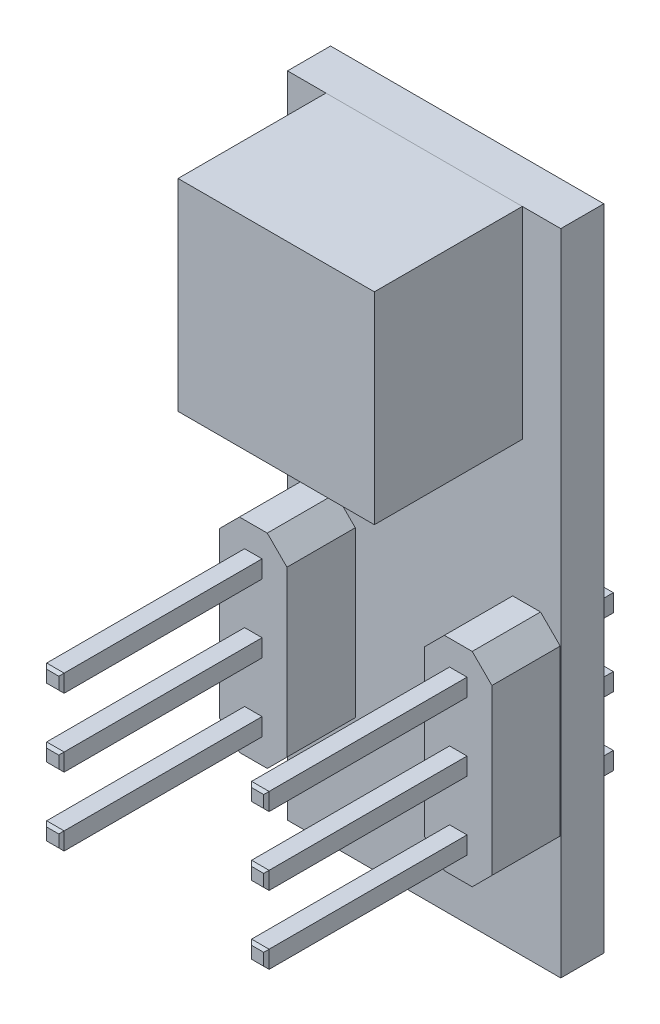
SolidWorks part; units mm, degrees
material "ABS"
ref_plane "Front Plane" through (0, 0, 0) normal (0, 0, 1) x (1, 0, 0)
ref_plane "Top Plane" through (0, 0, 0) normal (0, 1, 0) x (1, 0, 0)
ref_plane "Right Plane" through (0, 0, 0) normal (1, 0, 0) x (0, 0, -1)
sketch "Model" plane through (0, 0, 0) normal (0, 0, 1) x (1, 0, 0)
  line L0 (0, 24.13) -> (0, 0)
  line L1 (0, 0) -> (10.16, 0)
  line L2 (10.16, 0) -> (10.16, 24.13)
  line L3 (10.16, 24.13) -> (0, 24.13)
  line L4 (5.08, 11.43) -> (5.08, 3.81)
  line L5 (5.08, 11.43) -> (6.985, 11.43)
  line L6 (6.985, 11.43) -> (7.62, 10.795)
  line L7 (5.08, 11.43) -> (3.1496, 11.43)
  line L8 (3.1496, 11.43) -> (2.5146, 10.795)
  line L9 (5.08, 3.81) -> (7.0104, 3.81)
  line L10 (7.0104, 3.81) -> (7.62, 4.4196)
  line L11 (5.08, 3.81) -> (3.1242, 3.81)
  line L12 (3.1242, 3.81) -> (2.5146, 4.4196)
  line L13 (4.7371, 10.5035) -> (4.7371, 10.0459)
  line L14 (4.7371, 10.0459) -> (4.5083, 9.8171)
  line L15 (4.5083, 9.8171) -> (4.2795, 10.0459)
  line L16 (4.2795, 10.0459) -> (4.2795, 10.5035)
  line L17 (3.5311, 10.3891) -> (3.6455, 10.5035)
  line L18 (3.6455, 10.5035) -> (3.8743, 10.5035)
  line L19 (3.8743, 10.5035) -> (3.9887, 10.3891)
  line L20 (3.9887, 10.3891) -> (3.9887, 9.9315)
  line L21 (3.9887, 9.9315) -> (3.8743, 9.8171)
  line L22 (3.8743, 9.8171) -> (3.6455, 9.8171)
  line L23 (3.6455, 9.8171) -> (3.5311, 9.9315)
  line L24 (2.7827, 10.3891) -> (2.8971, 10.5035)
  line L25 (2.8971, 10.5035) -> (3.1259, 10.5035)
  line L26 (3.1259, 10.5035) -> (3.2403, 10.3891)
  line L27 (3.2403, 10.3891) -> (3.2403, 9.9315)
  line L28 (3.2403, 9.9315) -> (3.1259, 9.8171)
  line L29 (3.1259, 9.8171) -> (2.8971, 9.8171)
  line L30 (2.8971, 9.8171) -> (2.7827, 9.9315)
  line L31 (4.2795, 7.8491) -> (4.3939, 7.9635)
  line L32 (4.3939, 7.9635) -> (4.6227, 7.9635)
  line L33 (4.6227, 7.9635) -> (4.7371, 7.8491)
  line L34 (4.7371, 7.8491) -> (4.7371, 7.3915)
  line L35 (4.7371, 7.3915) -> (4.6227, 7.2771)
  line L36 (4.6227, 7.2771) -> (4.3939, 7.2771)
  line L37 (4.3939, 7.2771) -> (4.2795, 7.3915)
  line L38 (4.2795, 7.3915) -> (4.2795, 7.6203)
  line L39 (4.2795, 7.6203) -> (4.5083, 7.6203)
  line L40 (3.9887, 7.2771) -> (3.9887, 7.9635)
  line L41 (3.9887, 7.9635) -> (3.5311, 7.2771)
  line L42 (3.5311, 7.2771) -> (3.5311, 7.9635)
  line L43 (3.2403, 7.9635) -> (3.2403, 7.2771)
  line L44 (3.2403, 7.2771) -> (2.8971, 7.2771)
  line L45 (2.8971, 7.2771) -> (2.7827, 7.3915)
  line L46 (2.7827, 7.3915) -> (2.7827, 7.8491)
  line L47 (2.7827, 7.8491) -> (2.8971, 7.9635)
  line L48 (2.8971, 7.9635) -> (3.2403, 7.9635)
  line L49 (6.9211, 10.3891) -> (7.0355, 10.5035)
  line L50 (7.0355, 10.5035) -> (7.2643, 10.5035)
  line L51 (7.2643, 10.5035) -> (7.3787, 10.3891)
  line L52 (7.3787, 10.3891) -> (7.3787, 10.2747)
  line L53 (7.3787, 10.2747) -> (7.2643, 10.1603)
  line L54 (7.2643, 10.1603) -> (7.0355, 10.1603)
  line L55 (7.0355, 10.1603) -> (6.9211, 10.0459)
  line L56 (6.9211, 10.0459) -> (6.9211, 9.9315)
  line L57 (6.9211, 9.9315) -> (7.0355, 9.8171)
  line L58 (7.0355, 9.8171) -> (7.2643, 9.8171)
  line L59 (7.2643, 9.8171) -> (7.3787, 9.9315)
  line L60 (6.6303, 10.5035) -> (6.6303, 9.8171)
  line L61 (6.6303, 9.8171) -> (6.2871, 9.8171)
  line L62 (6.2871, 9.8171) -> (6.1727, 9.9315)
  line L63 (6.1727, 9.9315) -> (6.1727, 10.3891)
  line L64 (6.1727, 10.3891) -> (6.2871, 10.5035)
  line L65 (6.2871, 10.5035) -> (6.6303, 10.5035)
  line L66 (5.8819, 9.8171) -> (5.8819, 10.2747)
  line L67 (5.8819, 10.2747) -> (5.6531, 10.5035)
  line L68 (5.6531, 10.5035) -> (5.4243, 10.2747)
  line L69 (5.4243, 10.2747) -> (5.4243, 9.8171)
  line L70 (5.8819, 10.1603) -> (5.4243, 10.1603)
  line L71 (6.9211, 7.8491) -> (7.0355, 7.9635)
  line L72 (7.0355, 7.9635) -> (7.2643, 7.9635)
  line L73 (7.2643, 7.9635) -> (7.3787, 7.8491)
  line L74 (7.3787, 7.8491) -> (7.3787, 7.7347)
  line L75 (7.3787, 7.7347) -> (7.2643, 7.6203)
  line L76 (7.2643, 7.6203) -> (7.0355, 7.6203)
  line L77 (7.0355, 7.6203) -> (6.9211, 7.5059)
  line L78 (6.9211, 7.5059) -> (6.9211, 7.3915)
  line L79 (6.9211, 7.3915) -> (7.0355, 7.2771)
  line L80 (7.0355, 7.2771) -> (7.2643, 7.2771)
  line L81 (7.2643, 7.2771) -> (7.3787, 7.3915)
  line L82 (6.1727, 7.8491) -> (6.2871, 7.9635)
  line L83 (6.2871, 7.9635) -> (6.5159, 7.9635)
  line L84 (6.5159, 7.9635) -> (6.6303, 7.8491)
  line L85 (6.6303, 7.8491) -> (6.6303, 7.3915)
  line L86 (6.6303, 7.3915) -> (6.5159, 7.2771)
  line L87 (6.5159, 7.2771) -> (6.2871, 7.2771)
  line L88 (6.2871, 7.2771) -> (6.1727, 7.3915)
  line L89 (5.8819, 7.9635) -> (5.8819, 7.2771)
  line L90 (5.8819, 7.2771) -> (5.4243, 7.2771)
  line L91 (4.7371, 4.7371) -> (4.7371, 5.1947)
  line L92 (4.7371, 5.1947) -> (4.5083, 5.4235)
  line L93 (4.5083, 5.4235) -> (4.2795, 5.1947)
  line L94 (4.2795, 5.1947) -> (4.2795, 4.7371)
  line L95 (4.7371, 5.0803) -> (4.2795, 5.0803)
  line L96 (3.9887, 5.4235) -> (3.9887, 4.7371)
  line L97 (3.9887, 4.7371) -> (3.5311, 4.7371)
  line L98 (3.0115, 4.7371) -> (3.0115, 5.4235)
  line L99 (3.2403, 5.4235) -> (2.7827, 5.4235)
  line L100 (7.3787, 4.8515) -> (7.3787, 5.3091)
  line L101 (7.3787, 5.3091) -> (7.2643, 5.4235)
  line L102 (7.2643, 5.4235) -> (7.0355, 5.4235)
  line L103 (7.0355, 5.4235) -> (6.9211, 5.3091)
  line L104 (6.9211, 5.3091) -> (6.9211, 4.8515)
  line L105 (6.9211, 4.8515) -> (7.0355, 4.7371)
  line L106 (7.0355, 4.7371) -> (7.2643, 4.7371)
  line L107 (7.2643, 4.7371) -> (7.3787, 4.8515)
  line L108 (7.1499, 4.9659) -> (6.9211, 4.7371)
  line L109 (6.1727, 5.3091) -> (6.2871, 5.4235)
  line L110 (6.2871, 5.4235) -> (6.5159, 5.4235)
  line L111 (6.5159, 5.4235) -> (6.6303, 5.3091)
  line L112 (6.6303, 5.3091) -> (6.6303, 5.1947)
  line L113 (6.6303, 5.1947) -> (6.5159, 5.0803)
  line L114 (6.5159, 5.0803) -> (6.2871, 5.0803)
  line L115 (6.2871, 5.0803) -> (6.1727, 4.9659)
  line L116 (6.1727, 4.9659) -> (6.1727, 4.8515)
  line L117 (6.1727, 4.8515) -> (6.2871, 4.7371)
  line L118 (6.2871, 4.7371) -> (6.5159, 4.7371)
  line L119 (6.5159, 4.7371) -> (6.6303, 4.8515)
  line L120 (5.6531, 4.7371) -> (5.6531, 5.4235)
  line L121 (5.8819, 5.4235) -> (5.4243, 5.4235)
  line L122 (6.8961, 22.2123) -> (6.8961, 23.2546)
  line L123 (6.8961, 23.2546) -> (6.2012, 23.2546)
  line L124 (6.8961, 22.7334) -> (6.5487, 22.7334)
  line L125 (5.7267, 22.9072) -> (5.7267, 22.386)
  line L126 (5.7267, 22.386) -> (5.553, 22.2123)
  line L127 (5.553, 22.2123) -> (5.0318, 22.2123)
  line L128 (5.0318, 22.2123) -> (5.0318, 22.9072)
  line L129 (4.0362, 22.2123) -> (4.3836, 22.2123)
  line L130 (4.3836, 22.2123) -> (4.5573, 22.386)
  line L131 (4.5573, 22.386) -> (4.5573, 22.7334)
  line L132 (4.5573, 22.7334) -> (4.3836, 22.9072)
  line L133 (4.3836, 22.9072) -> (4.0362, 22.9072)
  line L134 (4.0362, 22.9072) -> (3.8624, 22.7334)
  line L135 (3.8624, 22.7334) -> (3.8624, 22.5597)
  line L136 (3.8624, 22.5597) -> (4.5573, 22.5597)
  line L137 (3.3879, 23.2546) -> (3.2142, 23.2546)
  line L138 (3.2142, 23.2546) -> (3.2142, 22.2123)
  line L139 (3.3879, 22.2123) -> (3.0405, 22.2123)
  line L140 (7.0902, 21.5315) -> (7.264, 21.7052)
  line L141 (7.264, 21.7052) -> (7.6114, 21.7052)
  line L142 (7.6114, 21.7052) -> (7.7851, 21.5315)
  line L143 (7.7851, 21.5315) -> (7.7851, 20.8366)
  line L144 (7.7851, 20.8366) -> (7.6114, 20.6629)
  line L145 (7.6114, 20.6629) -> (7.264, 20.6629)
  line L146 (7.264, 20.6629) -> (7.0902, 20.8366)
  line L147 (7.0902, 20.8366) -> (7.0902, 21.184)
  line L148 (7.0902, 21.184) -> (7.4377, 21.184)
  line L149 (6.442, 21.3578) -> (6.0946, 21.3578)
  line L150 (6.0946, 21.3578) -> (5.9208, 21.184)
  line L151 (5.9208, 21.184) -> (5.9208, 20.6629)
  line L152 (5.9208, 20.6629) -> (6.442, 20.6629)
  line L153 (6.442, 20.6629) -> (6.6157, 20.8366)
  line L154 (6.6157, 20.8366) -> (6.442, 21.0103)
  line L155 (6.442, 21.0103) -> (5.9208, 21.0103)
  line L156 (5.4463, 21.3578) -> (5.4463, 20.8366)
  line L157 (5.4463, 20.8366) -> (5.2726, 20.6629)
  line L158 (5.2726, 20.6629) -> (4.7514, 20.6629)
  line L159 (4.7514, 20.6629) -> (4.7514, 21.3578)
  line L160 (3.9295, 20.3155) -> (3.7558, 20.3155)
  line L161 (3.7558, 20.3155) -> (3.5821, 20.4892)
  line L162 (3.5821, 20.4892) -> (3.5821, 21.3578)
  line L163 (3.5821, 21.3578) -> (4.1032, 21.3578)
  line L164 (4.1032, 21.3578) -> (4.2769, 21.184)
  line L165 (4.2769, 21.184) -> (4.2769, 20.8366)
  line L166 (4.2769, 20.8366) -> (4.1032, 20.6629)
  line L167 (4.1032, 20.6629) -> (3.5821, 20.6629)
  line L168 (2.5864, 20.6629) -> (2.9338, 20.6629)
  line L169 (2.9338, 20.6629) -> (3.1075, 20.8366)
  line L170 (3.1075, 20.8366) -> (3.1075, 21.184)
  line L171 (3.1075, 21.184) -> (2.9338, 21.3578)
  line L172 (2.9338, 21.3578) -> (2.5864, 21.3578)
  line L173 (2.5864, 21.3578) -> (2.4127, 21.184)
  line L174 (2.4127, 21.184) -> (2.4127, 21.0103)
  line L175 (2.4127, 21.0103) -> (3.1075, 21.0103)
  line L176 (9.1313, 12.7006) -> (8.1314, 12.7006)
  line L177 (8.6313, 13.2006) -> (8.6313, 12.2007)
  line L178 (2.0193, 12.7006) -> (1.0194, 12.7006)
  line L179 (0.7611, 22.6901) -> (0.7611, 23.368)
  line L180 (0.7611, 23.368) -> (1.2696, 23.368)
  line L181 (1.2696, 23.368) -> (1.1001, 23.029)
  line L182 (1.1001, 23.029) -> (1.1001, 22.8596)
  line L183 (1.1001, 22.8596) -> (1.2696, 22.6901)
  line L184 (1.2696, 22.6901) -> (1.6085, 22.6901)
  line L185 (1.6085, 22.6901) -> (1.778, 22.8596)
  line L186 (1.778, 22.8596) -> (1.778, 23.1985)
  line L187 (1.778, 23.1985) -> (1.6085, 23.368)
  line L188 (1.2696, 22.1986) -> (1.2696, 21.5207)
  line L189 (0.9306, 21.0292) -> (0.7611, 20.8597)
  line L190 (0.7611, 20.8597) -> (0.7611, 20.5208)
  line L191 (0.7611, 20.5208) -> (0.9306, 20.3513)
  line L192 (0.9306, 20.3513) -> (1.1001, 20.3513)
  line L193 (1.1001, 20.3513) -> (1.2696, 20.5208)
  line L194 (1.2696, 20.5208) -> (1.2696, 20.6903)
  line L195 (1.2696, 20.5208) -> (1.439, 20.3513)
  line L196 (1.439, 20.3513) -> (1.6085, 20.3513)
  line L197 (1.6085, 20.3513) -> (1.778, 20.5208)
  line L198 (1.778, 20.5208) -> (1.778, 20.8597)
  line L199 (1.778, 20.8597) -> (1.6085, 21.0292)
  line L200 (1.2696, 19.8598) -> (1.2696, 19.1819)
  line L201 (1.1001, 18.6904) -> (0.7611, 18.3515)
  line L202 (0.7611, 18.3515) -> (1.778, 18.3515)
  line L203 (1.778, 18.6904) -> (1.778, 18.0125)
  line L204 (1.1001, 17.521) -> (0.7611, 17.1821)
  line L205 (0.7611, 17.1821) -> (1.778, 17.1821)
  line L206 (1.778, 17.521) -> (1.778, 16.8431)
  line L207 (8.666, 12.455) -> (8.666, 12.945)
  line L208 (9.114, 12.945) -> (9.114, 12.455)
  line L209 (8.407, 11.227) -> (8.407, 14.173)
  line L210 (8.407, 14.173) -> (9.373, 14.173)
  line L211 (9.373, 14.173) -> (9.373, 11.227)
  line L212 (9.373, 11.227) -> (8.407, 11.227)
  line L213 (8.8595, 12.7) -> (8.9205, 12.7)
  line L214 (7.861, 12.0779) -> (7.7975, 12.0144)
  line L215 (7.7975, 12.0144) -> (7.7975, 11.8873)
  line L216 (7.7975, 11.8873) -> (7.861, 11.8237)
  line L217 (7.861, 11.8237) -> (8.1152, 11.8237)
  line L218 (8.1152, 11.8237) -> (8.1788, 11.8873)
  line L219 (8.1788, 11.8873) -> (8.1788, 12.0144)
  line L220 (8.1788, 12.0144) -> (8.1152, 12.0779)
  line L221 (7.9246, 12.1979) -> (7.7975, 12.325)
  line L222 (7.7975, 12.325) -> (8.1788, 12.325)
  line L223 (8.1788, 12.1979) -> (8.1788, 12.4521)
  line L224 (9.7661, 11.6332) -> (9.639, 11.7603)
  line L225 (9.639, 11.7603) -> (10.0203, 11.7603)
  line L226 (10.0203, 11.6332) -> (10.0203, 11.8874)
  line L227 (9.7661, 12.0074) -> (9.9567, 12.0074)
  line L228 (9.9567, 12.0074) -> (10.0203, 12.071)
  line L229 (10.0203, 12.071) -> (10.0203, 12.2616)
  line L230 (10.0203, 12.2616) -> (9.7661, 12.2616)
  line L231 (10.0203, 12.3816) -> (9.639, 12.3816)
  line L232 (9.639, 12.3816) -> (9.639, 12.6358)
  line L233 (9.8296, 12.3816) -> (9.8296, 12.5087)
  line L234 (1.046, 12.455) -> (1.046, 12.945)
  line L235 (1.494, 12.945) -> (1.494, 12.455)
  line L236 (0.787, 11.227) -> (0.787, 14.173)
  line L237 (0.787, 14.173) -> (1.753, 14.173)
  line L238 (1.753, 14.173) -> (1.753, 11.227)
  line L239 (1.753, 11.227) -> (0.787, 11.227)
  line L240 (1.2395, 12.7) -> (1.3005, 12.7)
  line L241 (0.241, 12.0779) -> (0.1775, 12.0144)
  line L242 (0.1775, 12.0144) -> (0.1775, 11.8873)
  line L243 (0.1775, 11.8873) -> (0.241, 11.8237)
  line L244 (0.241, 11.8237) -> (0.4952, 11.8237)
  line L245 (0.4952, 11.8237) -> (0.5588, 11.8873)
  line L246 (0.5588, 11.8873) -> (0.5588, 12.0144)
  line L247 (0.5588, 12.0144) -> (0.4952, 12.0779)
  line L248 (0.5588, 12.4521) -> (0.5588, 12.1979)
  line L249 (0.5588, 12.1979) -> (0.3046, 12.4521)
  line L250 (0.3046, 12.4521) -> (0.241, 12.4521)
  line L251 (0.241, 12.4521) -> (0.1775, 12.3886)
  line L252 (0.1775, 12.3886) -> (0.1775, 12.2615)
  line L253 (0.1775, 12.2615) -> (0.241, 12.1979)
  line L254 (2.1461, 11.6332) -> (2.019, 11.7603)
  line L255 (2.019, 11.7603) -> (2.4003, 11.7603)
  line L256 (2.4003, 11.6332) -> (2.4003, 11.8874)
  line L257 (2.3367, 12.0074) -> (2.0825, 12.0074)
  line L258 (2.0825, 12.0074) -> (2.019, 12.071)
  line L259 (2.019, 12.071) -> (2.019, 12.1981)
  line L260 (2.019, 12.1981) -> (2.0825, 12.2616)
  line L261 (2.0825, 12.2616) -> (2.3367, 12.2616)
  line L262 (2.3367, 12.2616) -> (2.4003, 12.1981)
  line L263 (2.4003, 12.1981) -> (2.4003, 12.071)
  line L264 (2.4003, 12.071) -> (2.3367, 12.0074)
  line L265 (2.3367, 12.0074) -> (2.0825, 12.2616)
  line L266 (2.4003, 12.3816) -> (2.1461, 12.3816)
  line L267 (2.1461, 12.3816) -> (2.1461, 12.5723)
  line L268 (2.1461, 12.5723) -> (2.2096, 12.6358)
  line L269 (2.2096, 12.6358) -> (2.4003, 12.6358)
  line L270 (2.4003, 12.7558) -> (2.019, 12.7558)
  line L271 (2.019, 12.7558) -> (2.019, 13.01)
  line L272 (2.2096, 12.7558) -> (2.2096, 12.8829)
  line L273 (1.08, 19.32) -> (1.08, 15.82)
  line L274 (1.08, 15.82) -> (1.88, 15.82)
  line L275 (1.88, 15.82) -> (1.88, 18.32)
  line L276 (1.88, 18.32) -> (3.08, 18.32)
  line L277 (7.08, 18.32) -> (8.28, 18.32)
  line L278 (8.28, 18.32) -> (8.28, 15.82)
  line L279 (8.28, 15.82) -> (9.08, 15.82)
  line L280 (9.08, 15.82) -> (9.08, 19.32)
  line L281 (7.08, 23.32) -> (3.08, 23.32)
  line L282 (7.2898, 16.5105) -> (8.0694, 16.5105)
  line L283 (7.6796, 16.9003) -> (7.6796, 16.1207)
  line L284 (2.2098, 16.5105) -> (2.9894, 16.5105)
  line L285 (3.8227, 21.6663) -> (3.8863, 21.6027)
  line L286 (3.8863, 21.6027) -> (3.9498, 21.6027)
  line L287 (3.9498, 21.6027) -> (4.0134, 21.6663)
  line L288 (4.0134, 21.6663) -> (4.0134, 21.984)
  line L289 (3.9498, 21.984) -> (4.0769, 21.984)
  line L290 (4.1969, 21.6027) -> (4.1969, 21.984)
  line L291 (4.1969, 21.984) -> (4.3876, 21.984)
  line L292 (4.3876, 21.984) -> (4.4511, 21.9205)
  line L293 (4.4511, 21.9205) -> (4.4511, 21.7934)
  line L294 (4.4511, 21.7934) -> (4.3876, 21.7298)
  line L295 (4.3876, 21.7298) -> (4.1969, 21.7298)
  line L296 (4.5711, 21.8569) -> (4.6982, 21.984)
  line L297 (4.6982, 21.984) -> (4.6982, 21.6027)
  line L298 (4.5711, 21.6027) -> (4.8253, 21.6027)
  line L299 (3.8227, 20.5869) -> (3.8863, 20.5869)
  line L300 (3.8863, 20.5869) -> (3.8863, 20.3327)
  line L301 (3.8227, 20.3327) -> (3.9498, 20.3327)
  line L302 (3.8863, 20.7776) -> (3.8863, 20.714)
  line L303 (4.0722, 20.3327) -> (4.0722, 20.5869)
  line L304 (4.0722, 20.5869) -> (4.2628, 20.5869)
  line L305 (4.2628, 20.5869) -> (4.3264, 20.5234)
  line L306 (4.3264, 20.5234) -> (4.3264, 20.3327)
  line L307 (4.4464, 20.2056) -> (4.4464, 20.5869)
  line L308 (4.4464, 20.5869) -> (4.637, 20.5869)
  line L309 (4.637, 20.5869) -> (4.7006, 20.5234)
  line L310 (4.7006, 20.5234) -> (4.7006, 20.3963)
  line L311 (4.7006, 20.3963) -> (4.637, 20.3327)
  line L312 (4.637, 20.3327) -> (4.4464, 20.3327)
  line L313 (4.8206, 20.5869) -> (4.8206, 20.3963)
  line L314 (4.8206, 20.3963) -> (4.8841, 20.3327)
  line L315 (4.8841, 20.3327) -> (5.0748, 20.3327)
  line L316 (5.0748, 20.3327) -> (5.0748, 20.5869)
  line L317 (5.2583, 20.6505) -> (5.2583, 20.3963)
  line L318 (5.2583, 20.3963) -> (5.3219, 20.3327)
  line L319 (5.1948, 20.5869) -> (5.3219, 20.5869)
  line L320 (8.255, 6.35) -> (7.62, 5.715)
  line L321 (7.62, 5.715) -> (7.62, 4.445)
  line L322 (7.62, 4.445) -> (8.255, 3.81)
  line L323 (9.525, 3.81) -> (10.16, 4.445)
  line L324 (10.16, 4.445) -> (10.16, 5.715)
  line L325 (10.16, 5.715) -> (9.525, 6.35)
  line L326 (7.62, 10.795) -> (7.62, 9.525)
  line L327 (7.62, 9.525) -> (8.255, 8.89)
  line L328 (9.525, 8.89) -> (10.16, 9.525)
  line L329 (8.255, 8.89) -> (7.62, 8.255)
  line L330 (7.62, 8.255) -> (7.62, 6.985)
  line L331 (7.62, 6.985) -> (8.255, 6.35)
  line L332 (9.525, 6.35) -> (10.16, 6.985)
  line L333 (10.16, 6.985) -> (10.16, 8.255)
  line L334 (10.16, 8.255) -> (9.525, 8.89)
  line L335 (8.255, 11.43) -> (9.525, 11.43)
  line L336 (7.62, 10.795) -> (8.255, 11.43)
  line L337 (9.525, 11.43) -> (10.16, 10.795)
  line L338 (10.16, 9.525) -> (10.16, 10.795)
  line L339 (8.255, 3.81) -> (9.525, 3.81)
  line L340 (6.0454, 8.0615) -> (5.8547, 8.2522)
  line L341 (5.8547, 8.2522) -> (5.8547, 8.4428)
  line L342 (5.8547, 8.4428) -> (6.0454, 8.6335)
  line L343 (6.0454, 8.6335) -> (6.9987, 8.6335)
  line L344 (6.9987, 8.4428) -> (6.9987, 8.8242)
  line L345 (5.8547, 9.2309) -> (6.9987, 9.2309)
  line L346 (6.9987, 9.2309) -> (6.9987, 9.8029)
  line L347 (6.9987, 9.8029) -> (6.808, 9.9936)
  line L348 (6.808, 9.9936) -> (6.4267, 9.9936)
  line L349 (6.4267, 9.9936) -> (6.236, 9.8029)
  line L350 (6.236, 9.8029) -> (6.236, 9.2309)
  line L351 (5.8547, 11.1629) -> (5.8547, 10.4003)
  line L352 (5.8547, 10.4003) -> (6.6174, 11.1629)
  line L353 (6.6174, 11.1629) -> (6.808, 11.1629)
  line L354 (6.808, 11.1629) -> (6.9987, 10.9723)
  line L355 (6.9987, 10.9723) -> (6.9987, 10.591)
  line L356 (6.9987, 10.591) -> (6.808, 10.4003)
  line L357 (5.4228, 19.2456) -> (5.4711, 19.2532)
  line L358 (5.4711, 19.2532) -> (5.5651, 19.2606)
  line L359 (5.5651, 19.2606) -> (5.6591, 19.2532)
  line L360 (5.6591, 19.2532) -> (5.729, 19.2348)
  line L361 (5.729, 19.2348) -> (5.7938, 19.2027)
  line L362 (5.7938, 19.2027) -> (5.8508, 19.1583)
  line L363 (5.8508, 19.1583) -> (5.8978, 19.1033)
  line L364 (5.8978, 19.1033) -> (5.9379, 19.0301)
  line L365 (5.9379, 19.0301) -> (5.9619, 18.9502)
  line L366 (5.9619, 18.9502) -> (5.9689, 18.8671)
  line L367 (5.9689, 18.8671) -> (5.9689, 17.3507)
  line L368 (5.9689, 17.3507) -> (5.4813, 17.8994)
  line L369 (5.4813, 17.8994) -> (5.3945, 17.9789)
  line L370 (5.3945, 17.9789) -> (5.2933, 18.0391)
  line L371 (5.2933, 18.0391) -> (5.2561, 18.0526)
  line L372 (5.2561, 18.0526) -> (5.2171, 18.0594)
  line L373 (5.2171, 18.0594) -> (4.9885, 18.0594)
  line L374 (4.9885, 18.0594) -> (4.8522, 18.0718)
  line L375 (4.8522, 18.0718) -> (4.7203, 18.1086)
  line L376 (4.7203, 18.1086) -> (4.5973, 18.1686)
  line L377 (4.5973, 18.1686) -> (4.4816, 18.2503)
  line L378 (4.4816, 18.2503) -> (4.3784, 18.3475)
  line L379 (4.3784, 18.3475) -> (4.29, 18.4582)
  line L380 (4.29, 18.4582) -> (4.1953, 18.6263)
  line L381 (4.1953, 18.6263) -> (4.1325, 18.8087)
  line L382 (4.1325, 18.8087) -> (4.1037, 18.9994)
  line L383 (4.1037, 18.9994) -> (4.1097, 19.1922)
  line L384 (4.1097, 19.1922) -> (4.1304, 19.2962)
  line L385 (4.1304, 19.2962) -> (4.1662, 19.396)
  line L386 (4.1662, 19.396) -> (4.2163, 19.4894)
  line L387 (4.2163, 19.4894) -> (4.3069, 19.6031)
  line L388 (4.3069, 19.6031) -> (4.4195, 19.6952)
  line L389 (4.4195, 19.6952) -> (4.4195, 19.6063)
  line L390 (4.4195, 19.6063) -> (4.4215, 19.5918)
  line L391 (4.4215, 19.5918) -> (4.4272, 19.5783)
  line L392 (4.4272, 19.5783) -> (4.4568, 19.5416)
  line L393 (4.4568, 19.5416) -> (4.4957, 19.5148)
  line L394 (4.4957, 19.5148) -> (4.5161, 19.5072)
  line L395 (4.5161, 19.5072) -> (4.5733, 19.5011)
  line L396 (4.5733, 19.5011) -> (4.6299, 19.5115)
  line L397 (4.6299, 19.5115) -> (4.6812, 19.5377)
  line L398 (4.6812, 19.5377) -> (4.7726, 19.6037)
  line L399 (4.7726, 19.6037) -> (4.815, 19.6401)
  line L400 (4.815, 19.6401) -> (4.8513, 19.6825)
  line L401 (4.8513, 19.6825) -> (4.8806, 19.73)
  line L402 (4.8806, 19.73) -> (4.9021, 19.7815)
  line L403 (4.9021, 19.7815) -> (4.9086, 19.8142)
  line L404 (4.9086, 19.8142) -> (4.9072, 19.8476)
  line L405 (4.9072, 19.8476) -> (4.8906, 19.9026)
  line L406 (4.8906, 19.9026) -> (4.8603, 19.9515)
  line L407 (4.8603, 19.9515) -> (4.8183, 19.9907)
  line L408 (4.8183, 19.9907) -> (4.7675, 20.0177)
  line L409 (4.7675, 20.0177) -> (4.7163, 20.0322)
  line L410 (4.7163, 20.0322) -> (4.6634, 20.0381)
  line L411 (4.6634, 20.0381) -> (4.6025, 20.0381)
  line L412 (4.6025, 20.0381) -> (4.605, 20.0406)
  line L413 (4.605, 20.0406) -> (4.6485, 20.0744)
  line L414 (4.6485, 20.0744) -> (4.6989, 20.0965)
  line L415 (4.6989, 20.0965) -> (4.7345, 20.1117)
  line L416 (4.7345, 20.1117) -> (4.7574, 20.1219)
  line L417 (4.7574, 20.1219) -> (4.8452, 20.1439)
  line L418 (4.8452, 20.1439) -> (4.9352, 20.1524)
  line L419 (4.9352, 20.1524) -> (5.0221, 20.1458)
  line L420 (5.0221, 20.1458) -> (5.1061, 20.1226)
  line L421 (5.1061, 20.1226) -> (5.1841, 20.0838)
  line L422 (5.1841, 20.0838) -> (5.2618, 20.0278)
  line L423 (5.2618, 20.0278) -> (5.3314, 19.9619)
  line L424 (5.3314, 19.9619) -> (5.3745, 19.9015)
  line L425 (5.3745, 19.9015) -> (5.4013, 19.8323)
  line L426 (5.4013, 19.8323) -> (5.4099, 19.7586)
  line L427 (5.4099, 19.7586) -> (5.4, 19.6851)
  line L428 (5.4, 19.6851) -> (5.372, 19.6164)
  line L429 (5.372, 19.6164) -> (5.2534, 19.4406)
  line L430 (5.2534, 19.4406) -> (5.1079, 19.2862)
  line L431 (5.1079, 19.2862) -> (5.0696, 19.2413)
  line L432 (5.0696, 19.2413) -> (5.0441, 19.188)
  line L433 (5.0441, 19.188) -> (5.0334, 19.1299)
  line L434 (5.0334, 19.1299) -> (5.038, 19.071)
  line L435 (5.038, 19.071) -> (5.0576, 19.0153)
  line L436 (5.0576, 19.0153) -> (5.091, 18.9666)
  line L437 (5.091, 18.9666) -> (5.1358, 18.9281)
  line L438 (5.1358, 18.9281) -> (5.1922, 18.8977)
  line L439 (5.1922, 18.8977) -> (5.2529, 18.8772)
  line L440 (5.2529, 18.8772) -> (5.3162, 18.8671)
  line L441 (5.3162, 18.8671) -> (5.3902, 18.8708)
  line L442 (5.3902, 18.8708) -> (5.461, 18.8924)
  line L443 (5.461, 18.8924) -> (5.5244, 18.9306)
  line L444 (5.5244, 18.9306) -> (5.5581, 18.9659)
  line L445 (5.5581, 18.9659) -> (5.5803, 19.0094)
  line L446 (5.5803, 19.0094) -> (5.5902, 19.0539)
  line L447 (5.5902, 19.0539) -> (5.5902, 19.0995)
  line L448 (5.5902, 19.0995) -> (5.5803, 19.144)
  line L449 (5.5803, 19.144) -> (5.5713, 19.1611)
  line L450 (5.5713, 19.1611) -> (5.5575, 19.1745)
  line L451 (5.5575, 19.1745) -> (5.4736, 19.2354)
  line L452 (5.4736, 19.2354) -> (5.4579, 19.2438)
  line L453 (5.4579, 19.2438) -> (5.4405, 19.2473)
  line L454 (5.4405, 19.2473) -> (5.4228, 19.2456)
  line L455 (5.9689, 17.3736) -> (5.9486, 17.3736)
  line L456 (5.9689, 17.399) -> (5.926, 17.399)
  line L457 (5.9689, 17.4244) -> (5.9034, 17.4244)
  line L458 (5.9689, 17.4498) -> (5.8808, 17.4498)
  line L459 (5.9689, 17.4752) -> (5.8583, 17.4752)
  line L460 (5.9689, 17.5006) -> (5.8357, 17.5006)
  line L461 (5.9689, 17.526) -> (5.8131, 17.526)
  line L462 (5.9689, 17.5514) -> (5.7906, 17.5514)
  line L463 (5.9689, 17.5768) -> (5.768, 17.5768)
  line L464 (5.9689, 17.6022) -> (5.7454, 17.6022)
  line L465 (5.9689, 17.6276) -> (5.7228, 17.6276)
  line L466 (5.9689, 17.653) -> (5.7003, 17.653)
  line L467 (5.9689, 17.6784) -> (5.6777, 17.6784)
  line L468 (5.9689, 17.7038) -> (5.6551, 17.7038)
  line L469 (5.9689, 17.7292) -> (5.6326, 17.7292)
  line L470 (5.9689, 17.7546) -> (5.61, 17.7546)
  line L471 (5.9689, 17.78) -> (5.5874, 17.78)
  line L472 (5.9689, 17.8054) -> (5.5648, 17.8054)
  line L473 (5.9689, 17.8308) -> (5.5423, 17.8308)
  line L474 (5.9689, 17.8562) -> (5.5197, 17.8562)
  line L475 (5.9689, 17.8816) -> (5.4971, 17.8816)
  line L476 (5.9689, 17.907) -> (5.473, 17.907)
  line L477 (5.9689, 17.9324) -> (5.4453, 17.9324)
  line L478 (5.9689, 17.9578) -> (5.4176, 17.9578)
  line L479 (5.9689, 17.9832) -> (5.3873, 17.9832)
  line L480 (5.9689, 18.0086) -> (5.3446, 18.0086)
  line L481 (5.9689, 18.034) -> (5.3019, 18.034)
  line L482 (5.9689, 18.0594) -> (4.9885, 18.0594)
  line L483 (5.9689, 18.0848) -> (4.8056, 18.0848)
  line L484 (5.9689, 18.1102) -> (4.7171, 18.1102)
  line L485 (5.9689, 18.1356) -> (4.665, 18.1356)
  line L486 (5.9689, 18.161) -> (4.6129, 18.161)
  line L487 (5.9689, 18.1864) -> (4.5721, 18.1864)
  line L488 (5.9689, 18.2118) -> (4.5361, 18.2118)
  line L489 (5.9689, 18.2372) -> (4.5002, 18.2372)
  line L490 (5.9689, 18.2626) -> (4.4685, 18.2626)
  line L491 (5.9689, 18.288) -> (4.4416, 18.288)
  line L492 (5.9689, 18.3134) -> (4.4146, 18.3134)
  line L493 (5.9689, 18.3388) -> (4.3877, 18.3388)
  line L494 (5.9689, 18.3642) -> (4.3651, 18.3642)
  line L495 (5.9689, 18.3896) -> (4.3448, 18.3896)
  line L496 (5.9689, 18.415) -> (4.3245, 18.415)
  line L497 (5.9689, 18.4404) -> (4.3042, 18.4404)
  line L498 (5.9689, 18.4658) -> (4.2857, 18.4658)
  line L499 (5.9689, 18.4912) -> (4.2714, 18.4912)
  line L500 (5.9689, 18.5166) -> (4.2571, 18.5166)
  line L501 (5.9689, 18.542) -> (4.2428, 18.542)
  line L502 (5.9689, 18.5674) -> (4.2285, 18.5674)
  line L503 (5.9689, 18.5928) -> (4.2142, 18.5928)
  line L504 (5.9689, 18.6182) -> (4.1999, 18.6182)
  line L505 (5.9689, 18.6436) -> (4.1894, 18.6436)
  line L506 (5.9689, 18.669) -> (4.1806, 18.669)
  line L507 (5.9689, 18.6944) -> (4.1719, 18.6944)
  line L508 (5.9689, 18.7198) -> (4.1631, 18.7198)
  line L509 (5.9689, 18.7452) -> (4.1544, 18.7452)
  line L510 (5.9689, 18.7706) -> (4.1456, 18.7706)
  line L511 (5.9689, 18.796) -> (4.1369, 18.796)
  line L512 (5.9689, 18.8214) -> (4.1306, 18.8214)
  line L513 (5.9689, 18.8468) -> (4.1268, 18.8468)
  line L514 (5.9685, 18.8722) -> (5.3948, 18.8722)
  line L515 (5.2842, 18.8722) -> (4.1229, 18.8722)
  line L516 (5.9663, 18.8976) -> (5.4696, 18.8976)
  line L517 (5.1922, 18.8977) -> (4.1191, 18.8976)
  line L518 (5.9642, 18.923) -> (5.5118, 18.923)
  line L519 (5.1453, 18.923) -> (4.1152, 18.923)
  line L520 (5.9621, 18.9484) -> (5.5414, 18.9484)
  line L521 (5.1121, 18.9484) -> (4.1114, 18.9484)
  line L522 (5.9549, 18.9738) -> (5.5621, 18.9738)
  line L523 (5.086, 18.9738) -> (4.1075, 18.9738)
  line L524 (5.9472, 18.9992) -> (5.5751, 18.9992)
  line L525 (5.0686, 18.9992) -> (4.1037, 18.9994)
  line L526 (5.9396, 19.0246) -> (5.5837, 19.0246)
  line L527 (5.0543, 19.0246) -> (4.1045, 19.0246)
  line L528 (5.927, 19.05) -> (5.5894, 19.05)
  line L529 (5.0454, 19.05) -> (4.1052, 19.05)
  line L530 (5.9131, 19.0754) -> (5.5902, 19.0754)
  line L531 (5.0376, 19.0754) -> (4.106, 19.0754)
  line L532 (5.8992, 19.1008) -> (5.5899, 19.1008)
  line L533 (5.0356, 19.1008) -> (4.1068, 19.1008)
  line L534 (5.8782, 19.1262) -> (5.5843, 19.1262)
  line L535 (5.0337, 19.1262) -> (4.1076, 19.1262)
  line L536 (5.8566, 19.1516) -> (5.5763, 19.1516)
  line L537 (5.0374, 19.1516) -> (4.1084, 19.1516)
  line L538 (5.8268, 19.177) -> (5.5541, 19.177)
  line L539 (5.0421, 19.177) -> (4.1092, 19.177)
  line L540 (5.7938, 19.2027) -> (5.5191, 19.2024)
  line L541 (5.051, 19.2024) -> (4.1117, 19.2024)
  line L542 (5.7431, 19.2278) -> (5.4841, 19.2278)
  line L543 (5.0632, 19.2278) -> (4.1168, 19.2278)
  line L544 (5.6591, 19.2532) -> (5.4711, 19.2532)
  line L545 (5.0798, 19.2532) -> (4.1218, 19.2532)
  line L546 (5.1014, 19.2786) -> (4.1269, 19.2786)
  line L547 (5.1247, 19.304) -> (4.1332, 19.304)
  line L548 (5.1486, 19.3294) -> (4.1423, 19.3294)
  line L549 (5.1726, 19.3548) -> (4.1514, 19.3548)
  line L550 (5.1965, 19.3802) -> (4.1605, 19.3802)
  line L551 (5.2204, 19.4056) -> (4.1713, 19.4056)
  line L552 (5.2444, 19.431) -> (4.185, 19.431)
  line L553 (5.2641, 19.4564) -> (4.1986, 19.4564)
  line L554 (5.2812, 19.4818) -> (4.2122, 19.4818)
  line L555 (5.2983, 19.5072) -> (4.6066, 19.5072)
  line L556 (4.5161, 19.5072) -> (4.2305, 19.5072)
  line L557 (5.3155, 19.5326) -> (4.6712, 19.5326)
  line L558 (4.4699, 19.5326) -> (4.2507, 19.5326)
  line L559 (5.3326, 19.558) -> (4.7093, 19.558)
  line L560 (4.4436, 19.558) -> (4.271, 19.558)
  line L561 (5.3497, 19.5834) -> (4.7445, 19.5834)
  line L562 (4.425, 19.5834) -> (4.2912, 19.5834)
  line L563 (5.3669, 19.6088) -> (4.7785, 19.6088)
  line L564 (4.4195, 19.6088) -> (4.3139, 19.6088)
  line L565 (5.3792, 19.6342) -> (4.8081, 19.6342)
  line L566 (4.4195, 19.6342) -> (4.3449, 19.6342)
  line L567 (5.3896, 19.6596) -> (4.8317, 19.6596)
  line L568 (4.4195, 19.6596) -> (4.376, 19.6596)
  line L569 (5.4, 19.6851) -> (4.8528, 19.685)
  line L570 (4.4195, 19.685) -> (4.407, 19.685)
  line L571 (5.4034, 19.7104) -> (4.8685, 19.7104)
  line L572 (5.4068, 19.7358) -> (4.883, 19.7358)
  line L573 (5.4096, 19.7612) -> (4.8936, 19.7612)
  line L574 (5.4066, 19.7866) -> (4.9031, 19.7866)
  line L575 (5.4037, 19.812) -> (4.9082, 19.812)
  line L576 (5.3993, 19.8374) -> (4.9076, 19.8374)
  line L577 (5.3895, 19.8628) -> (4.9026, 19.8628)
  line L578 (5.3797, 19.8882) -> (4.895, 19.8882)
  line L579 (5.3659, 19.9136) -> (4.8838, 19.9136)
  line L580 (5.3478, 19.939) -> (4.868, 19.939)
  line L581 (5.3288, 19.9644) -> (4.8464, 19.9644)
  line L582 (5.3019, 19.9898) -> (4.8193, 19.9898)
  line L583 (5.2751, 20.0152) -> (4.7722, 20.0152)
  line L584 (5.244, 20.0406) -> (4.605, 20.0406)
  line L585 (5.2088, 20.066) -> (4.6376, 20.066)
  line L586 (5.1688, 20.0914) -> (4.6873, 20.0914)
  line L587 (5.1178, 20.1168) -> (4.746, 20.1168)
  line L588 (5.035, 20.1422) -> (4.8386, 20.1422)
  line L589 (0.635, 6.35) -> (0, 5.715)
  line L590 (0, 5.715) -> (0, 4.445)
  line L591 (0, 4.445) -> (0.635, 3.81)
  line L592 (1.905, 3.81) -> (2.54, 4.445)
  line L593 (2.54, 4.445) -> (2.54, 5.715)
  line L594 (2.54, 5.715) -> (1.905, 6.35)
  line L595 (0, 10.795) -> (0, 9.525)
  line L596 (0, 9.525) -> (0.635, 8.89)
  line L597 (1.905, 8.89) -> (2.54, 9.525)
  line L598 (0.635, 8.89) -> (0, 8.255)
  line L599 (0, 8.255) -> (0, 6.985)
  line L600 (0, 6.985) -> (0.635, 6.35)
  line L601 (1.905, 6.35) -> (2.54, 6.985)
  line L602 (2.54, 6.985) -> (2.54, 8.255)
  line L603 (2.54, 8.255) -> (1.905, 8.89)
  line L604 (0.635, 11.43) -> (1.905, 11.43)
  line L605 (0, 10.795) -> (0.635, 11.43)
  line L606 (1.905, 11.43) -> (2.54, 10.795)
  line L607 (2.54, 9.525) -> (2.54, 10.795)
  line L608 (0.635, 3.81) -> (1.905, 3.81)
  line L609 (6.985, 13.97) -> (5.715, 13.97)
  line L610 (5.715, 13.97) -> (5.08, 13.335)
  line L611 (5.08, 12.065) -> (5.715, 11.43)
  line L612 (5.08, 13.335) -> (4.445, 13.97)
  line L613 (4.445, 13.97) -> (3.175, 13.97)
  line L614 (3.175, 13.97) -> (2.54, 13.335)
  line L615 (2.54, 12.065) -> (3.175, 11.43)
  line L616 (3.175, 11.43) -> (4.445, 11.43)
  line L617 (4.445, 11.43) -> (5.08, 12.065)
  line L618 (7.62, 13.335) -> (7.62, 12.065)
  line L619 (6.985, 13.97) -> (7.62, 13.335)
  line L620 (7.62, 12.065) -> (6.985, 11.43)
  line L621 (5.715, 11.43) -> (6.985, 11.43)
  line L622 (2.54, 13.335) -> (2.54, 12.065)
  line L623 (7.6327, 14.783) -> (7.442, 14.5923)
  line L624 (7.442, 14.5923) -> (7.2514, 14.5923)
  line L625 (7.2514, 14.5923) -> (7.0607, 14.783)
  line L626 (7.0607, 14.783) -> (7.0607, 15.7363)
  line L627 (7.2514, 15.7363) -> (6.87, 15.7363)
  line L628 (6.4633, 14.5923) -> (6.4633, 15.7363)
  line L629 (6.4633, 15.7363) -> (5.8913, 15.7363)
  line L630 (5.8913, 15.7363) -> (5.7007, 15.5456)
  line L631 (5.7007, 15.5456) -> (5.7007, 15.1643)
  line L632 (5.7007, 15.1643) -> (5.8913, 14.9736)
  line L633 (5.8913, 14.9736) -> (6.4633, 14.9736)
  line L634 (4.5313, 15.7363) -> (5.2939, 15.7363)
  line L635 (5.2939, 15.7363) -> (5.2939, 15.1643)
  line L636 (5.2939, 15.1643) -> (4.9126, 15.355)
  line L637 (4.9126, 15.355) -> (4.7219, 15.355)
  line L638 (4.7219, 15.355) -> (4.5313, 15.1643)
  line L639 (4.5313, 15.1643) -> (4.5313, 14.783)
  line L640 (4.5313, 14.783) -> (4.7219, 14.5923)
  line L641 (4.7219, 14.5923) -> (5.1032, 14.5923)
  line L642 (5.1032, 14.5923) -> (5.2939, 14.783)
  line L643 (6.595, 9.936) -> (6.105, 9.936)
  line L644 (6.105, 10.384) -> (6.595, 10.384)
  line L645 (7.823, 9.677) -> (4.877, 9.677)
  line L646 (4.877, 9.677) -> (4.877, 10.643)
  line L647 (4.877, 10.643) -> (7.823, 10.643)
  line L648 (7.823, 10.643) -> (7.823, 9.677)
  line L649 (6.5033, 9.0678) -> (6.5033, 9.4491)
  line L650 (6.5033, 9.4491) -> (6.6939, 9.4491)
  line L651 (6.6939, 9.4491) -> (6.7575, 9.3856)
  line L652 (6.7575, 9.3856) -> (6.7575, 9.2585)
  line L653 (6.7575, 9.2585) -> (6.6939, 9.1949)
  line L654 (6.6939, 9.1949) -> (6.5033, 9.1949)
  line L655 (6.6304, 9.1949) -> (6.7575, 9.0678)
  line L656 (6.8775, 9.322) -> (7.0046, 9.4491)
  line L657 (7.0046, 9.4491) -> (7.0046, 9.0678)
  line L658 (6.8775, 9.0678) -> (7.1317, 9.0678)
  line L659 (6.7562, 11.1635) -> (6.8833, 11.2906)
  line L660 (6.8833, 11.2906) -> (6.8833, 10.9093)
  line L661 (6.7562, 10.9093) -> (7.0104, 10.9093)
  line L662 (7.1304, 10.9093) -> (7.1304, 11.2906)
  line L663 (7.321, 10.9093) -> (7.1304, 11.0364)
  line L664 (7.1304, 11.0364) -> (7.321, 11.1635)
  line L665 (4.055, 9.936) -> (3.565, 9.936)
  line L666 (3.565, 10.384) -> (4.055, 10.384)
  line L667 (5.283, 9.677) -> (2.337, 9.677)
  line L668 (2.337, 9.677) -> (2.337, 10.643)
  line L669 (2.337, 10.643) -> (5.283, 10.643)
  line L670 (5.283, 10.643) -> (5.283, 9.677)
  line L671 (3.9633, 9.0678) -> (3.9633, 9.4491)
  line L672 (3.9633, 9.4491) -> (4.1539, 9.4491)
  line L673 (4.1539, 9.4491) -> (4.2175, 9.3856)
  line L674 (4.2175, 9.3856) -> (4.2175, 9.2585)
  line L675 (4.2175, 9.2585) -> (4.1539, 9.1949)
  line L676 (4.1539, 9.1949) -> (3.9633, 9.1949)
  line L677 (4.0904, 9.1949) -> (4.2175, 9.0678)
  line L678 (4.5917, 9.0678) -> (4.3375, 9.0678)
  line L679 (4.3375, 9.0678) -> (4.5917, 9.322)
  line L680 (4.5917, 9.322) -> (4.5917, 9.3856)
  line L681 (4.5917, 9.3856) -> (4.5282, 9.4491)
  line L682 (4.5282, 9.4491) -> (4.401, 9.4491)
  line L683 (4.401, 9.4491) -> (4.3375, 9.3856)
  line L684 (3.7796, 11.1635) -> (3.9067, 11.2906)
  line L685 (3.9067, 11.2906) -> (3.9067, 10.9093)
  line L686 (3.7796, 10.9093) -> (4.0338, 10.9093)
  line L687 (4.1538, 11.2271) -> (4.2173, 11.2906)
  line L688 (4.2173, 11.2906) -> (4.3444, 11.2906)
  line L689 (4.3444, 11.2906) -> (4.408, 11.2271)
  line L690 (4.408, 11.2271) -> (4.408, 11.1635)
  line L691 (4.408, 11.1635) -> (4.3444, 11.1)
  line L692 (4.3444, 11.1) -> (4.408, 11.0364)
  line L693 (4.408, 11.0364) -> (4.408, 10.9729)
  line L694 (4.408, 10.9729) -> (4.3444, 10.9093)
  line L695 (4.3444, 10.9093) -> (4.2173, 10.9093)
  line L696 (4.2173, 10.9093) -> (4.1538, 10.9729)
  line L697 (4.1538, 10.9729) -> (4.1538, 11.0364)
  line L698 (4.1538, 11.0364) -> (4.2173, 11.1)
  line L699 (4.2173, 11.1) -> (4.1538, 11.1635)
  line L700 (4.1538, 11.1635) -> (4.1538, 11.2271)
  line L701 (4.2173, 11.1) -> (4.3444, 11.1)
  line L702 (4.528, 10.9729) -> (4.528, 11.2271)
  line L703 (4.528, 11.2271) -> (4.5915, 11.2906)
  line L704 (4.5915, 11.2906) -> (4.7187, 11.2906)
  line L705 (4.7187, 11.2906) -> (4.7822, 11.2271)
  line L706 (4.7822, 11.2271) -> (4.7822, 10.9729)
  line L707 (4.7822, 10.9729) -> (4.7187, 10.9093)
  line L708 (4.7187, 10.9093) -> (4.5915, 10.9093)
  line L709 (4.5915, 10.9093) -> (4.528, 10.9729)
  line L710 (4.528, 10.9729) -> (4.7822, 11.2271)
  line L711 (2.295, 1.494) -> (2.785, 1.494)
  line L712 (2.785, 1.046) -> (2.295, 1.046)
  line L713 (1.067, 1.753) -> (4.013, 1.753)
  line L714 (4.013, 1.753) -> (4.013, 0.787)
  line L715 (4.013, 0.787) -> (1.067, 0.787)
  line L716 (1.067, 0.787) -> (1.067, 1.753)
  line L717 (1.6637, 1.9812) -> (1.6637, 2.3625)
  line L718 (1.6637, 2.3625) -> (1.8544, 2.3625)
  line L719 (1.8544, 2.3625) -> (1.9179, 2.299)
  line L720 (1.9179, 2.299) -> (1.9179, 2.1719)
  line L721 (1.9179, 2.1719) -> (1.8544, 2.1083)
  line L722 (1.8544, 2.1083) -> (1.6637, 2.1083)
  line L723 (1.7908, 2.1083) -> (1.9179, 1.9812)
  line L724 (2.0379, 2.299) -> (2.1015, 2.3625)
  line L725 (2.1015, 2.3625) -> (2.2286, 2.3625)
  line L726 (2.2286, 2.3625) -> (2.2921, 2.299)
  line L727 (2.2921, 2.299) -> (2.2921, 2.2354)
  line L728 (2.2921, 2.2354) -> (2.2286, 2.1719)
  line L729 (2.2286, 2.1719) -> (2.165, 2.1719)
  line L730 (2.2286, 2.1719) -> (2.2921, 2.1083)
  line L731 (2.2921, 2.1083) -> (2.2921, 2.0448)
  line L732 (2.2921, 2.0448) -> (2.2286, 1.9812)
  line L733 (2.2286, 1.9812) -> (2.1015, 1.9812)
  line L734 (2.1015, 1.9812) -> (2.0379, 2.0448)
  line L735 (1.6639, 0.1397) -> (1.6639, 0.521)
  line L736 (1.6639, 0.521) -> (1.4732, 0.3304)
  line L737 (1.4732, 0.3304) -> (1.7274, 0.3304)
  line L738 (1.8474, 0.1397) -> (1.8474, 0.2033)
  line L739 (1.8474, 0.2033) -> (1.911, 0.2033)
  line L740 (1.911, 0.2033) -> (1.911, 0.1397)
  line L741 (1.911, 0.1397) -> (1.8474, 0.1397)
  line L742 (2.0345, 0.521) -> (2.2887, 0.521)
  line L743 (2.2887, 0.521) -> (2.2887, 0.4575)
  line L744 (2.2887, 0.4575) -> (2.0345, 0.2033)
  line L745 (2.0345, 0.2033) -> (2.0345, 0.1397)
  line L746 (2.4087, 0.1397) -> (2.4087, 0.521)
  line L747 (2.5994, 0.1397) -> (2.4087, 0.2668)
  line L748 (2.4087, 0.2668) -> (2.5994, 0.3939)
  line L749 (2.295, 2.764) -> (2.785, 2.764)
  line L750 (2.785, 2.316) -> (2.295, 2.316)
  line L751 (1.067, 3.023) -> (4.013, 3.023)
  line L752 (4.013, 3.023) -> (4.013, 2.057)
  line L753 (4.013, 2.057) -> (1.067, 2.057)
  line L754 (1.067, 2.057) -> (1.067, 3.023)
  line L755 (1.6637, 3.2512) -> (1.6637, 3.6325)
  line L756 (1.6637, 3.6325) -> (1.8544, 3.6325)
  line L757 (1.8544, 3.6325) -> (1.9179, 3.569)
  line L758 (1.9179, 3.569) -> (1.9179, 3.4419)
  line L759 (1.9179, 3.4419) -> (1.8544, 3.3783)
  line L760 (1.8544, 3.3783) -> (1.6637, 3.3783)
  line L761 (1.7908, 3.3783) -> (1.9179, 3.2512)
  line L762 (2.2286, 3.2512) -> (2.2286, 3.6325)
  line L763 (2.2286, 3.6325) -> (2.0379, 3.4419)
  line L764 (2.0379, 3.4419) -> (2.2921, 3.4419)
  line L765 (1.6639, 1.4097) -> (1.6639, 1.791)
  line L766 (1.6639, 1.791) -> (1.4732, 1.6004)
  line L767 (1.4732, 1.6004) -> (1.7274, 1.6004)
  line L768 (1.8474, 1.4097) -> (1.8474, 1.4733)
  line L769 (1.8474, 1.4733) -> (1.911, 1.4733)
  line L770 (1.911, 1.4733) -> (1.911, 1.4097)
  line L771 (1.911, 1.4097) -> (1.8474, 1.4097)
  line L772 (2.0345, 1.791) -> (2.2887, 1.791)
  line L773 (2.2887, 1.791) -> (2.2887, 1.7275)
  line L774 (2.2887, 1.7275) -> (2.0345, 1.4733)
  line L775 (2.0345, 1.4733) -> (2.0345, 1.4097)
  line L776 (2.4087, 1.4097) -> (2.4087, 1.791)
  line L777 (2.5994, 1.4097) -> (2.4087, 1.5368)
  line L778 (2.4087, 1.5368) -> (2.5994, 1.6639)
  line L779 (7.865, 1.046) -> (7.375, 1.046)
  line L780 (7.375, 1.494) -> (7.865, 1.494)
  line L781 (9.093, 0.787) -> (6.147, 0.787)
  line L782 (6.147, 0.787) -> (6.147, 1.753)
  line L783 (6.147, 1.753) -> (9.093, 1.753)
  line L784 (9.093, 1.753) -> (9.093, 0.787)
  line L785 (7.7733, 0.1778) -> (7.7733, 0.5591)
  line L786 (7.7733, 0.5591) -> (7.9639, 0.5591)
  line L787 (7.9639, 0.5591) -> (8.0275, 0.4956)
  line L788 (8.0275, 0.4956) -> (8.0275, 0.3685)
  line L789 (8.0275, 0.3685) -> (7.9639, 0.3049)
  line L790 (7.9639, 0.3049) -> (7.7733, 0.3049)
  line L791 (7.9004, 0.3049) -> (8.0275, 0.1778)
  line L792 (8.4017, 0.5591) -> (8.1475, 0.5591)
  line L793 (8.1475, 0.5591) -> (8.1475, 0.3685)
  line L794 (8.1475, 0.3685) -> (8.2746, 0.432)
  line L795 (8.2746, 0.432) -> (8.3382, 0.432)
  line L796 (8.3382, 0.432) -> (8.4017, 0.3685)
  line L797 (8.4017, 0.3685) -> (8.4017, 0.2414)
  line L798 (8.4017, 0.2414) -> (8.3382, 0.1778)
  line L799 (8.3382, 0.1778) -> (8.211, 0.1778)
  line L800 (8.211, 0.1778) -> (8.1475, 0.2414)
  line L801 (7.6555, 2.0193) -> (7.6555, 2.4006)
  line L802 (7.6555, 2.4006) -> (7.4648, 2.21)
  line L803 (7.4648, 2.21) -> (7.7191, 2.21)
  line L804 (7.839, 2.0193) -> (7.839, 2.0829)
  line L805 (7.839, 2.0829) -> (7.9026, 2.0829)
  line L806 (7.9026, 2.0829) -> (7.9026, 2.0193)
  line L807 (7.9026, 2.0193) -> (7.839, 2.0193)
  line L808 (8.0262, 2.4006) -> (8.2804, 2.4006)
  line L809 (8.2804, 2.4006) -> (8.2804, 2.3371)
  line L810 (8.2804, 2.3371) -> (8.0262, 2.0829)
  line L811 (8.0262, 2.0829) -> (8.0262, 2.0193)
  line L812 (8.4004, 2.0193) -> (8.4004, 2.4006)
  line L813 (8.591, 2.0193) -> (8.4004, 2.1464)
  line L814 (8.4004, 2.1464) -> (8.591, 2.2735)
  line L815 (7.865, 2.316) -> (7.375, 2.316)
  line L816 (7.375, 2.764) -> (7.865, 2.764)
  line L817 (9.093, 2.057) -> (6.147, 2.057)
  line L818 (6.147, 2.057) -> (6.147, 3.023)
  line L819 (6.147, 3.023) -> (9.093, 3.023)
  line L820 (9.093, 3.023) -> (9.093, 2.057)
  line L821 (7.7733, 1.4478) -> (7.7733, 1.8291)
  line L822 (7.7733, 1.8291) -> (7.9639, 1.8291)
  line L823 (7.9639, 1.8291) -> (8.0275, 1.7656)
  line L824 (8.0275, 1.7656) -> (8.0275, 1.6385)
  line L825 (8.0275, 1.6385) -> (7.9639, 1.5749)
  line L826 (7.9639, 1.5749) -> (7.7733, 1.5749)
  line L827 (7.9004, 1.5749) -> (8.0275, 1.4478)
  line L828 (8.4017, 1.8291) -> (8.2746, 1.7656)
  line L829 (8.2746, 1.7656) -> (8.1475, 1.6385)
  line L830 (8.1475, 1.6385) -> (8.1475, 1.5114)
  line L831 (8.1475, 1.5114) -> (8.211, 1.4478)
  line L832 (8.211, 1.4478) -> (8.3382, 1.4478)
  line L833 (8.3382, 1.4478) -> (8.4017, 1.5114)
  line L834 (8.4017, 1.5114) -> (8.4017, 1.5749)
  line L835 (8.4017, 1.5749) -> (8.3382, 1.6385)
  line L836 (8.3382, 1.6385) -> (8.1475, 1.6385)
  line L837 (7.6555, 3.2893) -> (7.6555, 3.6706)
  line L838 (7.6555, 3.6706) -> (7.4648, 3.48)
  line L839 (7.4648, 3.48) -> (7.7191, 3.48)
  line L840 (7.839, 3.2893) -> (7.839, 3.3529)
  line L841 (7.839, 3.3529) -> (7.9026, 3.3529)
  line L842 (7.9026, 3.3529) -> (7.9026, 3.2893)
  line L843 (7.9026, 3.2893) -> (7.839, 3.2893)
  line L844 (8.0262, 3.6706) -> (8.2804, 3.6706)
  line L845 (8.2804, 3.6706) -> (8.2804, 3.6071)
  line L846 (8.2804, 3.6071) -> (8.0262, 3.3529)
  line L847 (8.0262, 3.3529) -> (8.0262, 3.2893)
  line L848 (8.4004, 3.2893) -> (8.4004, 3.6706)
  line L849 (8.591, 3.2893) -> (8.4004, 3.4164)
  line L850 (8.4004, 3.4164) -> (8.591, 3.5435)
  line L851 (4.6853, 14.6682) -> (4.5335, 14.7464)
  line L852 (4.5335, 14.7464) -> (4.1565, 14.439)
  line L853 (4.1565, 14.439) -> (3.898, 14.6975)
  line L854 (3.898, 14.6975) -> (4.2054, 15.0745)
  line L855 (4.2054, 15.0745) -> (4.1272, 15.2263)
  line L856 (4.1272, 15.2263) -> (4.0751, 15.389)
  line L857 (4.0751, 15.389) -> (3.5912, 15.4382)
  line L858 (3.5912, 15.4382) -> (3.5912, 15.8038)
  line L859 (3.5912, 15.8038) -> (4.0751, 15.853)
  line L860 (4.0751, 15.853) -> (4.1272, 16.0157)
  line L861 (4.1272, 16.0157) -> (4.2054, 16.1675)
  line L862 (4.2054, 16.1675) -> (3.898, 16.5445)
  line L863 (3.898, 16.5445) -> (4.1565, 16.803)
  line L864 (4.1565, 16.803) -> (4.5335, 16.4956)
  line L865 (4.5335, 16.4956) -> (4.6853, 16.5738)
  line L866 (4.6853, 16.5738) -> (4.848, 16.6259)
  line L867 (4.848, 16.6259) -> (4.8972, 17.1098)
  line L868 (4.8972, 17.1098) -> (5.2628, 17.1098)
  line L869 (5.2628, 17.1098) -> (5.312, 16.6259)
  line L870 (5.312, 16.6259) -> (5.4747, 16.5738)
  line L871 (5.4747, 16.5738) -> (5.6265, 16.4956)
  line L872 (5.6265, 16.4956) -> (6.0035, 16.803)
  line L873 (6.0035, 16.803) -> (6.262, 16.5445)
  line L874 (6.262, 16.5445) -> (5.9546, 16.1675)
  line L875 (5.9546, 16.1675) -> (6.0328, 16.0157)
  line L876 (6.0328, 16.0157) -> (6.0849, 15.853)
  line L877 (6.0849, 15.853) -> (6.5688, 15.8038)
  line L878 (6.5688, 15.8038) -> (6.5688, 15.4382)
  line L879 (6.5688, 15.4382) -> (6.0849, 15.389)
  line L880 (6.0849, 15.389) -> (6.0328, 15.2263)
  line L881 (6.0328, 15.2263) -> (5.9546, 15.0745)
  line L882 (5.9546, 15.0745) -> (6.262, 14.6975)
  line L883 (6.262, 14.6975) -> (6.0035, 14.439)
  line L884 (6.0035, 14.439) -> (5.6265, 14.7464)
  line L885 (5.6265, 14.7464) -> (5.4747, 14.6682)
  line L886 (5.4747, 14.6682) -> (5.2594, 15.1879)
  line L887 (5.2594, 15.1879) -> (5.3556, 15.2417)
  line L888 (5.3556, 15.2417) -> (5.4365, 15.3165)
  line L889 (5.4365, 15.3165) -> (5.4977, 15.4082)
  line L890 (5.4977, 15.4082) -> (5.5359, 15.5116)
  line L891 (5.5359, 15.5116) -> (5.5488, 15.621)
  line L892 (5.5488, 15.621) -> (5.5353, 15.7324)
  line L893 (5.5353, 15.7324) -> (5.4958, 15.8374)
  line L894 (5.4958, 15.8374) -> (5.4324, 15.93)
  line L895 (5.4324, 15.93) -> (5.3489, 16.0049)
  line L896 (5.3489, 16.0049) -> (5.2499, 16.0578)
  line L897 (5.2499, 16.0578) -> (5.1412, 16.0856)
  line L898 (5.1412, 16.0856) -> (5.029, 16.0868)
  line L899 (5.029, 16.0868) -> (4.9198, 16.0614)
  line L900 (4.9198, 16.0614) -> (4.8197, 16.0106)
  line L901 (4.8197, 16.0106) -> (4.7345, 15.9376)
  line L902 (4.7345, 15.9376) -> (4.6692, 15.8464)
  line L903 (4.6692, 15.8464) -> (4.6273, 15.7423)
  line L904 (4.6273, 15.7423) -> (4.6115, 15.6312)
  line L905 (4.6115, 15.6312) -> (4.6225, 15.5195)
  line L906 (4.6225, 15.5195) -> (4.6597, 15.4137)
  line L907 (4.6597, 15.4137) -> (4.721, 15.3197)
  line L908 (4.721, 15.3197) -> (4.8028, 15.243)
  line L909 (4.8028, 15.243) -> (4.9006, 15.1879)
  line L910 (4.9006, 15.1879) -> (4.6853, 14.6682)
  line L911 (6.1355, 14.571) -> (5.8416, 14.571)
  line L912 (4.3184, 14.571) -> (4.0245, 14.571)
  line L913 (6.2428, 14.721) -> (5.6577, 14.721)
  line L914 (5.5772, 14.721) -> (5.4528, 14.721)
  line L915 (4.7072, 14.721) -> (4.5828, 14.721)
  line L916 (4.5023, 14.721) -> (3.9172, 14.721)
  line L917 (6.1205, 14.871) -> (5.3907, 14.871)
  line L918 (4.7693, 14.871) -> (4.0395, 14.871)
  line L919 (5.9982, 15.021) -> (5.3285, 15.021)
  line L920 (4.8315, 15.021) -> (4.1618, 15.021)
  line L921 (6.0043, 15.171) -> (5.2664, 15.171)
  line L922 (4.8936, 15.171) -> (4.1557, 15.171)
  line L923 (6.0631, 15.321) -> (5.4395, 15.321)
  line L924 (4.7201, 15.321) -> (4.0969, 15.321)
  line L925 (6.5688, 15.471) -> (5.5209, 15.471)
  line L926 (4.6395, 15.471) -> (3.5912, 15.471)
  line L927 (6.5688, 15.621) -> (5.5488, 15.621)
  line L928 (4.6125, 15.621) -> (3.5912, 15.621)
  line L929 (6.5688, 15.771) -> (5.5208, 15.771)
  line L930 (4.6389, 15.771) -> (3.5912, 15.771)
  line L931 (6.0631, 15.921) -> (5.4386, 15.921)
  line L932 (4.7226, 15.921) -> (4.0969, 15.921)
  line L933 (6.0043, 16.071) -> (5.1983, 16.071)
  line L934 (4.9611, 16.071) -> (4.1557, 16.071)
  line L935 (5.9982, 16.221) -> (4.1618, 16.221)
  line L936 (6.1205, 16.371) -> (4.0395, 16.371)
  line L937 (6.2428, 16.521) -> (5.6577, 16.521)
  line L938 (5.5772, 16.521) -> (4.5828, 16.521)
  line L939 (4.5023, 16.521) -> (3.9172, 16.521)
  line L940 (6.1355, 16.671) -> (5.8416, 16.671)
  line L941 (5.3074, 16.671) -> (4.8526, 16.671)
  line L942 (4.3184, 16.671) -> (4.0245, 16.671)
  line L943 (5.2922, 16.821) -> (4.8678, 16.821)
  line L944 (5.2769, 16.971) -> (4.8831, 16.971)
  line L945 (6.08, 9.12) -> (4.08, 9.12)
  line L946 (4.08, 9.12) -> (4.08, 6.12)
  line L947 (4.08, 6.12) -> (6.08, 6.12)
  line L948 (6.08, 6.12) -> (6.08, 9.12)
  line L949 (6.13, 9.12) -> (6.13, 9.07)
  line L950 (6.13, 9.07) -> (6.13, 6.12)
  line L951 (4.03, 9.12) -> (4.03, 6.12)
  line L952 (6.0924, 8.8843) -> (6.4101, 8.8843)
  line L953 (6.4101, 8.8843) -> (6.4737, 8.9478)
  line L954 (6.4737, 8.9478) -> (6.4737, 9.0749)
  line L955 (6.4737, 9.0749) -> (6.4101, 9.1385)
  line L956 (6.4101, 9.1385) -> (6.0924, 9.1385)
  line L957 (6.4737, 9.5127) -> (6.4737, 9.2585)
  line L958 (6.4737, 9.2585) -> (6.2195, 9.5127)
  line L959 (6.2195, 9.5127) -> (6.1559, 9.5127)
  line L960 (6.1559, 9.5127) -> (6.0924, 9.4492)
  line L961 (6.0924, 9.4492) -> (6.0924, 9.322)
  line L962 (6.0924, 9.322) -> (6.1559, 9.2585)
  line L963 (4.0737, 6.639) -> (3.6924, 6.639)
  line L964 (3.6924, 6.639) -> (3.8195, 6.7661)
  line L965 (3.8195, 6.7661) -> (3.6924, 6.8933)
  line L966 (3.6924, 6.8933) -> (4.0737, 6.8933)
  line L967 (4.0737, 7.0132) -> (3.8195, 7.0132)
  line L968 (3.8195, 7.0132) -> (3.6924, 7.1404)
  line L969 (3.6924, 7.1404) -> (3.8195, 7.2675)
  line L970 (3.8195, 7.2675) -> (4.0737, 7.2675)
  line L971 (3.883, 7.0132) -> (3.883, 7.2675)
  line L972 (3.6924, 7.3875) -> (4.0737, 7.6417)
  line L973 (3.6924, 7.6417) -> (4.0737, 7.3875)
  line L974 (3.8195, 7.7617) -> (3.6924, 7.8888)
  line L975 (3.6924, 7.8888) -> (4.0737, 7.8888)
  line L976 (4.0737, 7.7617) -> (4.0737, 8.0159)
  line L977 (3.6924, 8.1359) -> (3.6924, 8.3901)
  line L978 (3.6924, 8.3901) -> (3.7559, 8.3901)
  line L979 (3.7559, 8.3901) -> (4.0101, 8.1359)
  line L980 (4.0101, 8.1359) -> (4.0737, 8.1359)
  line L981 (4.0101, 8.5101) -> (3.7559, 8.5101)
  line L982 (3.7559, 8.5101) -> (3.6924, 8.5736)
  line L983 (3.6924, 8.5736) -> (3.6924, 8.7007)
  line L984 (3.6924, 8.7007) -> (3.7559, 8.7643)
  line L985 (3.7559, 8.7643) -> (4.0101, 8.7643)
  line L986 (4.0101, 8.7643) -> (4.0737, 8.7007)
  line L987 (4.0737, 8.7007) -> (4.0737, 8.5736)
  line L988 (4.0737, 8.5736) -> (4.0101, 8.5101)
  line L989 (4.0101, 8.5101) -> (3.7559, 8.7643)
  line L990 (4.0737, 9.0749) -> (3.6924, 9.0749)
  line L991 (3.6924, 9.0749) -> (3.883, 8.8843)
  line L992 (3.883, 8.8843) -> (3.883, 9.1385)
  line L993 (3.6924, 9.2585) -> (4.0737, 9.5127)
  line L994 (3.6924, 9.5127) -> (4.0737, 9.2585)
  line L995 (0.889, 4.699) -> (1.27, 5.08)
  line L996 (2.41, 6.22) -> (4.33, 6.22)
  line L997 (0.889, 1.651) -> (0.889, 4.699)
  line L998 (1.27, 1.27) -> (0.889, 1.651)
  line L999 (1.89, 1.27) -> (1.27, 1.27)
  line L1000 (1.27, 5.08) -> (2.41, 6.22)
  line L1001 (10.16, 24.13) -> (0, 24.13)
  line L1002 (0, 24.13) -> (0, 0)
  line L1003 (0, 0) -> (10.16, 0)
  line L1004 (10.16, 0) -> (10.16, 24.13)
  line L1005 (10.16, 24.13) -> (0, 24.13)
  line L1006 (0, 24.13) -> (0, 0)
  line L1007 (0, 0) -> (10.16, 0)
  line L1008 (10.16, 0) -> (10.16, 24.13)
  line L1009 (4.33, 9.02) -> (4.33, 8.37)
  line L1010 (4.33, 8.37) -> (5.08, 7.62)
  line L1011 (5.83, 8.267) -> (5.83, 9.02)
  line L1012 (5.842, 8.255) -> (5.83, 8.267)
  line L1013 (5.08, 7.62) -> (5.207, 7.62)
  line L1014 (5.207, 7.62) -> (5.842, 8.255)
  line L1015 (5.33, 9.02) -> (5.33, 9.79)
  line L1016 (5.33, 9.79) -> (5.7, 10.16)
  line L1017 (5.7, 10.16) -> (5.7, 10.907)
  line L1018 (5.7, 10.907) -> (5.969, 11.176)
  line L1019 (5.969, 11.176) -> (7.366, 11.176)
  line L1020 (8.24, 12.05) -> (8.89, 12.05)
  line L1021 (7.366, 11.176) -> (8.24, 12.05)
  line L1022 (6.35, 5.08) -> (8.89, 5.08)
  line L1023 (3.19, 2.54) -> (5.08, 2.54)
  line L1024 (4.83, 2.79) -> (4.83, 6.22)
  line L1025 (5.08, 2.54) -> (4.83, 2.79)
  line L1026 (5.08, 3.81) -> (6.35, 5.08)
  line L1027 (5.08, 2.54) -> (5.08, 3.81)
  line L1028 (7.62, 6.35) -> (8.89, 7.62)
  line L1029 (7.62, 1.92) -> (7.62, 3.175)
  line L1030 (8.27, 1.27) -> (7.62, 1.92)
  line L1031 (7.62, 4.572) -> (7.62, 6.35)
  line L1032 (9.144, 3.048) -> (7.62, 4.572)
  line L1033 (9.144, 1.524) -> (9.144, 3.048)
  line L1034 (8.89, 1.27) -> (9.144, 1.524)
  line L1035 (8.27, 1.27) -> (8.89, 1.27)
  line L1036 (5.33, 5.465) -> (5.33, 6.22)
  line L1037 (7.62, 3.175) -> (5.33, 5.465)
  line L1038 (7.62, 7.239) -> (7.62, 8.255)
  line L1039 (7.62, 8.255) -> (8.255, 8.89)
  line L1040 (8.255, 8.89) -> (8.255, 9.525)
  line L1041 (8.255, 9.525) -> (8.89, 10.16)
  line L1042 (7, 6.1976) -> (7, 6.619)
  line L1043 (7, 6.619) -> (7.62, 7.239)
  line L1044 (6.9776, 6.22) -> (5.83, 6.22)
  line L1045 (7, 6.1976) -> (6.9776, 6.22)
  line L1046 (7, 4.43) -> (7, 6.1976)
  line L1047 (8.27, 3.16) -> (8.27, 2.54)
  line L1048 (7, 4.43) -> (8.27, 3.16)
  line L1049 (1.27, 10.16) -> (3.16, 10.16)
  line L1050 (7.493, 14.605) -> (7.493, 13.843)
  line L1051 (7.493, 13.843) -> (6.35, 12.7)
  line L1052 (7.112, 11.938) -> (7.112, 8.9662)
  line L1053 (6.35, 12.7) -> (7.112, 11.938)
  line L1054 (7, 9.129) -> (7, 10.16)
  line L1055 (7.112, 8.9662) -> (7, 9.129)
  line L1056 (1.27, 10.16) -> (1.27, 13.589)
  line L1057 (1.27, 13.589) -> (2.286, 14.605)
  line L1058 (2.286, 14.605) -> (7.493, 14.605)
  line L1059 (1.27, 10.16) -> (1.27, 10.033)
  line L1060 (3.429, 7.493) -> (2.0574, 8.8646)
  line L1061 (2.0574, 8.8646) -> (2.0574, 9.3726)
  line L1062 (2.0574, 9.3726) -> (1.27, 10.16)
  line L1063 (6.97, 1.27) -> (6.97, 2.54)
  line L1064 (3.19, 1.27) -> (5.08, 1.27)
  line L1065 (5.08, 1.27) -> (6.97, 1.27)
  line L1066 (3.429, 2.921) -> (3.429, 7.493)
  line L1067 (5.08, 1.27) -> (3.429, 2.921)
  line L1068 (6.494, 16.62) -> (6.08, 16.62)
  line L1069 (7.493, 15.621) -> (6.494, 16.62)
  line L1070 (7.493, 14.605) -> (7.493, 15.621)
  line L1071 (4.83, 9.79) -> (4.83, 9.02)
  line L1072 (4.46, 10.16) -> (4.83, 9.79)
  line L1073 (4.46, 10.8816) -> (4.46, 10.16)
  line L1074 (1.27, 12.05) -> (1.539, 12.05)
  line L1075 (1.27, 12.05) -> (2.144, 11.176)
  line L1076 (2.144, 11.176) -> (4.1656, 11.176)
  line L1077 (4.1656, 11.176) -> (4.46, 10.8816)
  circle A0 centre (8.89, 10.16) radius 0.4699
  circle A1 centre (8.89, 10.16) radius 0.4699
  circle A2 centre (8.89, 10.16) radius 0.5207
  circle A3 centre (8.89, 10.16) radius 0.5207
  circle A4 centre (8.89, 7.62) radius 0.4699
  circle A5 centre (8.89, 7.62) radius 0.4699
  circle A6 centre (8.89, 7.62) radius 0.5207
  circle A7 centre (8.89, 7.62) radius 0.5207
  circle A8 centre (8.89, 5.08) radius 0.4699
  circle A9 centre (8.89, 5.08) radius 0.4699
  circle A10 centre (8.89, 5.08) radius 0.5207
  circle A11 centre (8.89, 5.08) radius 0.5207
  circle A12 centre (1.27, 10.16) radius 0.4699
  circle A13 centre (1.27, 10.16) radius 0.4699
  circle A14 centre (1.27, 10.16) radius 0.5207
  circle A15 centre (1.27, 10.16) radius 0.5207
  circle A16 centre (1.27, 7.62) radius 0.4699
  circle A17 centre (1.27, 7.62) radius 0.4699
  circle A18 centre (1.27, 7.62) radius 0.5207
  circle A19 centre (1.27, 7.62) radius 0.5207
  circle A20 centre (1.27, 5.08) radius 0.4699
  circle A21 centre (1.27, 5.08) radius 0.4699
  circle A22 centre (1.27, 5.08) radius 0.5207
  circle A23 centre (1.27, 5.08) radius 0.5207
  circle A24 centre (6.35, 12.7) radius 0.4699
  circle A25 centre (6.35, 12.7) radius 0.4699
  circle A26 centre (6.35, 12.7) radius 0.5207
  circle A27 centre (6.35, 12.7) radius 0.5207
  circle A28 centre (3.81, 12.7) radius 0.4699
  circle A29 centre (3.81, 12.7) radius 0.4699
  circle A30 centre (3.81, 12.7) radius 0.5207
  circle A31 centre (3.81, 12.7) radius 0.5207
  circle A32 centre (9.4996, 0.6096) radius 0.1588
  circle A33 centre (9.4996, 0.6096) radius 0.2096
  circle A34 centre (0.762, 14.986) radius 0.1587
  circle A35 centre (0.762, 14.986) radius 0.2096
  circle A36 centre (2.6416, 15.9258) radius 0.254
  circle A37 centre (2.6416, 15.9258) radius 0.254
  circle A38 centre (3.429, 8.9916) radius 0.254
  circle A39 centre (3.429, 8.9916) radius 0.254
  circle A40 centre (8.89, 14.8336) radius 0.254
  circle A41 centre (8.89, 14.8336) radius 0.254
  circle A42 centre (2.54, 3.7846) radius 0.254
  circle A43 centre (2.54, 3.7846) radius 0.254
  circle A44 centre (5.08, 2.54) radius 0.254
  circle A45 centre (5.08, 2.54) radius 0.254
  circle A46 centre (5.08, 1.27) radius 0.254
  circle A47 centre (5.08, 1.27) radius 0.254
  circle A48 centre (7.493, 14.605) radius 0.254
  circle A49 centre (7.493, 14.605) radius 0.254
  circle A50 centre (7.112, 8.9662) radius 0.254
  circle A51 centre (7.112, 8.9662) radius 0.254
  circle A52 centre (8.89, 10.16) radius 0.508
  circle A53 centre (8.89, 7.62) radius 0.508
  circle A54 centre (8.89, 5.08) radius 0.508
  circle A55 centre (1.27, 10.16) radius 0.508
  circle A56 centre (1.27, 7.62) radius 0.508
  circle A57 centre (1.27, 5.08) radius 0.508
  circle A58 centre (6.35, 12.7) radius 0.508
  circle A59 centre (3.81, 12.7) radius 0.508
  circle A60 centre (2.6416, 15.9258) radius 0.254
  circle A61 centre (3.429, 8.9916) radius 0.254
  circle A62 centre (8.89, 14.8336) radius 0.254
  circle A63 centre (2.54, 3.7846) radius 0.254
  circle A64 centre (5.08, 2.54) radius 0.254
  circle A65 centre (5.08, 1.27) radius 0.254
  circle A66 centre (7.493, 14.605) radius 0.254
  circle A67 centre (7.112, 8.9662) radius 0.254
  arc A68 (-0.0508, 0) -> (0.0508, 0) centre (0, 0) ccw
  arc A69 (0.0508, 24.13) -> (-0.0508, 24.13) centre (0, 24.13) ccw
  arc A70 (10.16, -0.0508) -> (10.16, 0.0508) centre (10.16, 0) ccw
  arc A71 (0, 0.0508) -> (0, -0.0508) centre (0, 0) ccw
  arc A72 (10.2108, 24.13) -> (10.1092, 24.13) centre (10.16, 24.13) ccw
  arc A73 (10.1092, 0) -> (10.2108, 0) centre (10.16, 0) ccw
  arc A74 (0, 24.1808) -> (0, 24.0792) centre (0, 24.13) ccw
  arc A75 (10.16, 24.0792) -> (10.16, 24.1808) centre (10.16, 24.13) ccw
  arc A76 (5.0292, 3.81) -> (5.1308, 3.81) centre (5.08, 3.81) ccw
  arc A77 (5.1308, 11.43) -> (5.0292, 11.43) centre (5.08, 11.43) ccw
  arc A78 (6.985, 11.3792) -> (6.985, 11.4808) centre (6.985, 11.43) ccw
  arc A79 (5.08, 11.4808) -> (5.08, 11.3792) centre (5.08, 11.43) ccw
  arc A80 (7.5841, 10.7591) -> (7.6559, 10.8309) centre (7.62, 10.795) ccw
  arc A81 (7.0209, 11.4659) -> (6.9491, 11.3941) centre (6.985, 11.43) ccw
  arc A82 (3.1496, 11.4808) -> (3.1496, 11.3792) centre (3.1496, 11.43) ccw
  arc A83 (5.08, 11.3792) -> (5.08, 11.4808) centre (5.08, 11.43) ccw
  arc A84 (2.4787, 10.8309) -> (2.5505, 10.7591) centre (2.5146, 10.795) ccw
  arc A85 (3.1855, 11.3941) -> (3.1137, 11.4659) centre (3.1496, 11.43) ccw
  arc A86 (7.0104, 3.7592) -> (7.0104, 3.8608) centre (7.0104, 3.81) ccw
  arc A87 (5.08, 3.8608) -> (5.08, 3.7592) centre (5.08, 3.81) ccw
  arc A88 (7.6559, 4.3837) -> (7.5841, 4.4555) centre (7.62, 4.4196) ccw
  arc A89 (6.9745, 3.8459) -> (7.0463, 3.7741) centre (7.0104, 3.81) ccw
  arc A90 (3.1242, 3.8608) -> (3.1242, 3.7592) centre (3.1242, 3.81) ccw
  arc A91 (5.08, 3.7592) -> (5.08, 3.8608) centre (5.08, 3.81) ccw
  arc A92 (2.5505, 4.4555) -> (2.4787, 4.3837) centre (2.5146, 4.4196) ccw
  arc A93 (3.0883, 3.7741) -> (3.1601, 3.8459) centre (3.1242, 3.81) ccw
  arc A94 (4.7054, 10.0459) -> (4.7688, 10.0459) centre (4.7371, 10.0459) ccw
  arc A95 (4.7688, 10.5035) -> (4.7054, 10.5035) centre (4.7371, 10.5035) ccw
  arc A96 (4.4859, 9.8396) -> (4.5308, 9.7946) centre (4.5084, 9.8171) ccw
  arc A97 (4.7596, 10.0234) -> (4.7146, 10.0683) centre (4.7371, 10.0458) ccw
  arc A98 (4.302, 10.0683) -> (4.2571, 10.0234) centre (4.2796, 10.0458) ccw
  arc A99 (4.4859, 9.7946) -> (4.5308, 9.8396) centre (4.5084, 9.8171) ccw
  arc A100 (4.3113, 10.5035) -> (4.2478, 10.5035) centre (4.2796, 10.5035) ccw
  arc A101 (4.2478, 10.0459) -> (4.3113, 10.0459) centre (4.2796, 10.0459) ccw
  arc A102 (3.6679, 10.481) -> (3.623, 10.5259) centre (3.6455, 10.5035) ccw
  arc A103 (3.5086, 10.4115) -> (3.5535, 10.3666) centre (3.5311, 10.3891) ccw
  arc A104 (3.8743, 10.4717) -> (3.8743, 10.5352) centre (3.8743, 10.5035) ccw
  arc A105 (3.6455, 10.5352) -> (3.6455, 10.4717) centre (3.6455, 10.5035) ccw
  arc A106 (3.9662, 10.3666) -> (4.0111, 10.4115) centre (3.9886, 10.3891) ccw
  arc A107 (3.8967, 10.5259) -> (3.8518, 10.481) centre (3.8742, 10.5035) ccw
  arc A108 (3.9569, 9.9315) -> (4.0204, 9.9315) centre (3.9886, 9.9315) ccw
  arc A109 (4.0204, 10.3891) -> (3.9569, 10.3891) centre (3.9886, 10.3891) ccw
  arc A110 (3.8518, 9.8396) -> (3.8967, 9.7946) centre (3.8742, 9.8171) ccw
  arc A111 (4.0111, 9.909) -> (3.9662, 9.9539) centre (3.9886, 9.9315) ccw
  arc A112 (3.6455, 9.8489) -> (3.6455, 9.7853) centre (3.6455, 9.8171) ccw
  arc A113 (3.8743, 9.7853) -> (3.8743, 9.8489) centre (3.8743, 9.8171) ccw
  arc A114 (3.5535, 9.9539) -> (3.5086, 9.909) centre (3.5311, 9.9315) ccw
  arc A115 (3.623, 9.7946) -> (3.6679, 9.8396) centre (3.6455, 9.8171) ccw
  arc A116 (2.9195, 10.481) -> (2.8746, 10.5259) centre (2.8971, 10.5035) ccw
  arc A117 (2.7602, 10.4115) -> (2.8051, 10.3666) centre (2.7827, 10.3891) ccw
  arc A118 (3.1259, 10.4717) -> (3.1259, 10.5352) centre (3.1259, 10.5035) ccw
  arc A119 (2.8971, 10.5352) -> (2.8971, 10.4717) centre (2.8971, 10.5035) ccw
  arc A120 (3.2178, 10.3666) -> (3.2627, 10.4115) centre (3.2403, 10.3891) ccw
  arc A121 (3.1483, 10.5259) -> (3.1034, 10.481) centre (3.1259, 10.5035) ccw
  arc A122 (3.2085, 9.9315) -> (3.272, 9.9315) centre (3.2403, 9.9315) ccw
  arc A123 (3.272, 10.3891) -> (3.2085, 10.3891) centre (3.2403, 10.3891) ccw
  arc A124 (3.1034, 9.8396) -> (3.1483, 9.7946) centre (3.1259, 9.8171) ccw
  arc A125 (3.2627, 9.909) -> (3.2178, 9.9539) centre (3.2403, 9.9315) ccw
  arc A126 (2.8971, 9.8489) -> (2.8971, 9.7853) centre (2.8971, 9.8171) ccw
  arc A127 (3.1259, 9.7853) -> (3.1259, 9.8489) centre (3.1259, 9.8171) ccw
  arc A128 (2.8051, 9.9539) -> (2.7602, 9.909) centre (2.7827, 9.9315) ccw
  arc A129 (2.8746, 9.7946) -> (2.9195, 9.8396) centre (2.8971, 9.8171) ccw
  arc A130 (4.4164, 7.941) -> (4.3715, 7.9859) centre (4.394, 7.9635) ccw
  arc A131 (4.2571, 7.8715) -> (4.302, 7.8266) centre (4.2796, 7.8491) ccw
  arc A132 (4.6227, 7.9317) -> (4.6227, 7.9952) centre (4.6227, 7.9635) ccw
  arc A133 (4.3939, 7.9952) -> (4.3939, 7.9317) centre (4.3939, 7.9635) ccw
  arc A134 (4.7146, 7.8266) -> (4.7596, 7.8715) centre (4.7371, 7.8491) ccw
  arc A135 (4.6452, 7.9859) -> (4.6003, 7.941) centre (4.6227, 7.9635) ccw
  arc A136 (4.7054, 7.3915) -> (4.7688, 7.3915) centre (4.7371, 7.3915) ccw
  arc A137 (4.7688, 7.8491) -> (4.7054, 7.8491) centre (4.7371, 7.8491) ccw
  arc A138 (4.6003, 7.2996) -> (4.6452, 7.2546) centre (4.6227, 7.2771) ccw
  arc A139 (4.7596, 7.369) -> (4.7146, 7.4139) centre (4.7371, 7.3914) ccw
  arc A140 (4.3939, 7.3089) -> (4.3939, 7.2454) centre (4.3939, 7.2771) ccw
  arc A141 (4.6227, 7.2454) -> (4.6227, 7.3089) centre (4.6227, 7.2771) ccw
  arc A142 (4.302, 7.4139) -> (4.2571, 7.369) centre (4.2796, 7.3914) ccw
  arc A143 (4.3715, 7.2546) -> (4.4164, 7.2996) centre (4.394, 7.2771) ccw
  arc A144 (4.3113, 7.6203) -> (4.2478, 7.6203) centre (4.2796, 7.6203) ccw
  arc A145 (4.2478, 7.3915) -> (4.3113, 7.3915) centre (4.2796, 7.3915) ccw
  arc A146 (4.5083, 7.5885) -> (4.5083, 7.652) centre (4.5083, 7.6203) ccw
  arc A147 (4.2795, 7.652) -> (4.2795, 7.5885) centre (4.2795, 7.6203) ccw
  arc A148 (4.0204, 7.9635) -> (3.9569, 7.9635) centre (3.9886, 7.9635) ccw
  arc A149 (3.9569, 7.2771) -> (4.0204, 7.2771) centre (3.9886, 7.2771) ccw
  arc A150 (3.5047, 7.2947) -> (3.5575, 7.2595) centre (3.5311, 7.2771) ccw
  arc A151 (4.0151, 7.9459) -> (3.9623, 7.9811) centre (3.9887, 7.9635) ccw
  arc A152 (3.5628, 7.9635) -> (3.4993, 7.9635) centre (3.5311, 7.9635) ccw
  arc A153 (3.4993, 7.2771) -> (3.5628, 7.2771) centre (3.5311, 7.2771) ccw
  arc A154 (3.2085, 7.2771) -> (3.272, 7.2771) centre (3.2403, 7.2771) ccw
  arc A155 (3.272, 7.9635) -> (3.2085, 7.9635) centre (3.2403, 7.9635) ccw
  arc A156 (2.8971, 7.3089) -> (2.8971, 7.2454) centre (2.8971, 7.2771) ccw
  arc A157 (3.2403, 7.2454) -> (3.2403, 7.3089) centre (3.2403, 7.2771) ccw
  arc A158 (2.8051, 7.4139) -> (2.7602, 7.369) centre (2.7827, 7.3914) ccw
  arc A159 (2.8746, 7.2546) -> (2.9195, 7.2996) centre (2.8971, 7.2771) ccw
  arc A160 (2.8144, 7.8491) -> (2.7509, 7.8491) centre (2.7827, 7.8491) ccw
  arc A161 (2.7509, 7.3915) -> (2.8144, 7.3915) centre (2.7827, 7.3915) ccw
  arc A162 (2.9195, 7.941) -> (2.8746, 7.9859) centre (2.8971, 7.9635) ccw
  arc A163 (2.7602, 7.8715) -> (2.8051, 7.8266) centre (2.7827, 7.8491) ccw
  arc A164 (3.2403, 7.9317) -> (3.2403, 7.9952) centre (3.2403, 7.9635) ccw
  arc A165 (2.8971, 7.9952) -> (2.8971, 7.9317) centre (2.8971, 7.9635) ccw
  arc A166 (7.058, 10.481) -> (7.0131, 10.5259) centre (7.0355, 10.5035) ccw
  arc A167 (6.8987, 10.4115) -> (6.9436, 10.3666) centre (6.9211, 10.3891) ccw
  arc A168 (7.2643, 10.4717) -> (7.2643, 10.5352) centre (7.2643, 10.5035) ccw
  arc A169 (7.0355, 10.5352) -> (7.0355, 10.4717) centre (7.0355, 10.5035) ccw
  arc A170 (7.3562, 10.3666) -> (7.4012, 10.4115) centre (7.3787, 10.3891) ccw
  arc A171 (7.2868, 10.5259) -> (7.2419, 10.481) centre (7.2644, 10.5035) ccw
  arc A172 (7.347, 10.2747) -> (7.4104, 10.2747) centre (7.3787, 10.2747) ccw
  arc A173 (7.4104, 10.3891) -> (7.347, 10.3891) centre (7.3787, 10.3891) ccw
  arc A174 (7.2419, 10.1827) -> (7.2868, 10.1378) centre (7.2644, 10.1603) ccw
  arc A175 (7.4012, 10.2522) -> (7.3562, 10.2971) centre (7.3787, 10.2746) ccw
  arc A176 (7.0355, 10.192) -> (7.0355, 10.1285) centre (7.0355, 10.1602) ccw
  arc A177 (7.2643, 10.1285) -> (7.2643, 10.192) centre (7.2643, 10.1602) ccw
  arc A178 (6.8987, 10.0683) -> (6.9436, 10.0234) centre (6.9211, 10.0458) ccw
  arc A179 (7.058, 10.1378) -> (7.0131, 10.1827) centre (7.0355, 10.1603) ccw
  arc A180 (6.8894, 9.9315) -> (6.9529, 9.9315) centre (6.9211, 9.9315) ccw
  arc A181 (6.9529, 10.0459) -> (6.8894, 10.0459) centre (6.9211, 10.0459) ccw
  arc A182 (7.0131, 9.7946) -> (7.058, 9.8396) centre (7.0355, 9.8171) ccw
  arc A183 (6.9436, 9.9539) -> (6.8987, 9.909) centre (6.9211, 9.9315) ccw
  arc A184 (7.2643, 9.7853) -> (7.2643, 9.8489) centre (7.2643, 9.8171) ccw
  arc A185 (7.0355, 9.8489) -> (7.0355, 9.7853) centre (7.0355, 9.8171) ccw
  arc A186 (7.4012, 9.909) -> (7.3562, 9.9539) centre (7.3787, 9.9315) ccw
  arc A187 (7.2419, 9.8396) -> (7.2868, 9.7946) centre (7.2644, 9.8171) ccw
  arc A188 (6.5985, 9.8171) -> (6.662, 9.8171) centre (6.6303, 9.8171) ccw
  arc A189 (6.662, 10.5035) -> (6.5985, 10.5035) centre (6.6303, 10.5035) ccw
  arc A190 (6.2871, 9.8489) -> (6.2871, 9.7853) centre (6.2871, 9.8171) ccw
  arc A191 (6.6303, 9.7853) -> (6.6303, 9.8489) centre (6.6303, 9.8171) ccw
  arc A192 (6.1951, 9.9539) -> (6.1502, 9.909) centre (6.1726, 9.9315) ccw
  arc A193 (6.2646, 9.7946) -> (6.3095, 9.8396) centre (6.287, 9.8171) ccw
  arc A194 (6.2044, 10.3891) -> (6.1409, 10.3891) centre (6.1726, 10.3891) ccw
  arc A195 (6.1409, 9.9315) -> (6.2044, 9.9315) centre (6.1726, 9.9315) ccw
  arc A196 (6.3095, 10.481) -> (6.2646, 10.5259) centre (6.287, 10.5035) ccw
  arc A197 (6.1502, 10.4115) -> (6.1951, 10.3666) centre (6.1726, 10.3891) ccw
  arc A198 (6.6303, 10.4717) -> (6.6303, 10.5352) centre (6.6303, 10.5035) ccw
  arc A199 (6.2871, 10.5352) -> (6.2871, 10.4717) centre (6.2871, 10.5035) ccw
  arc A200 (5.9136, 10.2747) -> (5.8501, 10.2747) centre (5.8819, 10.2747) ccw
  arc A201 (5.8501, 9.8171) -> (5.9136, 9.8171) centre (5.8819, 9.8171) ccw
  arc A202 (5.6755, 10.5259) -> (5.6306, 10.481) centre (5.6531, 10.5035) ccw
  arc A203 (5.8594, 10.2522) -> (5.9043, 10.2971) centre (5.8819, 10.2746) ccw
  arc A204 (5.4018, 10.2971) -> (5.4467, 10.2522) centre (5.4243, 10.2746) ccw
  arc A205 (5.6755, 10.481) -> (5.6306, 10.5259) centre (5.6531, 10.5035) ccw
  arc A206 (5.3925, 9.8171) -> (5.456, 9.8171) centre (5.4243, 9.8171) ccw
  arc A207 (5.456, 10.2747) -> (5.3925, 10.2747) centre (5.4243, 10.2747) ccw
  arc A208 (5.4243, 10.192) -> (5.4243, 10.1285) centre (5.4243, 10.1602) ccw
  arc A209 (5.8819, 10.1285) -> (5.8819, 10.192) centre (5.8819, 10.1602) ccw
  arc A210 (7.058, 7.941) -> (7.0131, 7.9859) centre (7.0355, 7.9635) ccw
  arc A211 (6.8987, 7.8715) -> (6.9436, 7.8266) centre (6.9211, 7.8491) ccw
  arc A212 (7.2643, 7.9317) -> (7.2643, 7.9952) centre (7.2643, 7.9635) ccw
  arc A213 (7.0355, 7.9952) -> (7.0355, 7.9317) centre (7.0355, 7.9635) ccw
  arc A214 (7.3562, 7.8266) -> (7.4012, 7.8715) centre (7.3787, 7.8491) ccw
  arc A215 (7.2868, 7.9859) -> (7.2419, 7.941) centre (7.2644, 7.9635) ccw
  arc A216 (7.347, 7.7347) -> (7.4104, 7.7347) centre (7.3787, 7.7347) ccw
  arc A217 (7.4104, 7.8491) -> (7.347, 7.8491) centre (7.3787, 7.8491) ccw
  arc A218 (7.2419, 7.6427) -> (7.2868, 7.5978) centre (7.2644, 7.6203) ccw
  arc A219 (7.4012, 7.7122) -> (7.3562, 7.7571) centre (7.3787, 7.7347) ccw
  arc A220 (7.0355, 7.652) -> (7.0355, 7.5885) centre (7.0355, 7.6203) ccw
  arc A221 (7.2643, 7.5885) -> (7.2643, 7.652) centre (7.2643, 7.6203) ccw
  arc A222 (6.8987, 7.5283) -> (6.9436, 7.4834) centre (6.9211, 7.5058) ccw
  arc A223 (7.058, 7.5978) -> (7.0131, 7.6427) centre (7.0355, 7.6203) ccw
  arc A224 (6.8894, 7.3915) -> (6.9529, 7.3915) centre (6.9211, 7.3915) ccw
  arc A225 (6.9529, 7.5059) -> (6.8894, 7.5059) centre (6.9211, 7.5059) ccw
  arc A226 (7.0131, 7.2546) -> (7.058, 7.2996) centre (7.0355, 7.2771) ccw
  arc A227 (6.9436, 7.4139) -> (6.8987, 7.369) centre (6.9211, 7.3914) ccw
  arc A228 (7.2643, 7.2454) -> (7.2643, 7.3089) centre (7.2643, 7.2771) ccw
  arc A229 (7.0355, 7.3089) -> (7.0355, 7.2454) centre (7.0355, 7.2771) ccw
  arc A230 (7.4012, 7.369) -> (7.3562, 7.4139) centre (7.3787, 7.3914) ccw
  arc A231 (7.2419, 7.2996) -> (7.2868, 7.2546) centre (7.2644, 7.2771) ccw
  arc A232 (6.3095, 7.941) -> (6.2646, 7.9859) centre (6.287, 7.9635) ccw
  arc A233 (6.1502, 7.8715) -> (6.1951, 7.8266) centre (6.1726, 7.8491) ccw
  arc A234 (6.5159, 7.9317) -> (6.5159, 7.9952) centre (6.5159, 7.9635) ccw
  arc A235 (6.2871, 7.9952) -> (6.2871, 7.9317) centre (6.2871, 7.9635) ccw
  arc A236 (6.6078, 7.8266) -> (6.6527, 7.8715) centre (6.6303, 7.8491) ccw
  arc A237 (6.5383, 7.9859) -> (6.4934, 7.941) centre (6.5159, 7.9635) ccw
  arc A238 (6.5985, 7.3915) -> (6.662, 7.3915) centre (6.6303, 7.3915) ccw
  arc A239 (6.662, 7.8491) -> (6.5985, 7.8491) centre (6.6303, 7.8491) ccw
  arc A240 (6.4934, 7.2996) -> (6.5383, 7.2546) centre (6.5159, 7.2771) ccw
  arc A241 (6.6527, 7.369) -> (6.6078, 7.4139) centre (6.6303, 7.3914) ccw
  arc A242 (6.2871, 7.3089) -> (6.2871, 7.2454) centre (6.2871, 7.2771) ccw
  arc A243 (6.5159, 7.2454) -> (6.5159, 7.3089) centre (6.5159, 7.2771) ccw
  arc A244 (6.1951, 7.4139) -> (6.1502, 7.369) centre (6.1726, 7.3914) ccw
  arc A245 (6.2646, 7.2546) -> (6.3095, 7.2996) centre (6.287, 7.2771) ccw
  arc A246 (5.8501, 7.2771) -> (5.9136, 7.2771) centre (5.8819, 7.2771) ccw
  arc A247 (5.9136, 7.9635) -> (5.8501, 7.9635) centre (5.8819, 7.9635) ccw
  arc A248 (5.4243, 7.3089) -> (5.4243, 7.2454) centre (5.4243, 7.2771) ccw
  arc A249 (5.8819, 7.2454) -> (5.8819, 7.3089) centre (5.8819, 7.2771) ccw
  arc A250 (4.7688, 5.1947) -> (4.7054, 5.1947) centre (4.7371, 5.1947) ccw
  arc A251 (4.7054, 4.7371) -> (4.7688, 4.7371) centre (4.7371, 4.7371) ccw
  arc A252 (4.5308, 5.4459) -> (4.4859, 5.401) centre (4.5084, 5.4234) ccw
  arc A253 (4.7146, 5.1722) -> (4.7596, 5.2171) centre (4.7371, 5.1947) ccw
  arc A254 (4.2571, 5.2171) -> (4.302, 5.1722) centre (4.2796, 5.1947) ccw
  arc A255 (4.5308, 5.401) -> (4.4859, 5.4459) centre (4.5084, 5.4234) ccw
  arc A256 (4.2478, 4.7371) -> (4.3113, 4.7371) centre (4.2796, 4.7371) ccw
  arc A257 (4.3113, 5.1947) -> (4.2478, 5.1947) centre (4.2796, 5.1947) ccw
  arc A258 (4.2795, 5.112) -> (4.2795, 5.0485) centre (4.2795, 5.0802) ccw
  arc A259 (4.7371, 5.0485) -> (4.7371, 5.112) centre (4.7371, 5.0802) ccw
  arc A260 (3.9569, 4.7371) -> (4.0204, 4.7371) centre (3.9886, 4.7371) ccw
  arc A261 (4.0204, 5.4235) -> (3.9569, 5.4235) centre (3.9886, 5.4235) ccw
  arc A262 (3.5311, 4.7688) -> (3.5311, 4.7054) centre (3.5311, 4.7371) ccw
  arc A263 (3.9887, 4.7054) -> (3.9887, 4.7688) centre (3.9887, 4.7371) ccw
  arc A264 (3.0432, 5.4235) -> (2.9797, 5.4235) centre (3.0114, 5.4235) ccw
  arc A265 (2.9797, 4.7371) -> (3.0432, 4.7371) centre (3.0114, 4.7371) ccw
  arc A266 (2.7827, 5.4552) -> (2.7827, 5.3917) centre (2.7827, 5.4234) ccw
  arc A267 (3.2403, 5.3917) -> (3.2403, 5.4552) centre (3.2403, 5.4234) ccw
  arc A268 (7.4104, 5.3091) -> (7.347, 5.3091) centre (7.3787, 5.3091) ccw
  arc A269 (7.347, 4.8515) -> (7.4104, 4.8515) centre (7.3787, 4.8515) ccw
  arc A270 (7.2868, 5.4459) -> (7.2419, 5.401) centre (7.2644, 5.4234) ccw
  arc A271 (7.3562, 5.2866) -> (7.4012, 5.3315) centre (7.3787, 5.3091) ccw
  arc A272 (7.0355, 5.4552) -> (7.0355, 5.3917) centre (7.0355, 5.4234) ccw
  arc A273 (7.2643, 5.3917) -> (7.2643, 5.4552) centre (7.2643, 5.4234) ccw
  arc A274 (6.8987, 5.3315) -> (6.9436, 5.2866) centre (6.9211, 5.3091) ccw
  arc A275 (7.058, 5.401) -> (7.0131, 5.4459) centre (7.0355, 5.4234) ccw
  arc A276 (6.8894, 4.8515) -> (6.9529, 4.8515) centre (6.9211, 4.8515) ccw
  arc A277 (6.9529, 5.3091) -> (6.8894, 5.3091) centre (6.9211, 5.3091) ccw
  arc A278 (7.0131, 4.7146) -> (7.058, 4.7596) centre (7.0355, 4.7371) ccw
  arc A279 (6.9436, 4.8739) -> (6.8987, 4.829) centre (6.9211, 4.8514) ccw
  arc A280 (7.2643, 4.7054) -> (7.2643, 4.7688) centre (7.2643, 4.7371) ccw
  arc A281 (7.0355, 4.7688) -> (7.0355, 4.7054) centre (7.0355, 4.7371) ccw
  arc A282 (7.4012, 4.829) -> (7.3562, 4.8739) centre (7.3787, 4.8514) ccw
  arc A283 (7.2419, 4.7596) -> (7.2868, 4.7146) centre (7.2644, 4.7371) ccw
  arc A284 (6.8987, 4.7596) -> (6.9436, 4.7146) centre (6.9211, 4.7371) ccw
  arc A285 (7.1724, 4.9434) -> (7.1275, 4.9883) centre (7.15, 4.9658) ccw
  arc A286 (6.3095, 5.401) -> (6.2646, 5.4459) centre (6.287, 5.4234) ccw
  arc A287 (6.1502, 5.3315) -> (6.1951, 5.2866) centre (6.1726, 5.3091) ccw
  arc A288 (6.5159, 5.3917) -> (6.5159, 5.4552) centre (6.5159, 5.4234) ccw
  arc A289 (6.2871, 5.4552) -> (6.2871, 5.3917) centre (6.2871, 5.4234) ccw
  arc A290 (6.6078, 5.2866) -> (6.6527, 5.3315) centre (6.6303, 5.3091) ccw
  arc A291 (6.5383, 5.4459) -> (6.4934, 5.401) centre (6.5159, 5.4234) ccw
  arc A292 (6.5985, 5.1947) -> (6.662, 5.1947) centre (6.6303, 5.1947) ccw
  arc A293 (6.662, 5.3091) -> (6.5985, 5.3091) centre (6.6303, 5.3091) ccw
  arc A294 (6.4934, 5.1027) -> (6.5383, 5.0578) centre (6.5159, 5.0802) ccw
  arc A295 (6.6527, 5.1722) -> (6.6078, 5.2171) centre (6.6303, 5.1947) ccw
  arc A296 (6.2871, 5.112) -> (6.2871, 5.0485) centre (6.2871, 5.0802) ccw
  arc A297 (6.5159, 5.0485) -> (6.5159, 5.112) centre (6.5159, 5.0802) ccw
  arc A298 (6.1502, 4.9883) -> (6.1951, 4.9434) centre (6.1726, 4.9658) ccw
  arc A299 (6.3095, 5.0578) -> (6.2646, 5.1027) centre (6.287, 5.0802) ccw
  arc A300 (6.1409, 4.8515) -> (6.2044, 4.8515) centre (6.1726, 4.8515) ccw
  arc A301 (6.2044, 4.9659) -> (6.1409, 4.9659) centre (6.1726, 4.9659) ccw
  arc A302 (6.2646, 4.7146) -> (6.3095, 4.7596) centre (6.287, 4.7371) ccw
  arc A303 (6.1951, 4.8739) -> (6.1502, 4.829) centre (6.1726, 4.8514) ccw
  arc A304 (6.5159, 4.7054) -> (6.5159, 4.7688) centre (6.5159, 4.7371) ccw
  arc A305 (6.2871, 4.7688) -> (6.2871, 4.7054) centre (6.2871, 4.7371) ccw
  arc A306 (6.6527, 4.829) -> (6.6078, 4.8739) centre (6.6303, 4.8514) ccw
  arc A307 (6.4934, 4.7596) -> (6.5383, 4.7146) centre (6.5159, 4.7371) ccw
  arc A308 (5.6848, 5.4235) -> (5.6213, 5.4235) centre (5.653, 5.4235) ccw
  arc A309 (5.6213, 4.7371) -> (5.6848, 4.7371) centre (5.653, 4.7371) ccw
  arc A310 (5.4243, 5.4552) -> (5.4243, 5.3917) centre (5.4243, 5.4234) ccw
  arc A311 (5.8819, 5.3917) -> (5.8819, 5.4552) centre (5.8819, 5.4234) ccw
  arc A312 (6.9533, 23.2546) -> (6.839, 23.2546) centre (6.8962, 23.2546) ccw
  arc A313 (6.839, 22.2123) -> (6.9533, 22.2123) centre (6.8962, 22.2123) ccw
  arc A314 (6.2012, 23.3117) -> (6.2012, 23.1974) centre (6.2012, 23.2545) ccw
  arc A315 (6.8961, 23.1974) -> (6.8961, 23.3117) centre (6.8961, 23.2545) ccw
  arc A316 (6.5487, 22.7906) -> (6.5487, 22.6763) centre (6.5487, 22.7335) ccw
  arc A317 (6.8961, 22.6763) -> (6.8961, 22.7906) centre (6.8961, 22.7335) ccw
  arc A318 (5.6696, 22.386) -> (5.7839, 22.386) centre (5.7268, 22.386) ccw
  arc A319 (5.7839, 22.9072) -> (5.6696, 22.9072) centre (5.7268, 22.9072) ccw
  arc A320 (5.5126, 22.2527) -> (5.5934, 22.1719) centre (5.553, 22.2123) ccw
  arc A321 (5.7671, 22.3456) -> (5.6863, 22.4264) centre (5.7267, 22.386) ccw
  arc A322 (5.0318, 22.2695) -> (5.0318, 22.1552) centre (5.0318, 22.2123) ccw
  arc A323 (5.553, 22.1552) -> (5.553, 22.2695) centre (5.553, 22.2123) ccw
  arc A324 (5.089, 22.9072) -> (4.9747, 22.9072) centre (5.0319, 22.9072) ccw
  arc A325 (4.9747, 22.2123) -> (5.089, 22.2123) centre (5.0319, 22.2123) ccw
  arc A326 (4.3836, 22.1552) -> (4.3836, 22.2695) centre (4.3836, 22.2123) ccw
  arc A327 (4.0362, 22.2695) -> (4.0362, 22.1552) centre (4.0362, 22.2123) ccw
  arc A328 (4.5977, 22.3456) -> (4.5169, 22.4264) centre (4.5573, 22.386) ccw
  arc A329 (4.3432, 22.2527) -> (4.424, 22.1719) centre (4.3836, 22.2123) ccw
  arc A330 (4.6145, 22.7334) -> (4.5002, 22.7334) centre (4.5573, 22.7334) ccw
  arc A331 (4.5002, 22.386) -> (4.6145, 22.386) centre (4.5573, 22.386) ccw
  arc A332 (4.424, 22.9476) -> (4.3432, 22.8667) centre (4.3836, 22.9072) ccw
  arc A333 (4.5169, 22.693) -> (4.5977, 22.7739) centre (4.5573, 22.7335) ccw
  arc A334 (4.0362, 22.9643) -> (4.0362, 22.85) centre (4.0362, 22.9072) ccw
  arc A335 (4.3836, 22.85) -> (4.3836, 22.9643) centre (4.3836, 22.9072) ccw
  arc A336 (3.822, 22.7739) -> (3.9029, 22.693) centre (3.8624, 22.7335) ccw
  arc A337 (4.0766, 22.8667) -> (3.9958, 22.9476) centre (4.0362, 22.9072) ccw
  arc A338 (3.8053, 22.5597) -> (3.9196, 22.5597) centre (3.8624, 22.5597) ccw
  arc A339 (3.9196, 22.7334) -> (3.8053, 22.7334) centre (3.8624, 22.7334) ccw
  arc A340 (4.5573, 22.5026) -> (4.5573, 22.6169) centre (4.5573, 22.5598) ccw
  arc A341 (3.8624, 22.6169) -> (3.8624, 22.5026) centre (3.8624, 22.5598) ccw
  arc A342 (3.2142, 23.3117) -> (3.2142, 23.1974) centre (3.2142, 23.2545) ccw
  arc A343 (3.3879, 23.1974) -> (3.3879, 23.3117) centre (3.3879, 23.2545) ccw
  arc A344 (3.157, 22.2123) -> (3.2713, 22.2123) centre (3.2141, 22.2123) ccw
  arc A345 (3.2713, 23.2546) -> (3.157, 23.2546) centre (3.2141, 23.2546) ccw
  arc A346 (3.0405, 22.2695) -> (3.0405, 22.1552) centre (3.0405, 22.2123) ccw
  arc A347 (3.3879, 22.1552) -> (3.3879, 22.2695) centre (3.3879, 22.2123) ccw
  arc A348 (7.3044, 21.6648) -> (7.2235, 21.7456) centre (7.264, 21.7052) ccw
  arc A349 (7.0498, 21.5719) -> (7.1307, 21.4911) centre (7.0903, 21.5315) ccw
  arc A350 (7.6114, 21.648) -> (7.6114, 21.7623) centre (7.6114, 21.7051) ccw
  arc A351 (7.264, 21.7623) -> (7.264, 21.648) centre (7.264, 21.7051) ccw
  arc A352 (7.7447, 21.4911) -> (7.8255, 21.5719) centre (7.7851, 21.5315) ccw
  arc A353 (7.6518, 21.7456) -> (7.571, 21.6648) centre (7.6114, 21.7052) ccw
  arc A354 (7.728, 20.8366) -> (7.8423, 20.8366) centre (7.7851, 20.8366) ccw
  arc A355 (7.8423, 21.5315) -> (7.728, 21.5315) centre (7.7851, 21.5315) ccw
  arc A356 (7.571, 20.7033) -> (7.6518, 20.6225) centre (7.6114, 20.6629) ccw
  arc A357 (7.8255, 20.7962) -> (7.7447, 20.877) centre (7.7851, 20.8366) ccw
  arc A358 (7.264, 20.7201) -> (7.264, 20.6058) centre (7.264, 20.6629) ccw
  arc A359 (7.6114, 20.6058) -> (7.6114, 20.7201) centre (7.6114, 20.6629) ccw
  arc A360 (7.1307, 20.877) -> (7.0498, 20.7962) centre (7.0903, 20.8366) ccw
  arc A361 (7.2235, 20.6225) -> (7.3044, 20.7033) centre (7.264, 20.6629) ccw
  arc A362 (7.1474, 21.184) -> (7.0331, 21.184) centre (7.0903, 21.184) ccw
  arc A363 (7.0331, 20.8366) -> (7.1474, 20.8366) centre (7.0903, 20.8366) ccw
  arc A364 (7.4377, 21.1269) -> (7.4377, 21.2412) centre (7.4377, 21.184) ccw
  arc A365 (7.0902, 21.2412) -> (7.0902, 21.1269) centre (7.0902, 21.184) ccw
  arc A366 (6.0946, 21.4149) -> (6.0946, 21.3006) centre (6.0946, 21.3578) ccw
  arc A367 (6.442, 21.3006) -> (6.442, 21.4149) centre (6.442, 21.3578) ccw
  arc A368 (5.8804, 21.2245) -> (5.9613, 21.1436) centre (5.9208, 21.184) ccw
  arc A369 (6.135, 21.3173) -> (6.0541, 21.3982) centre (6.0945, 21.3578) ccw
  arc A370 (5.8637, 20.6629) -> (5.978, 20.6629) centre (5.9208, 20.6629) ccw
  arc A371 (5.978, 21.184) -> (5.8637, 21.184) centre (5.9208, 21.184) ccw
  arc A372 (6.442, 20.6058) -> (6.442, 20.7201) centre (6.442, 20.6629) ccw
  arc A373 (5.9208, 20.7201) -> (5.9208, 20.6058) centre (5.9208, 20.6629) ccw
  arc A374 (6.6561, 20.7962) -> (6.5753, 20.877) centre (6.6157, 20.8366) ccw
  arc A375 (6.4016, 20.7033) -> (6.4824, 20.6225) centre (6.442, 20.6629) ccw
  arc A376 (6.4824, 21.0507) -> (6.4016, 20.9699) centre (6.442, 21.0103) ccw
  arc A377 (6.5753, 20.7962) -> (6.6561, 20.877) centre (6.6157, 20.8366) ccw
  arc A378 (5.9208, 21.0675) -> (5.9208, 20.9532) centre (5.9208, 21.0103) ccw
  arc A379 (6.442, 20.9532) -> (6.442, 21.0675) centre (6.442, 21.0103) ccw
  arc A380 (5.3892, 20.8366) -> (5.5035, 20.8366) centre (5.4463, 20.8366) ccw
  arc A381 (5.5035, 21.3578) -> (5.3892, 21.3578) centre (5.4463, 21.3578) ccw
  arc A382 (5.2322, 20.7033) -> (5.313, 20.6225) centre (5.2726, 20.6629) ccw
  arc A383 (5.4867, 20.7962) -> (5.4059, 20.877) centre (5.4463, 20.8366) ccw
  arc A384 (4.7514, 20.7201) -> (4.7514, 20.6058) centre (4.7514, 20.6629) ccw
  arc A385 (5.2726, 20.6058) -> (5.2726, 20.7201) centre (5.2726, 20.6629) ccw
  arc A386 (4.8086, 21.3578) -> (4.6943, 21.3578) centre (4.7515, 21.3578) ccw
  arc A387 (4.6943, 20.6629) -> (4.8086, 20.6629) centre (4.7515, 20.6629) ccw
  arc A388 (3.7558, 20.3726) -> (3.7558, 20.2583) centre (3.7558, 20.3154) ccw
  arc A389 (3.9295, 20.2583) -> (3.9295, 20.3726) centre (3.9295, 20.3154) ccw
  arc A390 (3.6225, 20.5296) -> (3.5416, 20.4488) centre (3.582, 20.4892) ccw
  arc A391 (3.7154, 20.2751) -> (3.7962, 20.3559) centre (3.7558, 20.3155) ccw
  arc A392 (3.6392, 21.3578) -> (3.5249, 21.3578) centre (3.5821, 21.3578) ccw
  arc A393 (3.5249, 20.4892) -> (3.6392, 20.4892) centre (3.582, 20.4892) ccw
  arc A394 (4.1032, 21.3006) -> (4.1032, 21.4149) centre (4.1032, 21.3578) ccw
  arc A395 (3.5821, 21.4149) -> (3.5821, 21.3006) centre (3.5821, 21.3578) ccw
  arc A396 (4.2365, 21.1436) -> (4.3173, 21.2245) centre (4.2769, 21.184) ccw
  arc A397 (4.1436, 21.3982) -> (4.0628, 21.3173) centre (4.1032, 21.3578) ccw
  arc A398 (4.2198, 20.8366) -> (4.3341, 20.8366) centre (4.277, 20.8366) ccw
  arc A399 (4.3341, 21.184) -> (4.2198, 21.184) centre (4.277, 21.184) ccw
  arc A400 (4.0628, 20.7033) -> (4.1436, 20.6225) centre (4.1032, 20.6629) ccw
  arc A401 (4.3173, 20.7962) -> (4.2365, 20.877) centre (4.2769, 20.8366) ccw
  arc A402 (3.5821, 20.7201) -> (3.5821, 20.6058) centre (3.5821, 20.6629) ccw
  arc A403 (4.1032, 20.6058) -> (4.1032, 20.7201) centre (4.1032, 20.6629) ccw
  arc A404 (2.9338, 20.6058) -> (2.9338, 20.7201) centre (2.9338, 20.6629) ccw
  arc A405 (2.5864, 20.7201) -> (2.5864, 20.6058) centre (2.5864, 20.6629) ccw
  arc A406 (3.1479, 20.7962) -> (3.0671, 20.877) centre (3.1075, 20.8366) ccw
  arc A407 (2.8934, 20.7033) -> (2.9742, 20.6225) centre (2.9338, 20.6629) ccw
  arc A408 (3.1647, 21.184) -> (3.0504, 21.184) centre (3.1075, 21.184) ccw
  arc A409 (3.0504, 20.8366) -> (3.1647, 20.8366) centre (3.1075, 20.8366) ccw
  arc A410 (2.9742, 21.3982) -> (2.8934, 21.3173) centre (2.9338, 21.3578) ccw
  arc A411 (3.0671, 21.1436) -> (3.1479, 21.2245) centre (3.1075, 21.184) ccw
  arc A412 (2.5864, 21.4149) -> (2.5864, 21.3006) centre (2.5864, 21.3578) ccw
  arc A413 (2.9338, 21.3006) -> (2.9338, 21.4149) centre (2.9338, 21.3578) ccw
  arc A414 (2.3722, 21.2245) -> (2.4531, 21.1436) centre (2.4127, 21.184) ccw
  arc A415 (2.6268, 21.3173) -> (2.546, 21.3982) centre (2.5864, 21.3578) ccw
  arc A416 (2.3555, 21.0103) -> (2.4698, 21.0103) centre (2.4127, 21.0103) ccw
  arc A417 (2.4698, 21.184) -> (2.3555, 21.184) centre (2.4127, 21.184) ccw
  arc A418 (3.1075, 20.9532) -> (3.1075, 21.0675) centre (3.1075, 21.0103) ccw
  arc A419 (2.4127, 21.0675) -> (2.4127, 20.9532) centre (2.4127, 21.0103) ccw
  arc A420 (8.1314, 12.7705) -> (8.1314, 12.6308) centre (8.1314, 12.7007) ccw
  arc A421 (9.1313, 12.6308) -> (9.1313, 12.7705) centre (9.1313, 12.7007) ccw
  arc A422 (8.5615, 12.2007) -> (8.7012, 12.2007) centre (8.6314, 12.2007) ccw
  arc A423 (8.7012, 13.2006) -> (8.5615, 13.2006) centre (8.6314, 13.2006) ccw
  arc A424 (1.0194, 12.7705) -> (1.0194, 12.6308) centre (1.0194, 12.7007) ccw
  arc A425 (2.0193, 12.6308) -> (2.0193, 12.7705) centre (2.0193, 12.7007) ccw
  arc A426 (0.8246, 23.368) -> (0.6976, 23.368) centre (0.7611, 23.368) ccw
  arc A427 (0.6976, 22.6901) -> (0.8246, 22.6901) centre (0.7611, 22.6901) ccw
  arc A428 (1.2696, 23.3045) -> (1.2696, 23.4315) centre (1.2696, 23.368) ccw
  arc A429 (0.7611, 23.4315) -> (0.7611, 23.3045) centre (0.7611, 23.368) ccw
  arc A430 (1.0433, 23.0574) -> (1.1569, 23.0006) centre (1.1001, 23.029) ccw
  arc A431 (1.3264, 23.3396) -> (1.2128, 23.3964) centre (1.2696, 23.368) ccw
  arc A432 (1.0366, 22.8596) -> (1.1636, 22.8596) centre (1.1001, 22.8596) ccw
  arc A433 (1.1636, 23.029) -> (1.0366, 23.029) centre (1.1001, 23.029) ccw
  arc A434 (1.2247, 22.6452) -> (1.3145, 22.735) centre (1.2696, 22.6901) ccw
  arc A435 (1.145, 22.9045) -> (1.0552, 22.8147) centre (1.1001, 22.8596) ccw
  arc A436 (1.6085, 22.6266) -> (1.6085, 22.7536) centre (1.6085, 22.6901) ccw
  arc A437 (1.2696, 22.7536) -> (1.2696, 22.6266) centre (1.2696, 22.6901) ccw
  arc A438 (1.8229, 22.8147) -> (1.7331, 22.9045) centre (1.778, 22.8596) ccw
  arc A439 (1.5636, 22.735) -> (1.6534, 22.6452) centre (1.6085, 22.6901) ccw
  arc A440 (1.8415, 23.1985) -> (1.7145, 23.1985) centre (1.778, 23.1985) ccw
  arc A441 (1.7145, 22.8596) -> (1.8415, 22.8596) centre (1.778, 22.8596) ccw
  arc A442 (1.6534, 23.4129) -> (1.5636, 23.3231) centre (1.6085, 23.368) ccw
  arc A443 (1.7331, 23.1536) -> (1.8229, 23.2434) centre (1.778, 23.1985) ccw
  arc A444 (1.2061, 21.5207) -> (1.3331, 21.5207) centre (1.2696, 21.5207) ccw
  arc A445 (1.3331, 22.1986) -> (1.2061, 22.1986) centre (1.2696, 22.1986) ccw
  arc A446 (0.7162, 20.9046) -> (0.806, 20.8148) centre (0.7611, 20.8597) ccw
  arc A447 (0.9755, 20.9843) -> (0.8857, 21.0741) centre (0.9306, 21.0292) ccw
  arc A448 (0.6976, 20.5208) -> (0.8246, 20.5208) centre (0.7611, 20.5208) ccw
  arc A449 (0.8246, 20.8597) -> (0.6976, 20.8597) centre (0.7611, 20.8597) ccw
  arc A450 (0.8857, 20.3064) -> (0.9755, 20.3962) centre (0.9306, 20.3513) ccw
  arc A451 (0.806, 20.5657) -> (0.7162, 20.4759) centre (0.7611, 20.5208) ccw
  arc A452 (1.1001, 20.2878) -> (1.1001, 20.4148) centre (1.1001, 20.3513) ccw
  arc A453 (0.9306, 20.4148) -> (0.9306, 20.2878) centre (0.9306, 20.3513) ccw
  arc A454 (1.3145, 20.4759) -> (1.2247, 20.5657) centre (1.2696, 20.5208) ccw
  arc A455 (1.0552, 20.3962) -> (1.145, 20.3064) centre (1.1001, 20.3513) ccw
  arc A456 (1.3331, 20.6903) -> (1.2061, 20.6903) centre (1.2696, 20.6903) ccw
  arc A457 (1.2061, 20.5208) -> (1.3331, 20.5208) centre (1.2696, 20.5208) ccw
  arc A458 (1.3941, 20.3064) -> (1.4839, 20.3962) centre (1.439, 20.3513) ccw
  arc A459 (1.3145, 20.5657) -> (1.2247, 20.4759) centre (1.2696, 20.5208) ccw
  arc A460 (1.6085, 20.2878) -> (1.6085, 20.4148) centre (1.6085, 20.3513) ccw
  arc A461 (1.439, 20.4148) -> (1.439, 20.2878) centre (1.439, 20.3513) ccw
  arc A462 (1.8229, 20.4759) -> (1.7331, 20.5657) centre (1.778, 20.5208) ccw
  arc A463 (1.5636, 20.3962) -> (1.6534, 20.3064) centre (1.6085, 20.3513) ccw
  arc A464 (1.8415, 20.8597) -> (1.7145, 20.8597) centre (1.778, 20.8597) ccw
  arc A465 (1.7145, 20.5208) -> (1.8415, 20.5208) centre (1.778, 20.5208) ccw
  arc A466 (1.6534, 21.0741) -> (1.5636, 20.9843) centre (1.6085, 21.0292) ccw
  arc A467 (1.7331, 20.8148) -> (1.8229, 20.9046) centre (1.778, 20.8597) ccw
  arc A468 (1.2061, 19.1819) -> (1.3331, 19.1819) centre (1.2696, 19.1819) ccw
  arc A469 (1.3331, 19.8598) -> (1.2061, 19.8598) centre (1.2696, 19.8598) ccw
  arc A470 (0.7162, 18.3964) -> (0.806, 18.3066) centre (0.7611, 18.3515) ccw
  arc A471 (1.145, 18.6455) -> (1.0552, 18.7353) centre (1.1001, 18.6904) ccw
  arc A472 (1.778, 18.288) -> (1.778, 18.415) centre (1.778, 18.3515) ccw
  arc A473 (0.7611, 18.415) -> (0.7611, 18.288) centre (0.7611, 18.3515) ccw
  arc A474 (1.7145, 18.0125) -> (1.8415, 18.0125) centre (1.778, 18.0125) ccw
  arc A475 (1.8415, 18.6904) -> (1.7145, 18.6904) centre (1.778, 18.6904) ccw
  arc A476 (0.7162, 17.227) -> (0.806, 17.1372) centre (0.7611, 17.1821) ccw
  arc A477 (1.145, 17.4761) -> (1.0552, 17.5659) centre (1.1001, 17.521) ccw
  arc A478 (1.778, 17.1186) -> (1.778, 17.2456) centre (1.778, 17.1821) ccw
  arc A479 (0.7611, 17.2456) -> (0.7611, 17.1186) centre (0.7611, 17.1821) ccw
  arc A480 (1.7145, 16.8431) -> (1.8415, 16.8431) centre (1.778, 16.8431) ccw
  arc A481 (1.8415, 17.521) -> (1.7145, 17.521) centre (1.778, 17.521) ccw
  arc A482 (8.7041, 12.945) -> (8.6279, 12.945) centre (8.666, 12.945) ccw
  arc A483 (8.6279, 12.455) -> (8.7041, 12.455) centre (8.666, 12.455) ccw
  arc A484 (9.0759, 12.455) -> (9.1521, 12.455) centre (9.114, 12.455) ccw
  arc A485 (9.1521, 12.945) -> (9.0759, 12.945) centre (9.114, 12.945) ccw
  arc A486 (8.4197, 14.173) -> (8.3943, 14.173) centre (8.407, 14.173) ccw
  arc A487 (8.3943, 11.227) -> (8.4197, 11.227) centre (8.407, 11.227) ccw
  arc A488 (9.373, 14.1603) -> (9.373, 14.1857) centre (9.373, 14.173) ccw
  arc A489 (8.407, 14.1857) -> (8.407, 14.1603) centre (8.407, 14.173) ccw
  arc A490 (9.3603, 11.227) -> (9.3857, 11.227) centre (9.373, 11.227) ccw
  arc A491 (9.3857, 14.173) -> (9.3603, 14.173) centre (9.373, 14.173) ccw
  arc A492 (8.407, 11.2397) -> (8.407, 11.2143) centre (8.407, 11.227) ccw
  arc A493 (9.373, 11.2143) -> (9.373, 11.2397) centre (9.373, 11.227) ccw
  arc A494 (8.9205, 12.5984) -> (8.9205, 12.8016) centre (8.9205, 12.7) ccw
  arc A495 (8.8595, 12.8016) -> (8.8595, 12.5984) centre (8.8595, 12.7) ccw
  arc A496 (7.793, 12.0189) -> (7.802, 12.0099) centre (7.7975, 12.0144) ccw
  arc A497 (7.8655, 12.0734) -> (7.8565, 12.0824) centre (7.861, 12.0779) ccw
  arc A498 (7.7911, 11.8873) -> (7.8038, 11.8873) centre (7.7975, 11.8873) ccw
  arc A499 (7.8038, 12.0144) -> (7.7911, 12.0144) centre (7.7975, 12.0144) ccw
  arc A500 (7.8565, 11.8192) -> (7.8655, 11.8282) centre (7.861, 11.8237) ccw
  arc A501 (7.802, 11.8917) -> (7.793, 11.8828) centre (7.7975, 11.8872) ccw
  arc A502 (8.1152, 11.8174) -> (8.1152, 11.83) centre (8.1152, 11.8237) ccw
  arc A503 (7.861, 11.83) -> (7.861, 11.8174) centre (7.861, 11.8237) ccw
  arc A504 (8.1833, 11.8828) -> (8.1743, 11.8917) centre (8.1788, 11.8872) ccw
  arc A505 (8.1108, 11.8282) -> (8.1197, 11.8192) centre (8.1153, 11.8237) ccw
  arc A506 (8.1852, 12.0144) -> (8.1725, 12.0144) centre (8.1788, 12.0144) ccw
  arc A507 (8.1725, 11.8873) -> (8.1852, 11.8873) centre (8.1788, 11.8873) ccw
  arc A508 (8.1197, 12.0824) -> (8.1108, 12.0734) centre (8.1153, 12.0779) ccw
  arc A509 (8.1743, 12.0099) -> (8.1833, 12.0189) centre (8.1788, 12.0144) ccw
  arc A510 (7.802, 12.3295) -> (7.793, 12.3205) centre (7.7975, 12.325) ccw
  arc A511 (7.9201, 12.1934) -> (7.9291, 12.2024) centre (7.9246, 12.1979) ccw
  arc A512 (8.1788, 12.3187) -> (8.1788, 12.3314) centre (8.1788, 12.3251) ccw
  arc A513 (7.7975, 12.3314) -> (7.7975, 12.3187) centre (7.7975, 12.3251) ccw
  arc A514 (8.1852, 12.4521) -> (8.1725, 12.4521) centre (8.1788, 12.4521) ccw
  arc A515 (8.1725, 12.1979) -> (8.1852, 12.1979) centre (8.1788, 12.1979) ccw
  arc A516 (9.6435, 11.7648) -> (9.6345, 11.7558) centre (9.639, 11.7603) ccw
  arc A517 (9.7616, 11.6287) -> (9.7706, 11.6377) centre (9.7661, 11.6332) ccw
  arc A518 (10.0203, 11.754) -> (10.0203, 11.7667) centre (10.0203, 11.7603) ccw
  arc A519 (9.639, 11.7667) -> (9.639, 11.754) centre (9.639, 11.7603) ccw
  arc A520 (10.0267, 11.8874) -> (10.014, 11.8874) centre (10.0204, 11.8874) ccw
  arc A521 (10.014, 11.6332) -> (10.0267, 11.6332) centre (10.0204, 11.6332) ccw
  arc A522 (9.9567, 12.0011) -> (9.9567, 12.0138) centre (9.9567, 12.0074) ccw
  arc A523 (9.7661, 12.0138) -> (9.7661, 12.0011) centre (9.7661, 12.0074) ccw
  arc A524 (10.0248, 12.0665) -> (10.0158, 12.0754) centre (10.0203, 12.0709) ccw
  arc A525 (9.9523, 12.0119) -> (9.9612, 12.0029) centre (9.9567, 12.0074) ccw
  arc A526 (10.0267, 12.2616) -> (10.014, 12.2616) centre (10.0204, 12.2616) ccw
  arc A527 (10.014, 12.071) -> (10.0267, 12.071) centre (10.0204, 12.071) ccw
  arc A528 (9.7661, 12.268) -> (9.7661, 12.2553) centre (9.7661, 12.2617) ccw
  arc A529 (10.0203, 12.2553) -> (10.0203, 12.268) centre (10.0203, 12.2617) ccw
  arc A530 (9.639, 12.388) -> (9.639, 12.3753) centre (9.639, 12.3816) ccw
  arc A531 (10.0203, 12.3753) -> (10.0203, 12.388) centre (10.0203, 12.3816) ccw
  arc A532 (9.6453, 12.6358) -> (9.6326, 12.6358) centre (9.6389, 12.6358) ccw
  arc A533 (9.6326, 12.3816) -> (9.6453, 12.3816) centre (9.6389, 12.3816) ccw
  arc A534 (9.836, 12.5087) -> (9.8233, 12.5087) centre (9.8297, 12.5087) ccw
  arc A535 (9.8233, 12.3816) -> (9.836, 12.3816) centre (9.8297, 12.3816) ccw
  arc A536 (1.0841, 12.945) -> (1.0079, 12.945) centre (1.046, 12.945) ccw
  arc A537 (1.0079, 12.455) -> (1.0841, 12.455) centre (1.046, 12.455) ccw
  arc A538 (1.4559, 12.455) -> (1.5321, 12.455) centre (1.494, 12.455) ccw
  arc A539 (1.5321, 12.945) -> (1.4559, 12.945) centre (1.494, 12.945) ccw
  arc A540 (0.7997, 14.173) -> (0.7743, 14.173) centre (0.787, 14.173) ccw
  arc A541 (0.7743, 11.227) -> (0.7997, 11.227) centre (0.787, 11.227) ccw
  arc A542 (1.753, 14.1603) -> (1.753, 14.1857) centre (1.753, 14.173) ccw
  arc A543 (0.787, 14.1857) -> (0.787, 14.1603) centre (0.787, 14.173) ccw
  arc A544 (1.7403, 11.227) -> (1.7657, 11.227) centre (1.753, 11.227) ccw
  arc A545 (1.7657, 14.173) -> (1.7403, 14.173) centre (1.753, 14.173) ccw
  arc A546 (0.787, 11.2397) -> (0.787, 11.2143) centre (0.787, 11.227) ccw
  arc A547 (1.753, 11.2143) -> (1.753, 11.2397) centre (1.753, 11.227) ccw
  arc A548 (1.3005, 12.5984) -> (1.3005, 12.8016) centre (1.3005, 12.7) ccw
  arc A549 (1.2395, 12.8016) -> (1.2395, 12.5984) centre (1.2395, 12.7) ccw
  arc A550 (0.173, 12.0189) -> (0.182, 12.0099) centre (0.1775, 12.0144) ccw
  arc A551 (0.2455, 12.0734) -> (0.2365, 12.0824) centre (0.241, 12.0779) ccw
  arc A552 (0.1711, 11.8873) -> (0.1838, 11.8873) centre (0.1774, 11.8873) ccw
  arc A553 (0.1838, 12.0144) -> (0.1711, 12.0144) centre (0.1774, 12.0144) ccw
  arc A554 (0.2365, 11.8192) -> (0.2455, 11.8282) centre (0.241, 11.8237) ccw
  arc A555 (0.182, 11.8917) -> (0.173, 11.8828) centre (0.1775, 11.8872) ccw
  arc A556 (0.4952, 11.8174) -> (0.4952, 11.83) centre (0.4952, 11.8237) ccw
  arc A557 (0.241, 11.83) -> (0.241, 11.8174) centre (0.241, 11.8237) ccw
  arc A558 (0.5633, 11.8828) -> (0.5543, 11.8917) centre (0.5588, 11.8872) ccw
  arc A559 (0.4908, 11.8282) -> (0.4997, 11.8192) centre (0.4953, 11.8237) ccw
  arc A560 (0.5652, 12.0144) -> (0.5525, 12.0144) centre (0.5589, 12.0144) ccw
  arc A561 (0.5525, 11.8873) -> (0.5652, 11.8873) centre (0.5589, 11.8873) ccw
  arc A562 (0.4997, 12.0824) -> (0.4908, 12.0734) centre (0.4953, 12.0779) ccw
  arc A563 (0.5543, 12.0099) -> (0.5633, 12.0189) centre (0.5588, 12.0144) ccw
  arc A564 (0.5525, 12.1979) -> (0.5652, 12.1979) centre (0.5589, 12.1979) ccw
  arc A565 (0.5652, 12.4521) -> (0.5525, 12.4521) centre (0.5589, 12.4521) ccw
  arc A566 (0.3091, 12.4566) -> (0.3001, 12.4476) centre (0.3046, 12.4521) ccw
  arc A567 (0.5543, 12.1934) -> (0.5633, 12.2024) centre (0.5588, 12.1979) ccw
  arc A568 (0.241, 12.4585) -> (0.241, 12.4458) centre (0.241, 12.4521) ccw
  arc A569 (0.3046, 12.4458) -> (0.3046, 12.4585) centre (0.3046, 12.4521) ccw
  arc A570 (0.173, 12.3931) -> (0.182, 12.3841) centre (0.1775, 12.3886) ccw
  arc A571 (0.2455, 12.4476) -> (0.2365, 12.4566) centre (0.241, 12.4521) ccw
  arc A572 (0.1711, 12.2615) -> (0.1838, 12.2615) centre (0.1774, 12.2615) ccw
  arc A573 (0.1838, 12.3886) -> (0.1711, 12.3886) centre (0.1774, 12.3886) ccw
  arc A574 (0.2365, 12.1934) -> (0.2455, 12.2024) centre (0.241, 12.1979) ccw
  arc A575 (0.182, 12.2659) -> (0.173, 12.257) centre (0.1775, 12.2614) ccw
  arc A576 (2.0235, 11.7648) -> (2.0145, 11.7558) centre (2.019, 11.7603) ccw
  arc A577 (2.1416, 11.6287) -> (2.1506, 11.6377) centre (2.1461, 11.6332) ccw
  arc A578 (2.4003, 11.754) -> (2.4003, 11.7667) centre (2.4003, 11.7603) ccw
  arc A579 (2.019, 11.7667) -> (2.019, 11.754) centre (2.019, 11.7603) ccw
  arc A580 (2.4066, 11.8874) -> (2.394, 11.8874) centre (2.4003, 11.8874) ccw
  arc A581 (2.394, 11.6332) -> (2.4066, 11.6332) centre (2.4003, 11.6332) ccw
  arc A582 (2.0825, 12.0138) -> (2.0825, 12.0011) centre (2.0825, 12.0074) ccw
  arc A583 (2.3367, 12.0011) -> (2.3367, 12.0138) centre (2.3367, 12.0074) ccw
  arc A584 (2.0235, 12.0754) -> (2.0145, 12.0665) centre (2.019, 12.0709) ccw
  arc A585 (2.078, 12.0029) -> (2.087, 12.0119) centre (2.0825, 12.0074) ccw
  arc A586 (2.0253, 12.1981) -> (2.0126, 12.1981) centre (2.019, 12.1981) ccw
  arc A587 (2.0126, 12.071) -> (2.0253, 12.071) centre (2.019, 12.071) ccw
  arc A588 (2.087, 12.2571) -> (2.078, 12.2661) centre (2.0825, 12.2616) ccw
  arc A589 (2.0145, 12.2026) -> (2.0235, 12.1936) centre (2.019, 12.1981) ccw
  arc A590 (2.3367, 12.2553) -> (2.3367, 12.268) centre (2.3367, 12.2617) ccw
  arc A591 (2.0825, 12.268) -> (2.0825, 12.2553) centre (2.0825, 12.2617) ccw
  arc A592 (2.3958, 12.1936) -> (2.4048, 12.2026) centre (2.4003, 12.1981) ccw
  arc A593 (2.3412, 12.2661) -> (2.3323, 12.2571) centre (2.3368, 12.2616) ccw
  arc A594 (2.394, 12.071) -> (2.4066, 12.071) centre (2.4003, 12.071) ccw
  arc A595 (2.4066, 12.1981) -> (2.394, 12.1981) centre (2.4003, 12.1981) ccw
  arc A596 (2.3323, 12.0119) -> (2.3412, 12.0029) centre (2.3368, 12.0074) ccw
  arc A597 (2.4048, 12.0665) -> (2.3958, 12.0754) centre (2.4003, 12.0709) ccw
  arc A598 (2.087, 12.2661) -> (2.078, 12.2571) centre (2.0825, 12.2616) ccw
  arc A599 (2.3323, 12.0029) -> (2.3412, 12.0119) centre (2.3368, 12.0074) ccw
  arc A600 (2.1461, 12.388) -> (2.1461, 12.3753) centre (2.1461, 12.3816) ccw
  arc A601 (2.4003, 12.3753) -> (2.4003, 12.388) centre (2.4003, 12.3816) ccw
  arc A602 (2.1524, 12.5723) -> (2.1397, 12.5723) centre (2.1461, 12.5723) ccw
  arc A603 (2.1397, 12.3816) -> (2.1524, 12.3816) centre (2.1461, 12.3816) ccw
  arc A604 (2.2141, 12.6313) -> (2.2051, 12.6403) centre (2.2096, 12.6358) ccw
  arc A605 (2.1416, 12.5768) -> (2.1506, 12.5678) centre (2.1461, 12.5723) ccw
  arc A606 (2.4003, 12.6295) -> (2.4003, 12.6422) centre (2.4003, 12.6359) ccw
  arc A607 (2.2096, 12.6422) -> (2.2096, 12.6295) centre (2.2096, 12.6359) ccw
  arc A608 (2.019, 12.7622) -> (2.019, 12.7495) centre (2.019, 12.7558) ccw
  arc A609 (2.4003, 12.7495) -> (2.4003, 12.7622) centre (2.4003, 12.7558) ccw
  arc A610 (2.0253, 13.01) -> (2.0126, 13.01) centre (2.019, 13.01) ccw
  arc A611 (2.0126, 12.7558) -> (2.0253, 12.7558) centre (2.019, 12.7558) ccw
  arc A612 (2.216, 12.8829) -> (2.2033, 12.8829) centre (2.2096, 12.8829) ccw
  arc A613 (2.2033, 12.7558) -> (2.216, 12.7558) centre (2.2096, 12.7558) ccw
  arc A614 (1.0292, 15.82) -> (1.1308, 15.82) centre (1.08, 15.82) ccw
  arc A615 (1.1308, 19.32) -> (1.0292, 19.32) centre (1.08, 19.32) ccw
  arc A616 (1.88, 15.7692) -> (1.88, 15.8708) centre (1.88, 15.82) ccw
  arc A617 (1.08, 15.8708) -> (1.08, 15.7692) centre (1.08, 15.82) ccw
  arc A618 (1.9308, 18.32) -> (1.8292, 18.32) centre (1.88, 18.32) ccw
  arc A619 (1.8292, 15.82) -> (1.9308, 15.82) centre (1.88, 15.82) ccw
  arc A620 (3.08, 18.2692) -> (3.08, 18.3708) centre (3.08, 18.32) ccw
  arc A621 (1.88, 18.3708) -> (1.88, 18.2692) centre (1.88, 18.32) ccw
  arc A622 (8.28, 18.2692) -> (8.28, 18.3708) centre (8.28, 18.32) ccw
  arc A623 (7.08, 18.3708) -> (7.08, 18.2692) centre (7.08, 18.32) ccw
  arc A624 (8.2292, 15.82) -> (8.3308, 15.82) centre (8.28, 15.82) ccw
  arc A625 (8.3308, 18.32) -> (8.2292, 18.32) centre (8.28, 18.32) ccw
  arc A626 (9.08, 15.7692) -> (9.08, 15.8708) centre (9.08, 15.82) ccw
  arc A627 (8.28, 15.8708) -> (8.28, 15.7692) centre (8.28, 15.82) ccw
  arc A628 (9.1308, 19.32) -> (9.0292, 19.32) centre (9.08, 19.32) ccw
  arc A629 (9.0292, 15.82) -> (9.1308, 15.82) centre (9.08, 15.82) ccw
  arc A630 (3.08, 23.3708) -> (3.08, 23.2692) centre (3.08, 23.32) ccw
  arc A631 (7.08, 23.2692) -> (7.08, 23.3708) centre (7.08, 23.32) ccw
  arc A632 (8.0694, 16.4851) -> (8.0694, 16.5359) centre (8.0694, 16.5105) ccw
  arc A633 (7.2898, 16.5359) -> (7.2898, 16.4851) centre (7.2898, 16.5105) ccw
  arc A634 (7.6542, 16.1207) -> (7.705, 16.1207) centre (7.6796, 16.1207) ccw
  arc A635 (7.705, 16.9003) -> (7.6542, 16.9003) centre (7.6796, 16.9003) ccw
  arc A636 (2.9894, 16.4851) -> (2.9894, 16.5359) centre (2.9894, 16.5105) ccw
  arc A637 (2.2098, 16.5359) -> (2.2098, 16.4851) centre (2.2098, 16.5105) ccw
  arc A638 (3.8818, 21.5982) -> (3.8907, 21.6072) centre (3.8862, 21.6027) ccw
  arc A639 (3.8272, 21.6707) -> (3.8182, 21.6618) centre (3.8227, 21.6662) ccw
  arc A640 (3.9498, 21.5964) -> (3.9498, 21.6091) centre (3.9498, 21.6028) ccw
  arc A641 (3.8863, 21.6091) -> (3.8863, 21.5964) centre (3.8863, 21.6028) ccw
  arc A642 (4.0179, 21.6618) -> (4.0089, 21.6707) centre (4.0134, 21.6662) ccw
  arc A643 (3.9453, 21.6072) -> (3.9543, 21.5982) centre (3.9498, 21.6027) ccw
  arc A644 (4.0197, 21.984) -> (4.007, 21.984) centre (4.0134, 21.984) ccw
  arc A645 (4.007, 21.6663) -> (4.0197, 21.6663) centre (4.0134, 21.6663) ccw
  arc A646 (4.0769, 21.9777) -> (4.0769, 21.9904) centre (4.0769, 21.984) ccw
  arc A647 (3.9498, 21.9904) -> (3.9498, 21.9777) centre (3.9498, 21.984) ccw
  arc A648 (4.2033, 21.984) -> (4.1906, 21.984) centre (4.1969, 21.984) ccw
  arc A649 (4.1906, 21.6027) -> (4.2033, 21.6027) centre (4.1969, 21.6027) ccw
  arc A650 (4.3876, 21.9777) -> (4.3876, 21.9904) centre (4.3876, 21.984) ccw
  arc A651 (4.1969, 21.9904) -> (4.1969, 21.9777) centre (4.1969, 21.984) ccw
  arc A652 (4.4466, 21.916) -> (4.4556, 21.925) centre (4.4511, 21.9205) ccw
  arc A653 (4.3921, 21.9885) -> (4.3831, 21.9795) centre (4.3876, 21.984) ccw
  arc A654 (4.4448, 21.7934) -> (4.4575, 21.7934) centre (4.4511, 21.7934) ccw
  arc A655 (4.4575, 21.9205) -> (4.4448, 21.9205) centre (4.4511, 21.9205) ccw
  arc A656 (4.3831, 21.7343) -> (4.3921, 21.7253) centre (4.3876, 21.7298) ccw
  arc A657 (4.4556, 21.7889) -> (4.4466, 21.7979) centre (4.4511, 21.7934) ccw
  arc A658 (4.1969, 21.7362) -> (4.1969, 21.7235) centre (4.1969, 21.7299) ccw
  arc A659 (4.3876, 21.7235) -> (4.3876, 21.7362) centre (4.3876, 21.7299) ccw
  arc A660 (4.7027, 21.9795) -> (4.6937, 21.9885) centre (4.6982, 21.984) ccw
  arc A661 (4.5666, 21.8614) -> (4.5756, 21.8524) centre (4.5711, 21.8569) ccw
  arc A662 (4.6919, 21.6027) -> (4.7046, 21.6027) centre (4.6983, 21.6027) ccw
  arc A663 (4.7046, 21.984) -> (4.6919, 21.984) centre (4.6983, 21.984) ccw
  arc A664 (4.8253, 21.5964) -> (4.8253, 21.6091) centre (4.8253, 21.6028) ccw
  arc A665 (4.5711, 21.6091) -> (4.5711, 21.5964) centre (4.5711, 21.6028) ccw
  arc A666 (3.8863, 20.5806) -> (3.8863, 20.5933) centre (3.8863, 20.5869) ccw
  arc A667 (3.8227, 20.5933) -> (3.8227, 20.5806) centre (3.8227, 20.5869) ccw
  arc A668 (3.8799, 20.3327) -> (3.8926, 20.3327) centre (3.8862, 20.3327) ccw
  arc A669 (3.8926, 20.5869) -> (3.8799, 20.5869) centre (3.8862, 20.5869) ccw
  arc A670 (3.9498, 20.3264) -> (3.9498, 20.3391) centre (3.9498, 20.3328) ccw
  arc A671 (3.8227, 20.3391) -> (3.8227, 20.3264) centre (3.8227, 20.3328) ccw
  arc A672 (3.8799, 20.714) -> (3.8926, 20.714) centre (3.8862, 20.714) ccw
  arc A673 (3.8926, 20.7776) -> (3.8799, 20.7776) centre (3.8862, 20.7776) ccw
  arc A674 (4.0785, 20.5869) -> (4.0658, 20.5869) centre (4.0721, 20.5869) ccw
  arc A675 (4.0658, 20.3327) -> (4.0785, 20.3327) centre (4.0721, 20.3327) ccw
  arc A676 (4.2628, 20.5806) -> (4.2628, 20.5933) centre (4.2628, 20.5869) ccw
  arc A677 (4.0722, 20.5933) -> (4.0722, 20.5806) centre (4.0722, 20.5869) ccw
  arc A678 (4.3219, 20.5189) -> (4.3309, 20.5279) centre (4.3264, 20.5234) ccw
  arc A679 (4.2673, 20.5914) -> (4.2583, 20.5824) centre (4.2628, 20.5869) ccw
  arc A680 (4.32, 20.3327) -> (4.3327, 20.3327) centre (4.3263, 20.3327) ccw
  arc A681 (4.3327, 20.5234) -> (4.32, 20.5234) centre (4.3263, 20.5234) ccw
  arc A682 (4.4527, 20.5869) -> (4.44, 20.5869) centre (4.4463, 20.5869) ccw
  arc A683 (4.44, 20.2056) -> (4.4527, 20.2056) centre (4.4463, 20.2056) ccw
  arc A684 (4.637, 20.5806) -> (4.637, 20.5933) centre (4.637, 20.5869) ccw
  arc A685 (4.4464, 20.5933) -> (4.4464, 20.5806) centre (4.4464, 20.5869) ccw
  arc A686 (4.6961, 20.5189) -> (4.7051, 20.5279) centre (4.7006, 20.5234) ccw
  arc A687 (4.6415, 20.5914) -> (4.6326, 20.5824) centre (4.6371, 20.5869) ccw
  arc A688 (4.6942, 20.3963) -> (4.7069, 20.3963) centre (4.7006, 20.3963) ccw
  arc A689 (4.7069, 20.5234) -> (4.6942, 20.5234) centre (4.7006, 20.5234) ccw
  arc A690 (4.6326, 20.3372) -> (4.6415, 20.3282) centre (4.6371, 20.3327) ccw
  arc A691 (4.7051, 20.3918) -> (4.6961, 20.4007) centre (4.7006, 20.3963) ccw
  arc A692 (4.4464, 20.3391) -> (4.4464, 20.3264) centre (4.4464, 20.3328) ccw
  arc A693 (4.637, 20.3264) -> (4.637, 20.3391) centre (4.637, 20.3328) ccw
  arc A694 (4.8142, 20.3963) -> (4.8269, 20.3963) centre (4.8205, 20.3963) ccw
  arc A695 (4.8269, 20.5869) -> (4.8142, 20.5869) centre (4.8205, 20.5869) ccw
  arc A696 (4.8796, 20.3282) -> (4.8886, 20.3372) centre (4.8841, 20.3327) ccw
  arc A697 (4.8251, 20.4007) -> (4.8161, 20.3918) centre (4.8206, 20.3963) ccw
  arc A698 (5.0748, 20.3264) -> (5.0748, 20.3391) centre (5.0748, 20.3328) ccw
  arc A699 (4.8841, 20.3391) -> (4.8841, 20.3264) centre (4.8841, 20.3328) ccw
  arc A700 (5.0812, 20.5869) -> (5.0685, 20.5869) centre (5.0749, 20.5869) ccw
  arc A701 (5.0685, 20.3327) -> (5.0812, 20.3327) centre (5.0749, 20.3327) ccw
  arc A702 (5.252, 20.3963) -> (5.2647, 20.3963) centre (5.2584, 20.3963) ccw
  arc A703 (5.2647, 20.6505) -> (5.252, 20.6505) centre (5.2584, 20.6505) ccw
  arc A704 (5.3174, 20.3282) -> (5.3264, 20.3372) centre (5.3219, 20.3327) ccw
  arc A705 (5.2628, 20.4007) -> (5.2539, 20.3918) centre (5.2584, 20.3963) ccw
  arc A706 (5.3219, 20.5806) -> (5.3219, 20.5933) centre (5.3219, 20.5869) ccw
  arc A707 (5.1948, 20.5933) -> (5.1948, 20.5806) centre (5.1948, 20.5869) ccw
  arc A708 (7.5841, 5.7509) -> (7.6559, 5.6791) centre (7.62, 5.715) ccw
  arc A709 (8.2909, 6.3141) -> (8.2191, 6.3859) centre (8.255, 6.35) ccw
  arc A710 (7.5692, 4.445) -> (7.6708, 4.445) centre (7.62, 4.445) ccw
  arc A711 (7.6708, 5.715) -> (7.5692, 5.715) centre (7.62, 5.715) ccw
  arc A712 (8.2191, 3.7741) -> (8.2909, 3.8459) centre (8.255, 3.81) ccw
  arc A713 (7.6559, 4.4809) -> (7.5841, 4.4091) centre (7.62, 4.445) ccw
  arc A714 (10.1959, 4.4091) -> (10.1241, 4.4809) centre (10.16, 4.445) ccw
  arc A715 (9.4891, 3.8459) -> (9.5609, 3.7741) centre (9.525, 3.81) ccw
  arc A716 (10.2108, 5.715) -> (10.1092, 5.715) centre (10.16, 5.715) ccw
  arc A717 (10.1092, 4.445) -> (10.2108, 4.445) centre (10.16, 4.445) ccw
  arc A718 (9.5609, 6.3859) -> (9.4891, 6.3141) centre (9.525, 6.35) ccw
  arc A719 (10.1241, 5.6791) -> (10.1959, 5.7509) centre (10.16, 5.715) ccw
  arc A720 (7.5692, 9.525) -> (7.6708, 9.525) centre (7.62, 9.525) ccw
  arc A721 (7.6708, 10.795) -> (7.5692, 10.795) centre (7.62, 10.795) ccw
  arc A722 (8.2191, 8.8541) -> (8.2909, 8.9259) centre (8.255, 8.89) ccw
  arc A723 (7.6559, 9.5609) -> (7.5841, 9.4891) centre (7.62, 9.525) ccw
  arc A724 (10.1959, 9.4891) -> (10.1241, 9.5609) centre (10.16, 9.525) ccw
  arc A725 (9.4891, 8.9259) -> (9.5609, 8.8541) centre (9.525, 8.89) ccw
  arc A726 (7.5841, 8.2909) -> (7.6559, 8.2191) centre (7.62, 8.255) ccw
  arc A727 (8.2909, 8.8541) -> (8.2191, 8.9259) centre (8.255, 8.89) ccw
  arc A728 (7.5692, 6.985) -> (7.6708, 6.985) centre (7.62, 6.985) ccw
  arc A729 (7.6708, 8.255) -> (7.5692, 8.255) centre (7.62, 8.255) ccw
  arc A730 (8.2191, 6.3141) -> (8.2909, 6.3859) centre (8.255, 6.35) ccw
  arc A731 (7.6559, 7.0209) -> (7.5841, 6.9491) centre (7.62, 6.985) ccw
  arc A732 (10.1959, 6.9491) -> (10.1241, 7.0209) centre (10.16, 6.985) ccw
  arc A733 (9.4891, 6.3859) -> (9.5609, 6.3141) centre (9.525, 6.35) ccw
  arc A734 (10.2108, 8.255) -> (10.1092, 8.255) centre (10.16, 8.255) ccw
  arc A735 (10.1092, 6.985) -> (10.2108, 6.985) centre (10.16, 6.985) ccw
  arc A736 (9.5609, 8.9259) -> (9.4891, 8.8541) centre (9.525, 8.89) ccw
  arc A737 (10.1241, 8.2191) -> (10.1959, 8.2909) centre (10.16, 8.255) ccw
  arc A738 (9.525, 11.3792) -> (9.525, 11.4808) centre (9.525, 11.43) ccw
  arc A739 (8.255, 11.4808) -> (8.255, 11.3792) centre (8.255, 11.43) ccw
  arc A740 (8.2909, 11.3941) -> (8.2191, 11.4659) centre (8.255, 11.43) ccw
  arc A741 (7.5841, 10.8309) -> (7.6559, 10.7591) centre (7.62, 10.795) ccw
  arc A742 (10.1241, 10.7591) -> (10.1959, 10.8309) centre (10.16, 10.795) ccw
  arc A743 (9.5609, 11.4659) -> (9.4891, 11.3941) centre (9.525, 11.43) ccw
  arc A744 (10.2108, 10.795) -> (10.1092, 10.795) centre (10.16, 10.795) ccw
  arc A745 (10.1092, 9.525) -> (10.2108, 9.525) centre (10.16, 9.525) ccw
  arc A746 (9.525, 3.7592) -> (9.525, 3.8608) centre (9.525, 3.81) ccw
  arc A747 (8.255, 3.8608) -> (8.255, 3.7592) centre (8.255, 3.81) ccw
  arc A748 (5.8772, 8.2746) -> (5.8322, 8.2297) centre (5.8547, 8.2522) ccw
  arc A749 (6.0229, 8.0391) -> (6.0678, 8.084) centre (6.0454, 8.0616) ccw
  arc A750 (5.8864, 8.4428) -> (5.823, 8.4428) centre (5.8547, 8.4428) ccw
  arc A751 (5.823, 8.2522) -> (5.8864, 8.2522) centre (5.8547, 8.2522) ccw
  arc A752 (6.0678, 8.611) -> (6.0229, 8.6559) centre (6.0454, 8.6335) ccw
  arc A753 (5.8322, 8.4653) -> (5.8772, 8.4204) centre (5.8547, 8.4428) ccw
  arc A754 (6.9987, 8.6017) -> (6.9987, 8.6652) centre (6.9987, 8.6335) ccw
  arc A755 (6.0454, 8.6652) -> (6.0454, 8.6017) centre (6.0454, 8.6335) ccw
  arc A756 (7.0304, 8.8242) -> (6.9669, 8.8242) centre (6.9987, 8.8242) ccw
  arc A757 (6.9669, 8.4428) -> (7.0304, 8.4428) centre (6.9987, 8.4428) ccw
  arc A758 (6.9987, 9.1991) -> (6.9987, 9.2627) centre (6.9987, 9.2309) ccw
  arc A759 (5.8547, 9.2627) -> (5.8547, 9.1991) centre (5.8547, 9.2309) ccw
  arc A760 (7.0304, 9.8029) -> (6.9669, 9.8029) centre (6.9987, 9.8029) ccw
  arc A761 (6.9669, 9.2309) -> (7.0304, 9.2309) centre (6.9987, 9.2309) ccw
  arc A762 (6.8305, 10.016) -> (6.7856, 9.9711) centre (6.808, 9.9936) ccw
  arc A763 (6.9762, 9.7804) -> (7.0211, 9.8253) centre (6.9987, 9.8028) ccw
  arc A764 (6.4267, 10.0253) -> (6.4267, 9.9618) centre (6.4267, 9.9936) ccw
  arc A765 (6.808, 9.9618) -> (6.808, 10.0253) centre (6.808, 9.9936) ccw
  arc A766 (6.2136, 9.8253) -> (6.2585, 9.7804) centre (6.236, 9.8028) ccw
  arc A767 (6.4491, 9.9711) -> (6.4042, 10.016) centre (6.4267, 9.9936) ccw
  arc A768 (6.2043, 9.2309) -> (6.2678, 9.2309) centre (6.236, 9.2309) ccw
  arc A769 (6.2678, 9.8029) -> (6.2043, 9.8029) centre (6.236, 9.8029) ccw
  arc A770 (5.823, 10.4003) -> (5.8864, 10.4003) centre (5.8547, 10.4003) ccw
  arc A771 (5.8864, 11.1629) -> (5.823, 11.1629) centre (5.8547, 11.1629) ccw
  arc A772 (6.6398, 11.1405) -> (6.5949, 11.1854) centre (6.6174, 11.163) ccw
  arc A773 (5.8322, 10.4227) -> (5.8772, 10.3778) centre (5.8547, 10.4003) ccw
  arc A774 (6.808, 11.1312) -> (6.808, 11.1947) centre (6.808, 11.163) ccw
  arc A775 (6.6174, 11.1947) -> (6.6174, 11.1312) centre (6.6174, 11.163) ccw
  arc A776 (6.9762, 10.9498) -> (7.0211, 10.9947) centre (6.9987, 10.9722) ccw
  arc A777 (6.8305, 11.1854) -> (6.7856, 11.1405) centre (6.808, 11.163) ccw
  arc A778 (6.9669, 10.591) -> (7.0304, 10.591) centre (6.9987, 10.591) ccw
  arc A779 (7.0304, 10.9723) -> (6.9669, 10.9723) centre (6.9987, 10.9723) ccw
  arc A780 (6.7856, 10.4227) -> (6.8305, 10.3778) centre (6.808, 10.4003) ccw
  arc A781 (7.0211, 10.5685) -> (6.9762, 10.6134) centre (6.9987, 10.5909) ccw
  arc A782 (5.4716, 19.2469) -> (5.4706, 19.2595) centre (5.4711, 19.2532) ccw
  arc A783 (5.4222, 19.2519) -> (5.4234, 19.2393) centre (5.4228, 19.2456) ccw
  arc A784 (5.5656, 19.2542) -> (5.5646, 19.2669) centre (5.5651, 19.2606) ccw
  arc A785 (5.4706, 19.2595) -> (5.4716, 19.2469) centre (5.4711, 19.2532) ccw
  arc A786 (5.6591, 19.2468) -> (5.6591, 19.2596) centre (5.6591, 19.2532) ccw
  arc A787 (5.5656, 19.2669) -> (5.5646, 19.2542) centre (5.5651, 19.2606) ccw
  arc A788 (5.7274, 19.2286) -> (5.7306, 19.2409) centre (5.729, 19.2348) ccw
  arc A789 (5.6607, 19.2593) -> (5.6575, 19.2471) centre (5.6591, 19.2532) ccw
  arc A790 (5.791, 19.197) -> (5.7966, 19.2084) centre (5.7938, 19.2027) ccw
  arc A791 (5.7318, 19.2405) -> (5.7262, 19.2291) centre (5.729, 19.2348) ccw
  arc A792 (5.8469, 19.1533) -> (5.8547, 19.1633) centre (5.8508, 19.1583) ccw
  arc A793 (5.7977, 19.2077) -> (5.7899, 19.1977) centre (5.7938, 19.2027) ccw
  arc A794 (5.893, 19.0992) -> (5.9026, 19.1074) centre (5.8978, 19.1033) ccw
  arc A795 (5.8557, 19.1624) -> (5.846, 19.1542) centre (5.8509, 19.1583) ccw
  arc A796 (5.9323, 19.0271) -> (5.9435, 19.0332) centre (5.9379, 19.0302) ccw
  arc A797 (5.9034, 19.1064) -> (5.8922, 19.1002) centre (5.8978, 19.1033) ccw
  arc A798 (5.9559, 18.9484) -> (5.968, 18.9521) centre (5.962, 18.9503) ccw
  arc A799 (5.944, 19.032) -> (5.9318, 19.0283) centre (5.9379, 19.0302) ccw
  arc A800 (5.9626, 18.8671) -> (5.9753, 18.8671) centre (5.969, 18.8671) ccw
  arc A801 (5.9683, 18.9508) -> (5.9556, 18.9497) centre (5.962, 18.9503) ccw
  arc A802 (5.9626, 17.3507) -> (5.9753, 17.3507) centre (5.969, 17.3507) ccw
  arc A803 (5.9753, 18.8671) -> (5.9626, 18.8671) centre (5.969, 18.8671) ccw
  arc A804 (5.4856, 17.9041) -> (5.477, 17.8947) centre (5.4813, 17.8994) ccw
  arc A805 (5.9642, 17.3465) -> (5.9736, 17.3549) centre (5.9689, 17.3507) ccw
  arc A806 (5.3988, 17.9836) -> (5.3902, 17.9743) centre (5.3945, 17.979) ccw
  arc A807 (5.477, 17.8947) -> (5.4856, 17.9041) centre (5.4813, 17.8994) ccw
  arc A808 (5.2965, 18.0446) -> (5.2901, 18.0336) centre (5.2933, 18.0391) ccw
  arc A809 (5.3913, 17.9735) -> (5.3977, 17.9844) centre (5.3945, 17.979) ccw
  arc A810 (5.2582, 18.0585) -> (5.2539, 18.0466) centre (5.2561, 18.0526) ccw
  arc A811 (5.2911, 18.0331) -> (5.2955, 18.0451) centre (5.2933, 18.0391) ccw
  arc A812 (5.2182, 18.0657) -> (5.216, 18.0531) centre (5.2171, 18.0594) ccw
  arc A813 (5.255, 18.0463) -> (5.2572, 18.0588) centre (5.2561, 18.0526) ccw
  arc A814 (4.9885, 18.0658) -> (4.9885, 18.053) centre (4.9885, 18.0594) ccw
  arc A815 (5.2171, 18.053) -> (5.2171, 18.0658) centre (5.2171, 18.0594) ccw
  arc A816 (4.8528, 18.0781) -> (4.8516, 18.0655) centre (4.8522, 18.0718) ccw
  arc A817 (4.9885, 18.053) -> (4.9885, 18.0658) centre (4.9885, 18.0594) ccw
  arc A818 (4.722, 18.1147) -> (4.7186, 18.1025) centre (4.7203, 18.1086) ccw
  arc A819 (4.8505, 18.0657) -> (4.8539, 18.0779) centre (4.8522, 18.0718) ccw
  arc A820 (4.6001, 18.1743) -> (4.5945, 18.1629) centre (4.5973, 18.1686) ccw
  arc A821 (4.7171, 18.1039) -> (4.7231, 18.1143) centre (4.7201, 18.1091) ccw
  arc A822 (4.4859, 18.2549) -> (4.4772, 18.2457) centre (4.4816, 18.2503) ccw
  arc A823 (4.5936, 18.1634) -> (4.601, 18.1738) centre (4.5973, 18.1686) ccw
  arc A824 (4.3834, 18.3515) -> (4.3735, 18.3435) centre (4.3784, 18.3475) ccw
  arc A825 (4.4772, 18.2457) -> (4.4859, 18.2549) centre (4.4816, 18.2503) ccw
  arc A826 (4.2955, 18.4613) -> (4.2845, 18.4551) centre (4.29, 18.4582) ccw
  arc A827 (4.3735, 18.3435) -> (4.3834, 18.3515) centre (4.3784, 18.3475) ccw
  arc A828 (4.2009, 18.6294) -> (4.1893, 18.6242) centre (4.1951, 18.6268) ccw
  arc A829 (4.2845, 18.4551) -> (4.2955, 18.4613) centre (4.29, 18.4582) ccw
  arc A830 (4.1385, 18.8107) -> (4.1265, 18.8066) centre (4.1325, 18.8087) ccw
  arc A831 (4.1893, 18.6242) -> (4.2013, 18.6283) centre (4.1953, 18.6262) ccw
  arc A832 (4.1099, 19.0003) -> (4.0974, 18.9984) centre (4.1037, 18.9994) ccw
  arc A833 (4.1262, 18.8077) -> (4.1388, 18.8096) centre (4.1325, 18.8087) ccw
  arc A834 (4.116, 19.192) -> (4.1034, 19.1924) centre (4.1097, 19.1922) ccw
  arc A835 (4.0973, 18.9996) -> (4.11, 18.9992) centre (4.1037, 18.9994) ccw
  arc A836 (4.1363, 19.294) -> (4.1244, 19.2983) centre (4.1303, 19.2962) ccw
  arc A837 (4.1035, 19.1934) -> (4.1159, 19.191) centre (4.1097, 19.1922) ccw
  arc A838 (4.1718, 19.393) -> (4.1606, 19.399) centre (4.1662, 19.396) ccw
  arc A839 (4.1244, 19.2983) -> (4.1363, 19.294) centre (4.1303, 19.2962) ccw
  arc A840 (4.2219, 19.4864) -> (4.2107, 19.4924) centre (4.2163, 19.4894) ccw
  arc A841 (4.1606, 19.399) -> (4.1718, 19.393) centre (4.1662, 19.396) ccw
  arc A842 (4.3119, 19.5992) -> (4.302, 19.6071) centre (4.3069, 19.6031) ccw
  arc A843 (4.2113, 19.4934) -> (4.2213, 19.4854) centre (4.2163, 19.4894) ccw
  arc A844 (4.4235, 19.6903) -> (4.4155, 19.7001) centre (4.4195, 19.6952) ccw
  arc A845 (4.3029, 19.608) -> (4.311, 19.5982) centre (4.307, 19.6031) ccw
  arc A846 (4.4132, 19.6063) -> (4.4258, 19.6063) centre (4.4195, 19.6063) ccw
  arc A847 (4.4259, 19.6952) -> (4.4131, 19.6952) centre (4.4195, 19.6952) ccw
  arc A848 (4.4152, 19.5909) -> (4.4278, 19.5926) centre (4.4215, 19.5918) ccw
  arc A849 (4.4258, 19.6063) -> (4.4132, 19.6063) centre (4.4195, 19.6063) ccw
  arc A850 (4.4214, 19.5758) -> (4.433, 19.5808) centre (4.4272, 19.5783) ccw
  arc A851 (4.4273, 19.5943) -> (4.4156, 19.5893) centre (4.4215, 19.5918) ccw
  arc A852 (4.4519, 19.5376) -> (4.4618, 19.5456) centre (4.4569, 19.5416) ccw
  arc A853 (4.4321, 19.5823) -> (4.4223, 19.5743) centre (4.4272, 19.5783) ccw
  arc A854 (4.4921, 19.5096) -> (4.4993, 19.52) centre (4.4957, 19.5148) ccw
  arc A855 (4.4604, 19.5468) -> (4.4532, 19.5363) centre (4.4568, 19.5416) ccw
  arc A856 (4.5139, 19.5012) -> (4.5183, 19.5132) centre (4.5161, 19.5072) ccw
  arc A857 (4.4979, 19.5208) -> (4.4935, 19.5088) centre (4.4957, 19.5148) ccw
  arc A858 (4.5727, 19.4947) -> (4.574, 19.5074) centre (4.5734, 19.5011) ccw
  arc A859 (4.5161, 19.5136) -> (4.5161, 19.5008) centre (4.5161, 19.5072) ccw
  arc A860 (4.6311, 19.5053) -> (4.6288, 19.5178) centre (4.63, 19.5116) ccw
  arc A861 (4.5722, 19.5073) -> (4.5745, 19.4948) centre (4.5734, 19.5011) ccw
  arc A862 (4.6841, 19.532) -> (4.6783, 19.5434) centre (4.6812, 19.5377) ccw
  arc A863 (4.627, 19.5172) -> (4.6328, 19.5059) centre (4.6299, 19.5115) ccw
  arc A864 (4.7767, 19.5989) -> (4.7685, 19.6085) centre (4.7726, 19.6037) ccw
  arc A865 (4.6775, 19.5428) -> (4.6849, 19.5326) centre (4.6812, 19.5377) ccw
  arc A866 (4.8198, 19.636) -> (4.8101, 19.6442) centre (4.815, 19.6401) ccw
  arc A867 (4.7685, 19.6085) -> (4.7767, 19.5989) centre (4.7726, 19.6037) ccw
  arc A868 (4.8567, 19.6792) -> (4.8459, 19.6858) centre (4.8513, 19.6825) ccw
  arc A869 (4.8101, 19.6442) -> (4.8198, 19.636) centre (4.815, 19.6401) ccw
  arc A870 (4.8865, 19.7275) -> (4.8748, 19.7324) centre (4.8807, 19.7299) ccw
  arc A871 (4.8459, 19.6858) -> (4.8567, 19.6792) centre (4.8513, 19.6825) ccw
  arc A872 (4.908, 19.7791) -> (4.8962, 19.7839) centre (4.9021, 19.7815) ccw
  arc A873 (4.8748, 19.7324) -> (4.8865, 19.7275) centre (4.8807, 19.7299) ccw
  arc A874 (4.9148, 19.813) -> (4.9024, 19.8155) centre (4.9086, 19.8142) ccw
  arc A875 (4.8959, 19.7827) -> (4.9083, 19.7803) centre (4.9021, 19.7815) ccw
  arc A876 (4.9135, 19.8479) -> (4.9009, 19.8473) centre (4.9072, 19.8476) ccw
  arc A877 (4.9023, 19.814) -> (4.915, 19.8145) centre (4.9087, 19.8142) ccw
  arc A878 (4.8967, 19.9045) -> (4.8845, 19.9008) centre (4.8906, 19.9027) ccw
  arc A879 (4.9011, 19.8458) -> (4.9133, 19.8494) centre (4.9072, 19.8476) ccw
  arc A880 (4.8657, 19.9548) -> (4.8549, 19.9481) centre (4.8603, 19.9514) ccw
  arc A881 (4.8852, 19.8993) -> (4.896, 19.906) centre (4.8906, 19.9027) ccw
  arc A882 (4.8226, 19.9954) -> (4.8139, 19.9861) centre (4.8183, 19.9908) ccw
  arc A883 (4.8559, 19.9468) -> (4.8646, 19.9561) centre (4.8602, 19.9515) ccw
  arc A884 (4.7705, 20.0233) -> (4.7645, 20.0121) centre (4.7675, 20.0177) ccw
  arc A885 (4.8153, 19.9851) -> (4.8212, 19.9963) centre (4.8182, 19.9907) ccw
  arc A886 (4.718, 20.0383) -> (4.7146, 20.0261) centre (4.7163, 20.0322) ccw
  arc A887 (4.7658, 20.0116) -> (4.7692, 20.0238) centre (4.7675, 20.0177) ccw
  arc A888 (4.6634, 20.0445) -> (4.6634, 20.0317) centre (4.6634, 20.0381) ccw
  arc A889 (4.7156, 20.0259) -> (4.717, 20.0385) centre (4.7163, 20.0322) ccw
  arc A890 (4.6024, 20.0445) -> (4.6024, 20.0317) centre (4.6024, 20.0381) ccw
  arc A891 (4.6634, 20.0317) -> (4.6634, 20.0445) centre (4.6634, 20.0381) ccw
  arc A892 (4.6024, 20.0317) -> (4.6024, 20.0445) centre (4.6024, 20.0381) ccw
  arc A893 (4.6024, 20.0445) -> (4.6024, 20.0317) centre (4.6024, 20.0381) ccw
  arc A894 (4.6089, 20.0356) -> (4.6011, 20.0456) centre (4.605, 20.0406) ccw
  arc A895 (4.598, 20.0426) -> (4.607, 20.0336) centre (4.6025, 20.0381) ccw
  arc A896 (4.6524, 20.0694) -> (4.6446, 20.0794) centre (4.6485, 20.0744) ccw
  arc A897 (4.6011, 20.0456) -> (4.6089, 20.0356) centre (4.605, 20.0406) ccw
  arc A898 (4.7014, 20.0907) -> (4.6964, 20.1023) centre (4.6989, 20.0965) ccw
  arc A899 (4.6459, 20.0802) -> (4.651, 20.0686) centre (4.6485, 20.0744) ccw
  arc A900 (4.7371, 20.1059) -> (4.7319, 20.1175) centre (4.7345, 20.1117) ccw
  arc A901 (4.6964, 20.1023) -> (4.7014, 20.0907) centre (4.6989, 20.0965) ccw
  arc A902 (4.76, 20.1161) -> (4.7548, 20.1277) centre (4.7574, 20.1219) ccw
  arc A903 (4.7319, 20.1175) -> (4.7371, 20.1059) centre (4.7345, 20.1117) ccw
  arc A904 (4.8467, 20.1377) -> (4.8436, 20.15) centre (4.8452, 20.1438) ccw
  arc A905 (4.7559, 20.1281) -> (4.7589, 20.1157) centre (4.7574, 20.1219) ccw
  arc A906 (4.9358, 20.1461) -> (4.9346, 20.1587) centre (4.9352, 20.1524) ccw
  arc A907 (4.8445, 20.1502) -> (4.8458, 20.1375) centre (4.8452, 20.1438) ccw
  arc A908 (5.0216, 20.1394) -> (5.0226, 20.1521) centre (5.0221, 20.1457) ccw
  arc A909 (4.9357, 20.1587) -> (4.9347, 20.1461) centre (4.9352, 20.1524) ccw
  arc A910 (5.1044, 20.1165) -> (5.1078, 20.1287) centre (5.1061, 20.1226) ccw
  arc A911 (5.0238, 20.1519) -> (5.0204, 20.1397) centre (5.0221, 20.1458) ccw
  arc A912 (5.1813, 20.0781) -> (5.1869, 20.0895) centre (5.1841, 20.0838) ccw
  arc A913 (5.1089, 20.1283) -> (5.1033, 20.1169) centre (5.1061, 20.1226) ccw
  arc A914 (5.2574, 20.0231) -> (5.2662, 20.0324) centre (5.2618, 20.0277) ccw
  arc A915 (5.1878, 20.089) -> (5.1804, 20.0786) centre (5.1841, 20.0838) ccw
  arc A916 (5.327, 19.9573) -> (5.3358, 19.9665) centre (5.3314, 19.9619) ccw
  arc A917 (5.2662, 20.0324) -> (5.2574, 20.0231) centre (5.2618, 20.0277) ccw
  arc A918 (5.3694, 19.8978) -> (5.3797, 19.9052) centre (5.3745, 19.9015) ccw
  arc A919 (5.3366, 19.9656) -> (5.3262, 19.9582) centre (5.3314, 19.9619) ccw
  arc A920 (5.3953, 19.83) -> (5.4072, 19.8346) centre (5.4013, 19.8323) ccw
  arc A921 (5.3805, 19.9038) -> (5.3686, 19.8992) centre (5.3745, 19.9015) ccw
  arc A922 (5.4036, 19.7579) -> (5.4162, 19.7594) centre (5.4099, 19.7586) ccw
  arc A923 (5.4076, 19.8331) -> (5.395, 19.8316) centre (5.4013, 19.8324) ccw
  arc A924 (5.3937, 19.686) -> (5.4063, 19.6843) centre (5.4, 19.6852) ccw
  arc A925 (5.4162, 19.7578) -> (5.4036, 19.7595) centre (5.4099, 19.7586) ccw
  arc A926 (5.3661, 19.6188) -> (5.3779, 19.614) centre (5.372, 19.6164) ccw
  arc A927 (5.4058, 19.6827) -> (5.3941, 19.6875) centre (5.4, 19.6851) ccw
  arc A928 (5.2488, 19.4449) -> (5.258, 19.4362) centre (5.2534, 19.4406) ccw
  arc A929 (5.3773, 19.6128) -> (5.3667, 19.62) centre (5.372, 19.6164) ccw
  arc A930 (5.1031, 19.2903) -> (5.1127, 19.2821) centre (5.1079, 19.2862) ccw
  arc A931 (5.258, 19.4362) -> (5.2488, 19.4449) centre (5.2534, 19.4406) ccw
  arc A932 (5.0647, 19.2454) -> (5.0744, 19.2371) centre (5.0695, 19.2413) ccw
  arc A933 (5.1127, 19.2821) -> (5.1031, 19.2903) centre (5.1079, 19.2862) ccw
  arc A934 (5.0384, 19.1907) -> (5.0499, 19.1852) centre (5.0442, 19.188) ccw
  arc A935 (5.0753, 19.2385) -> (5.0638, 19.244) centre (5.0695, 19.2413) ccw
  arc A936 (5.0271, 19.131) -> (5.0396, 19.1287) centre (5.0333, 19.1299) ccw
  arc A937 (5.0504, 19.1868) -> (5.0379, 19.1891) centre (5.0442, 19.188) ccw
  arc A938 (5.0316, 19.0705) -> (5.0443, 19.0715) centre (5.0379, 19.071) ccw
  arc A939 (5.0397, 19.1304) -> (5.027, 19.1294) centre (5.0334, 19.1299) ccw
  arc A940 (5.0516, 19.0132) -> (5.0636, 19.0174) centre (5.0576, 19.0153) ccw
  arc A941 (5.0439, 19.0731) -> (5.032, 19.0689) centre (5.0379, 19.071) ccw
  arc A942 (5.0857, 18.963) -> (5.0962, 18.9701) centre (5.091, 18.9665) ccw
  arc A943 (5.0628, 19.0189) -> (5.0524, 19.0117) centre (5.0576, 19.0153) ccw
  arc A944 (5.1317, 18.9233) -> (5.1399, 18.9329) centre (5.1358, 18.9281) ccw
  arc A945 (5.0951, 18.9714) -> (5.0868, 18.9617) centre (5.091, 18.9665) ccw
  arc A946 (5.1892, 18.8921) -> (5.1952, 18.9033) centre (5.1922, 18.8977) ccw
  arc A947 (5.1388, 18.9337) -> (5.1328, 18.9225) centre (5.1358, 18.9281) ccw
  arc A948 (5.2509, 18.8712) -> (5.2549, 18.8832) centre (5.2529, 18.8772) ccw
  arc A949 (5.1942, 18.9037) -> (5.1902, 18.8917) centre (5.1922, 18.8977) ccw
  arc A950 (5.3152, 18.8608) -> (5.3172, 18.8734) centre (5.3162, 18.8671) ccw
  arc A951 (5.2539, 18.8834) -> (5.2519, 18.8709) centre (5.2529, 18.8772) ccw
  arc A952 (5.3905, 18.8644) -> (5.3898, 18.8771) centre (5.3902, 18.8707) ccw
  arc A953 (5.3159, 18.8734) -> (5.3165, 18.8608) centre (5.3162, 18.8671) ccw
  arc A954 (5.4628, 18.8863) -> (5.4591, 18.8985) centre (5.461, 18.8924) ccw
  arc A955 (5.3883, 18.8768) -> (5.392, 18.8647) centre (5.3902, 18.8707) ccw
  arc A956 (5.5277, 18.9252) -> (5.5211, 18.936) centre (5.5244, 18.9306) ccw
  arc A957 (5.4577, 18.8978) -> (5.4643, 18.8869) centre (5.461, 18.8924) ccw
  arc A958 (5.5627, 18.9616) -> (5.5535, 18.9703) centre (5.5581, 18.966) ccw
  arc A959 (5.5198, 18.935) -> (5.529, 18.9262) centre (5.5244, 18.9306) ccw
  arc A960 (5.586, 19.0065) -> (5.5746, 19.0123) centre (5.5803, 19.0094) ccw
  arc A961 (5.5524, 18.9688) -> (5.5637, 18.9631) centre (5.558, 18.966) ccw
  arc A962 (5.5964, 19.0525) -> (5.584, 19.0553) centre (5.5902, 19.0539) ccw
  arc A963 (5.5741, 19.0108) -> (5.5865, 19.008) centre (5.5803, 19.0094) ccw
  arc A964 (5.5966, 19.0995) -> (5.5839, 19.0995) centre (5.5903, 19.0995) ccw
  arc A965 (5.5839, 19.0539) -> (5.5966, 19.0539) centre (5.5903, 19.0539) ccw
  arc A966 (5.5865, 19.1454) -> (5.5741, 19.1426) centre (5.5803, 19.144) ccw
  arc A967 (5.584, 19.0981) -> (5.5964, 19.1009) centre (5.5902, 19.0995) ccw
  arc A968 (5.5769, 19.164) -> (5.5657, 19.1581) centre (5.5713, 19.161) ccw
  arc A969 (5.5747, 19.141) -> (5.5859, 19.147) centre (5.5803, 19.144) ccw
  arc A970 (5.5612, 19.1796) -> (5.5538, 19.1694) centre (5.5575, 19.1745) ccw
  arc A971 (5.5669, 19.1565) -> (5.5757, 19.1656) centre (5.5713, 19.161) ccw
  arc A972 (5.4766, 19.241) -> (5.4706, 19.2298) centre (5.4736, 19.2354) ccw
  arc A973 (5.5538, 19.1694) -> (5.5612, 19.1796) centre (5.5575, 19.1745) ccw
  arc A974 (5.4609, 19.2494) -> (5.4549, 19.2382) centre (5.4579, 19.2438) ccw
  arc A975 (5.4706, 19.2298) -> (5.4766, 19.241) centre (5.4736, 19.2354) ccw
  arc A976 (5.4418, 19.2535) -> (5.4392, 19.2411) centre (5.4405, 19.2473) ccw
  arc A977 (5.4567, 19.2376) -> (5.4592, 19.25) centre (5.4579, 19.2438) ccw
  arc A978 (5.4222, 19.2519) -> (5.4234, 19.2393) centre (5.4228, 19.2456) ccw
  arc A979 (5.4411, 19.241) -> (5.4399, 19.2536) centre (5.4405, 19.2473) ccw
  arc A980 (5.9486, 17.38) -> (5.9486, 17.3672) centre (5.9486, 17.3736) ccw
  arc A981 (5.9689, 17.3672) -> (5.9689, 17.38) centre (5.9689, 17.3736) ccw
  arc A982 (5.926, 17.4054) -> (5.926, 17.3926) centre (5.926, 17.399) ccw
  arc A983 (5.9689, 17.3926) -> (5.9689, 17.4054) centre (5.9689, 17.399) ccw
  arc A984 (5.9034, 17.4308) -> (5.9034, 17.4181) centre (5.9034, 17.4245) ccw
  arc A985 (5.9689, 17.4181) -> (5.9689, 17.4308) centre (5.9689, 17.4245) ccw
  arc A986 (5.8808, 17.4562) -> (5.8808, 17.4434) centre (5.8808, 17.4498) ccw
  arc A987 (5.9689, 17.4434) -> (5.9689, 17.4562) centre (5.9689, 17.4498) ccw
  arc A988 (5.8583, 17.4816) -> (5.8583, 17.4688) centre (5.8583, 17.4752) ccw
  arc A989 (5.9689, 17.4688) -> (5.9689, 17.4816) centre (5.9689, 17.4752) ccw
  arc A990 (5.8357, 17.507) -> (5.8357, 17.4943) centre (5.8357, 17.5007) ccw
  arc A991 (5.9689, 17.4943) -> (5.9689, 17.507) centre (5.9689, 17.5007) ccw
  arc A992 (5.8131, 17.5324) -> (5.8131, 17.5196) centre (5.8131, 17.526) ccw
  arc A993 (5.9689, 17.5196) -> (5.9689, 17.5324) centre (5.9689, 17.526) ccw
  arc A994 (5.7906, 17.5578) -> (5.7906, 17.545) centre (5.7906, 17.5514) ccw
  arc A995 (5.9689, 17.545) -> (5.9689, 17.5578) centre (5.9689, 17.5514) ccw
  arc A996 (5.768, 17.5832) -> (5.768, 17.5705) centre (5.768, 17.5768) ccw
  arc A997 (5.9689, 17.5705) -> (5.9689, 17.5832) centre (5.9689, 17.5768) ccw
  arc A998 (5.7454, 17.6086) -> (5.7454, 17.5958) centre (5.7454, 17.6022) ccw
  arc A999 (5.9689, 17.5958) -> (5.9689, 17.6086) centre (5.9689, 17.6022) ccw
  arc A1000 (5.7228, 17.634) -> (5.7228, 17.6212) centre (5.7228, 17.6276) ccw
  arc A1001 (5.9689, 17.6212) -> (5.9689, 17.634) centre (5.9689, 17.6276) ccw
  arc A1002 (5.7003, 17.6594) -> (5.7003, 17.6467) centre (5.7003, 17.6531) ccw
  arc A1003 (5.9689, 17.6467) -> (5.9689, 17.6594) centre (5.9689, 17.6531) ccw
  arc A1004 (5.6777, 17.6848) -> (5.6777, 17.672) centre (5.6777, 17.6784) ccw
  arc A1005 (5.9689, 17.672) -> (5.9689, 17.6848) centre (5.9689, 17.6784) ccw
  arc A1006 (5.6551, 17.7102) -> (5.6551, 17.6974) centre (5.6551, 17.7038) ccw
  arc A1007 (5.9689, 17.6974) -> (5.9689, 17.7102) centre (5.9689, 17.7038) ccw
  arc A1008 (5.6326, 17.7356) -> (5.6326, 17.7229) centre (5.6326, 17.7293) ccw
  arc A1009 (5.9689, 17.7229) -> (5.9689, 17.7356) centre (5.9689, 17.7293) ccw
  arc A1010 (5.61, 17.761) -> (5.61, 17.7482) centre (5.61, 17.7546) ccw
  arc A1011 (5.9689, 17.7482) -> (5.9689, 17.761) centre (5.9689, 17.7546) ccw
  arc A1012 (5.5874, 17.7864) -> (5.5874, 17.7736) centre (5.5874, 17.78) ccw
  arc A1013 (5.9689, 17.7736) -> (5.9689, 17.7864) centre (5.9689, 17.78) ccw
  arc A1014 (5.5648, 17.8118) -> (5.5648, 17.7991) centre (5.5648, 17.8055) ccw
  arc A1015 (5.9689, 17.7991) -> (5.9689, 17.8118) centre (5.9689, 17.8055) ccw
  arc A1016 (5.5423, 17.8372) -> (5.5423, 17.8244) centre (5.5423, 17.8308) ccw
  arc A1017 (5.9689, 17.8244) -> (5.9689, 17.8372) centre (5.9689, 17.8308) ccw
  arc A1018 (5.5197, 17.8626) -> (5.5197, 17.8498) centre (5.5197, 17.8562) ccw
  arc A1019 (5.9689, 17.8498) -> (5.9689, 17.8626) centre (5.9689, 17.8562) ccw
  arc A1020 (5.4971, 17.888) -> (5.4971, 17.8753) centre (5.4971, 17.8817) ccw
  arc A1021 (5.9689, 17.8753) -> (5.9689, 17.888) centre (5.9689, 17.8817) ccw
  arc A1022 (5.473, 17.9134) -> (5.473, 17.9006) centre (5.473, 17.907) ccw
  arc A1023 (5.9689, 17.9006) -> (5.9689, 17.9134) centre (5.9689, 17.907) ccw
  arc A1024 (5.4453, 17.9388) -> (5.4453, 17.9261) centre (5.4453, 17.9325) ccw
  arc A1025 (5.9689, 17.9261) -> (5.9689, 17.9388) centre (5.9689, 17.9325) ccw
  arc A1026 (5.4176, 17.9642) -> (5.4176, 17.9515) centre (5.4176, 17.9579) ccw
  arc A1027 (5.9689, 17.9515) -> (5.9689, 17.9642) centre (5.9689, 17.9579) ccw
  arc A1028 (5.3873, 17.9896) -> (5.3873, 17.9768) centre (5.3873, 17.9832) ccw
  arc A1029 (5.9689, 17.9768) -> (5.9689, 17.9896) centre (5.9689, 17.9832) ccw
  arc A1030 (5.3446, 18.015) -> (5.3446, 18.0023) centre (5.3446, 18.0086) ccw
  arc A1031 (5.9689, 18.0023) -> (5.9689, 18.015) centre (5.9689, 18.0086) ccw
  arc A1032 (5.3019, 18.0404) -> (5.3019, 18.0277) centre (5.3019, 18.0341) ccw
  arc A1033 (5.9689, 18.0277) -> (5.9689, 18.0404) centre (5.9689, 18.0341) ccw
  arc A1034 (4.9885, 18.0658) -> (4.9885, 18.053) centre (4.9885, 18.0594) ccw
  arc A1035 (5.9689, 18.053) -> (5.9689, 18.0658) centre (5.9689, 18.0594) ccw
  arc A1036 (4.8056, 18.0912) -> (4.8056, 18.0785) centre (4.8056, 18.0848) ccw
  arc A1037 (5.9689, 18.0785) -> (5.9689, 18.0912) centre (5.9689, 18.0848) ccw
  arc A1038 (4.7171, 18.1166) -> (4.7171, 18.1039) centre (4.7171, 18.1103) ccw
  arc A1039 (5.9689, 18.1039) -> (5.9689, 18.1166) centre (5.9689, 18.1103) ccw
  arc A1040 (4.665, 18.142) -> (4.665, 18.1292) centre (4.665, 18.1356) ccw
  arc A1041 (5.9689, 18.1292) -> (5.9689, 18.142) centre (5.9689, 18.1356) ccw
  arc A1042 (4.6129, 18.1674) -> (4.6129, 18.1547) centre (4.6129, 18.161) ccw
  arc A1043 (5.9689, 18.1547) -> (5.9689, 18.1674) centre (5.9689, 18.161) ccw
  arc A1044 (4.5721, 18.1928) -> (4.5721, 18.1801) centre (4.5721, 18.1865) ccw
  arc A1045 (5.9689, 18.1801) -> (5.9689, 18.1928) centre (5.9689, 18.1865) ccw
  arc A1046 (4.5361, 18.2182) -> (4.5361, 18.2054) centre (4.5361, 18.2118) ccw
  arc A1047 (5.9689, 18.2054) -> (5.9689, 18.2182) centre (5.9689, 18.2118) ccw
  arc A1048 (4.5002, 18.2436) -> (4.5002, 18.2309) centre (4.5002, 18.2372) ccw
  arc A1049 (5.9689, 18.2309) -> (5.9689, 18.2436) centre (5.9689, 18.2372) ccw
  arc A1050 (4.4685, 18.269) -> (4.4685, 18.2563) centre (4.4685, 18.2626) ccw
  arc A1051 (5.9689, 18.2563) -> (5.9689, 18.269) centre (5.9689, 18.2626) ccw
  arc A1052 (4.4416, 18.2944) -> (4.4416, 18.2816) centre (4.4416, 18.288) ccw
  arc A1053 (5.9689, 18.2816) -> (5.9689, 18.2944) centre (5.9689, 18.288) ccw
  arc A1054 (4.4146, 18.3198) -> (4.4146, 18.3071) centre (4.4146, 18.3135) ccw
  arc A1055 (5.9689, 18.3071) -> (5.9689, 18.3198) centre (5.9689, 18.3135) ccw
  arc A1056 (4.3877, 18.3452) -> (4.3877, 18.3325) centre (4.3877, 18.3389) ccw
  arc A1057 (5.9689, 18.3325) -> (5.9689, 18.3452) centre (5.9689, 18.3389) ccw
  arc A1058 (4.3651, 18.3706) -> (4.3651, 18.3578) centre (4.3651, 18.3642) ccw
  arc A1059 (5.9689, 18.3578) -> (5.9689, 18.3706) centre (5.9689, 18.3642) ccw
  arc A1060 (4.3448, 18.396) -> (4.3448, 18.3833) centre (4.3448, 18.3896) ccw
  arc A1061 (5.9689, 18.3833) -> (5.9689, 18.396) centre (5.9689, 18.3896) ccw
  arc A1062 (4.3245, 18.4214) -> (4.3245, 18.4086) centre (4.3245, 18.415) ccw
  arc A1063 (5.9689, 18.4086) -> (5.9689, 18.4214) centre (5.9689, 18.415) ccw
  arc A1064 (4.3042, 18.4468) -> (4.3042, 18.434) centre (4.3042, 18.4404) ccw
  arc A1065 (5.9689, 18.434) -> (5.9689, 18.4468) centre (5.9689, 18.4404) ccw
  arc A1066 (4.2857, 18.4722) -> (4.2857, 18.4595) centre (4.2857, 18.4658) ccw
  arc A1067 (5.9689, 18.4595) -> (5.9689, 18.4722) centre (5.9689, 18.4658) ccw
  arc A1068 (4.2714, 18.4976) -> (4.2714, 18.4848) centre (4.2714, 18.4912) ccw
  arc A1069 (5.9689, 18.4848) -> (5.9689, 18.4976) centre (5.9689, 18.4912) ccw
  arc A1070 (4.2571, 18.523) -> (4.2571, 18.5102) centre (4.2571, 18.5166) ccw
  arc A1071 (5.9689, 18.5102) -> (5.9689, 18.523) centre (5.9689, 18.5166) ccw
  arc A1072 (4.2428, 18.5484) -> (4.2428, 18.5357) centre (4.2428, 18.542) ccw
  arc A1073 (5.9689, 18.5357) -> (5.9689, 18.5484) centre (5.9689, 18.542) ccw
  arc A1074 (4.2285, 18.5738) -> (4.2285, 18.561) centre (4.2285, 18.5674) ccw
  arc A1075 (5.9689, 18.561) -> (5.9689, 18.5738) centre (5.9689, 18.5674) ccw
  arc A1076 (4.2142, 18.5992) -> (4.2142, 18.5864) centre (4.2142, 18.5928) ccw
  arc A1077 (5.9689, 18.5864) -> (5.9689, 18.5992) centre (5.9689, 18.5928) ccw
  arc A1078 (4.1999, 18.6246) -> (4.1999, 18.6119) centre (4.1999, 18.6183) ccw
  arc A1079 (5.9689, 18.6119) -> (5.9689, 18.6246) centre (5.9689, 18.6183) ccw
  arc A1080 (4.1894, 18.65) -> (4.1894, 18.6372) centre (4.1894, 18.6436) ccw
  arc A1081 (5.9689, 18.6372) -> (5.9689, 18.65) centre (5.9689, 18.6436) ccw
  arc A1082 (4.1806, 18.6754) -> (4.1806, 18.6626) centre (4.1806, 18.669) ccw
  arc A1083 (5.9689, 18.6626) -> (5.9689, 18.6754) centre (5.9689, 18.669) ccw
  arc A1084 (4.1719, 18.7008) -> (4.1719, 18.6881) centre (4.1719, 18.6944) ccw
  arc A1085 (5.9689, 18.6881) -> (5.9689, 18.7008) centre (5.9689, 18.6944) ccw
  arc A1086 (4.1631, 18.7262) -> (4.1631, 18.7134) centre (4.1631, 18.7198) ccw
  arc A1087 (5.9689, 18.7134) -> (5.9689, 18.7262) centre (5.9689, 18.7198) ccw
  arc A1088 (4.1544, 18.7516) -> (4.1544, 18.7388) centre (4.1544, 18.7452) ccw
  arc A1089 (5.9689, 18.7388) -> (5.9689, 18.7516) centre (5.9689, 18.7452) ccw
  arc A1090 (4.1456, 18.777) -> (4.1456, 18.7643) centre (4.1456, 18.7706) ccw
  arc A1091 (5.9689, 18.7643) -> (5.9689, 18.777) centre (5.9689, 18.7706) ccw
  arc A1092 (4.1369, 18.8024) -> (4.1369, 18.7896) centre (4.1369, 18.796) ccw
  arc A1093 (5.9689, 18.7896) -> (5.9689, 18.8024) centre (5.9689, 18.796) ccw
  arc A1094 (4.1306, 18.8278) -> (4.1306, 18.815) centre (4.1306, 18.8214) ccw
  arc A1095 (5.9689, 18.815) -> (5.9689, 18.8278) centre (5.9689, 18.8214) ccw
  arc A1096 (4.1268, 18.8532) -> (4.1268, 18.8405) centre (4.1268, 18.8468) ccw
  arc A1097 (5.9689, 18.8405) -> (5.9689, 18.8532) centre (5.9689, 18.8468) ccw
  arc A1098 (5.3948, 18.8786) -> (5.3948, 18.8658) centre (5.3948, 18.8722) ccw
  arc A1099 (5.9685, 18.8658) -> (5.9685, 18.8786) centre (5.9685, 18.8722) ccw
  arc A1100 (4.1229, 18.8786) -> (4.1229, 18.8658) centre (4.1229, 18.8722) ccw
  arc A1101 (5.2842, 18.8658) -> (5.2842, 18.8786) centre (5.2842, 18.8722) ccw
  arc A1102 (5.4696, 18.904) -> (5.4696, 18.8912) centre (5.4696, 18.8976) ccw
  arc A1103 (5.9663, 18.8912) -> (5.9663, 18.904) centre (5.9663, 18.8976) ccw
  arc A1104 (4.1191, 18.904) -> (4.1191, 18.8912) centre (4.1191, 18.8976) ccw
  arc A1105 (5.1925, 18.8912) -> (5.1925, 18.904) centre (5.1925, 18.8976) ccw
  arc A1106 (5.5118, 18.9294) -> (5.5118, 18.9167) centre (5.5118, 18.923) ccw
  arc A1107 (5.9642, 18.9167) -> (5.9642, 18.9294) centre (5.9642, 18.923) ccw
  arc A1108 (4.1152, 18.9294) -> (4.1152, 18.9167) centre (4.1152, 18.923) ccw
  arc A1109 (5.1453, 18.9167) -> (5.1453, 18.9294) centre (5.1453, 18.923) ccw
  arc A1110 (5.5414, 18.9548) -> (5.5414, 18.942) centre (5.5414, 18.9484) ccw
  arc A1111 (5.9621, 18.942) -> (5.9621, 18.9548) centre (5.9621, 18.9484) ccw
  arc A1112 (4.1114, 18.9548) -> (4.1114, 18.942) centre (4.1114, 18.9484) ccw
  arc A1113 (5.1121, 18.942) -> (5.1121, 18.9548) centre (5.1121, 18.9484) ccw
  arc A1114 (5.5621, 18.9802) -> (5.5621, 18.9674) centre (5.5621, 18.9738) ccw
  arc A1115 (5.9549, 18.9674) -> (5.9549, 18.9802) centre (5.9549, 18.9738) ccw
  arc A1116 (4.1075, 18.9802) -> (4.1075, 18.9674) centre (4.1075, 18.9738) ccw
  arc A1117 (5.086, 18.9674) -> (5.086, 18.9802) centre (5.086, 18.9738) ccw
  arc A1118 (5.5751, 19.0056) -> (5.5751, 18.9929) centre (5.5751, 18.9993) ccw
  arc A1119 (5.9472, 18.9929) -> (5.9472, 19.0056) centre (5.9472, 18.9993) ccw
  arc A1120 (4.1037, 19.0056) -> (4.1037, 18.9929) centre (4.1037, 18.9993) ccw
  arc A1121 (5.0686, 18.9929) -> (5.0686, 19.0056) centre (5.0686, 18.9993) ccw
  arc A1122 (5.5837, 19.031) -> (5.5837, 19.0182) centre (5.5837, 19.0246) ccw
  arc A1123 (5.9396, 19.0182) -> (5.9396, 19.031) centre (5.9396, 19.0246) ccw
  arc A1124 (4.1045, 19.031) -> (4.1045, 19.0182) centre (4.1045, 19.0246) ccw
  arc A1125 (5.0543, 19.0182) -> (5.0543, 19.031) centre (5.0543, 19.0246) ccw
  arc A1126 (5.5894, 19.0564) -> (5.5894, 19.0436) centre (5.5894, 19.05) ccw
  arc A1127 (5.927, 19.0436) -> (5.927, 19.0564) centre (5.927, 19.05) ccw
  arc A1128 (4.1052, 19.0564) -> (4.1052, 19.0436) centre (4.1052, 19.05) ccw
  arc A1129 (5.0454, 19.0436) -> (5.0454, 19.0564) centre (5.0454, 19.05) ccw
  arc A1130 (5.5902, 19.0818) -> (5.5902, 19.0691) centre (5.5902, 19.0755) ccw
  arc A1131 (5.9131, 19.0691) -> (5.9131, 19.0818) centre (5.9131, 19.0755) ccw
  arc A1132 (4.106, 19.0818) -> (4.106, 19.0691) centre (4.106, 19.0755) ccw
  arc A1133 (5.0376, 19.0691) -> (5.0376, 19.0818) centre (5.0376, 19.0755) ccw
  arc A1134 (5.5899, 19.1072) -> (5.5899, 19.0944) centre (5.5899, 19.1008) ccw
  arc A1135 (5.8992, 19.0944) -> (5.8992, 19.1072) centre (5.8992, 19.1008) ccw
  arc A1136 (4.1068, 19.1072) -> (4.1068, 19.0944) centre (4.1068, 19.1008) ccw
  arc A1137 (5.0356, 19.0944) -> (5.0356, 19.1072) centre (5.0356, 19.1008) ccw
  arc A1138 (5.5843, 19.1326) -> (5.5843, 19.1198) centre (5.5843, 19.1262) ccw
  arc A1139 (5.8782, 19.1198) -> (5.8782, 19.1326) centre (5.8782, 19.1262) ccw
  arc A1140 (4.1076, 19.1326) -> (4.1076, 19.1198) centre (4.1076, 19.1262) ccw
  arc A1141 (5.0337, 19.1198) -> (5.0337, 19.1326) centre (5.0337, 19.1262) ccw
  arc A1142 (5.5763, 19.158) -> (5.5763, 19.1453) centre (5.5763, 19.1517) ccw
  arc A1143 (5.8566, 19.1453) -> (5.8566, 19.158) centre (5.8566, 19.1517) ccw
  arc A1144 (4.1084, 19.158) -> (4.1084, 19.1453) centre (4.1084, 19.1517) ccw
  arc A1145 (5.0374, 19.1453) -> (5.0374, 19.158) centre (5.0374, 19.1517) ccw
  arc A1146 (5.5541, 19.1834) -> (5.5541, 19.1706) centre (5.5541, 19.177) ccw
  arc A1147 (5.8268, 19.1706) -> (5.8268, 19.1834) centre (5.8268, 19.177) ccw
  arc A1148 (4.1092, 19.1834) -> (4.1092, 19.1706) centre (4.1092, 19.177) ccw
  arc A1149 (5.0421, 19.1706) -> (5.0421, 19.1834) centre (5.0421, 19.177) ccw
  arc A1150 (5.5191, 19.2088) -> (5.5191, 19.196) centre (5.5191, 19.2024) ccw
  arc A1151 (5.7942, 19.196) -> (5.7942, 19.2088) centre (5.7942, 19.2024) ccw
  arc A1152 (4.1117, 19.2088) -> (4.1117, 19.196) centre (4.1117, 19.2024) ccw
  arc A1153 (5.051, 19.196) -> (5.051, 19.2088) centre (5.051, 19.2024) ccw
  arc A1154 (5.4841, 19.2342) -> (5.4841, 19.2215) centre (5.4841, 19.2279) ccw
  arc A1155 (5.7431, 19.2215) -> (5.7431, 19.2342) centre (5.7431, 19.2279) ccw
  arc A1156 (4.1168, 19.2342) -> (4.1168, 19.2215) centre (4.1168, 19.2279) ccw
  arc A1157 (5.0632, 19.2215) -> (5.0632, 19.2342) centre (5.0632, 19.2279) ccw
  arc A1158 (5.4706, 19.2595) -> (5.4716, 19.2469) centre (5.4711, 19.2532) ccw
  arc A1159 (5.6591, 19.2468) -> (5.6591, 19.2596) centre (5.6591, 19.2532) ccw
  arc A1160 (4.1218, 19.2596) -> (4.1218, 19.2468) centre (4.1218, 19.2532) ccw
  arc A1161 (5.0798, 19.2468) -> (5.0798, 19.2596) centre (5.0798, 19.2532) ccw
  arc A1162 (4.1269, 19.285) -> (4.1269, 19.2722) centre (4.1269, 19.2786) ccw
  arc A1163 (5.1014, 19.2722) -> (5.1014, 19.285) centre (5.1014, 19.2786) ccw
  arc A1164 (4.1332, 19.3104) -> (4.1332, 19.2977) centre (4.1332, 19.3041) ccw
  arc A1165 (5.1247, 19.2977) -> (5.1247, 19.3104) centre (5.1247, 19.3041) ccw
  arc A1166 (4.1423, 19.3358) -> (4.1423, 19.323) centre (4.1423, 19.3294) ccw
  arc A1167 (5.1486, 19.323) -> (5.1486, 19.3358) centre (5.1486, 19.3294) ccw
  arc A1168 (4.1514, 19.3612) -> (4.1514, 19.3484) centre (4.1514, 19.3548) ccw
  arc A1169 (5.1726, 19.3484) -> (5.1726, 19.3612) centre (5.1726, 19.3548) ccw
  arc A1170 (4.1605, 19.3866) -> (4.1605, 19.3739) centre (4.1605, 19.3803) ccw
  arc A1171 (5.1965, 19.3739) -> (5.1965, 19.3866) centre (5.1965, 19.3803) ccw
  arc A1172 (4.1713, 19.412) -> (4.1713, 19.3992) centre (4.1713, 19.4056) ccw
  arc A1173 (5.2204, 19.3992) -> (5.2204, 19.412) centre (5.2204, 19.4056) ccw
  arc A1174 (4.185, 19.4374) -> (4.185, 19.4246) centre (4.185, 19.431) ccw
  arc A1175 (5.2444, 19.4246) -> (5.2444, 19.4374) centre (5.2444, 19.431) ccw
  arc A1176 (4.1986, 19.4628) -> (4.1986, 19.4501) centre (4.1986, 19.4565) ccw
  arc A1177 (5.2641, 19.4501) -> (5.2641, 19.4628) centre (5.2641, 19.4565) ccw
  arc A1178 (4.2122, 19.4882) -> (4.2122, 19.4754) centre (4.2122, 19.4818) ccw
  arc A1179 (5.2812, 19.4754) -> (5.2812, 19.4882) centre (5.2812, 19.4818) ccw
  arc A1180 (4.6066, 19.5136) -> (4.6066, 19.5008) centre (4.6066, 19.5072) ccw
  arc A1181 (5.2983, 19.5008) -> (5.2983, 19.5136) centre (5.2983, 19.5072) ccw
  arc A1182 (4.2305, 19.5136) -> (4.2305, 19.5008) centre (4.2305, 19.5072) ccw
  arc A1183 (4.5161, 19.5008) -> (4.5161, 19.5136) centre (4.5161, 19.5072) ccw
  arc A1184 (4.6712, 19.539) -> (4.6712, 19.5263) centre (4.6712, 19.5327) ccw
  arc A1185 (5.3155, 19.5263) -> (5.3155, 19.539) centre (5.3155, 19.5327) ccw
  arc A1186 (4.2507, 19.539) -> (4.2507, 19.5263) centre (4.2507, 19.5327) ccw
  arc A1187 (4.4699, 19.5263) -> (4.4699, 19.539) centre (4.4699, 19.5327) ccw
  arc A1188 (4.7093, 19.5644) -> (4.7093, 19.5516) centre (4.7093, 19.558) ccw
  arc A1189 (5.3326, 19.5516) -> (5.3326, 19.5644) centre (5.3326, 19.558) ccw
  arc A1190 (4.271, 19.5644) -> (4.271, 19.5516) centre (4.271, 19.558) ccw
  arc A1191 (4.4436, 19.5516) -> (4.4436, 19.5644) centre (4.4436, 19.558) ccw
  arc A1192 (4.7445, 19.5898) -> (4.7445, 19.577) centre (4.7445, 19.5834) ccw
  arc A1193 (5.3497, 19.577) -> (5.3497, 19.5898) centre (5.3497, 19.5834) ccw
  arc A1194 (4.2912, 19.5898) -> (4.2912, 19.577) centre (4.2912, 19.5834) ccw
  arc A1195 (4.425, 19.577) -> (4.425, 19.5898) centre (4.425, 19.5834) ccw
  arc A1196 (4.7785, 19.6152) -> (4.7785, 19.6025) centre (4.7785, 19.6089) ccw
  arc A1197 (5.3669, 19.6025) -> (5.3669, 19.6152) centre (5.3669, 19.6089) ccw
  arc A1198 (4.3139, 19.6152) -> (4.3139, 19.6025) centre (4.3139, 19.6089) ccw
  arc A1199 (4.4195, 19.6025) -> (4.4195, 19.6152) centre (4.4195, 19.6089) ccw
  arc A1200 (4.8081, 19.6406) -> (4.8081, 19.6278) centre (4.8081, 19.6342) ccw
  arc A1201 (5.3792, 19.6278) -> (5.3792, 19.6406) centre (5.3792, 19.6342) ccw
  arc A1202 (4.3449, 19.6406) -> (4.3449, 19.6278) centre (4.3449, 19.6342) ccw
  arc A1203 (4.4195, 19.6278) -> (4.4195, 19.6406) centre (4.4195, 19.6342) ccw
  arc A1204 (4.8317, 19.666) -> (4.8317, 19.6532) centre (4.8317, 19.6596) ccw
  arc A1205 (5.3896, 19.6532) -> (5.3896, 19.666) centre (5.3896, 19.6596) ccw
  arc A1206 (4.376, 19.666) -> (4.376, 19.6532) centre (4.376, 19.6596) ccw
  arc A1207 (4.4195, 19.6532) -> (4.4195, 19.666) centre (4.4195, 19.6596) ccw
  arc A1208 (4.8528, 19.6914) -> (4.8528, 19.6787) centre (4.8528, 19.6851) ccw
  arc A1209 (5.3999, 19.6787) -> (5.3999, 19.6914) centre (5.3999, 19.6851) ccw
  arc A1210 (4.407, 19.6914) -> (4.407, 19.6787) centre (4.407, 19.6851) ccw
  arc A1211 (4.4195, 19.6787) -> (4.4195, 19.6914) centre (4.4195, 19.6851) ccw
  arc A1212 (4.8685, 19.7168) -> (4.8685, 19.704) centre (4.8685, 19.7104) ccw
  arc A1213 (5.4034, 19.704) -> (5.4034, 19.7168) centre (5.4034, 19.7104) ccw
  arc A1214 (4.883, 19.7422) -> (4.883, 19.7294) centre (4.883, 19.7358) ccw
  arc A1215 (5.4068, 19.7294) -> (5.4068, 19.7422) centre (5.4068, 19.7358) ccw
  arc A1216 (4.8936, 19.7676) -> (4.8936, 19.7549) centre (4.8936, 19.7613) ccw
  arc A1217 (5.4096, 19.7549) -> (5.4096, 19.7676) centre (5.4096, 19.7613) ccw
  arc A1218 (4.9031, 19.793) -> (4.9031, 19.7802) centre (4.9031, 19.7866) ccw
  arc A1219 (5.4066, 19.7802) -> (5.4066, 19.793) centre (5.4066, 19.7866) ccw
  arc A1220 (4.9082, 19.8184) -> (4.9082, 19.8056) centre (4.9082, 19.812) ccw
  arc A1221 (5.4037, 19.8056) -> (5.4037, 19.8184) centre (5.4037, 19.812) ccw
  arc A1222 (4.9076, 19.8438) -> (4.9076, 19.8311) centre (4.9076, 19.8375) ccw
  arc A1223 (5.3993, 19.8311) -> (5.3993, 19.8438) centre (5.3993, 19.8375) ccw
  arc A1224 (4.9026, 19.8692) -> (4.9026, 19.8564) centre (4.9026, 19.8628) ccw
  arc A1225 (5.3895, 19.8564) -> (5.3895, 19.8692) centre (5.3895, 19.8628) ccw
  arc A1226 (4.895, 19.8946) -> (4.895, 19.8819) centre (4.895, 19.8883) ccw
  arc A1227 (5.3797, 19.8819) -> (5.3797, 19.8946) centre (5.3797, 19.8883) ccw
  arc A1228 (4.8838, 19.92) -> (4.8838, 19.9073) centre (4.8838, 19.9137) ccw
  arc A1229 (5.3659, 19.9073) -> (5.3659, 19.92) centre (5.3659, 19.9137) ccw
  arc A1230 (4.868, 19.9454) -> (4.868, 19.9326) centre (4.868, 19.939) ccw
  arc A1231 (5.3478, 19.9326) -> (5.3478, 19.9454) centre (5.3478, 19.939) ccw
  arc A1232 (4.8464, 19.9708) -> (4.8464, 19.9581) centre (4.8464, 19.9645) ccw
  arc A1233 (5.3288, 19.9581) -> (5.3288, 19.9708) centre (5.3288, 19.9645) ccw
  arc A1234 (4.8193, 19.9962) -> (4.8193, 19.9835) centre (4.8193, 19.9899) ccw
  arc A1235 (5.3019, 19.9835) -> (5.3019, 19.9962) centre (5.3019, 19.9899) ccw
  arc A1236 (4.7722, 20.0216) -> (4.7722, 20.0088) centre (4.7722, 20.0152) ccw
  arc A1237 (5.2751, 20.0088) -> (5.2751, 20.0216) centre (5.2751, 20.0152) ccw
  arc A1238 (4.605, 20.047) -> (4.605, 20.0343) centre (4.605, 20.0406) ccw
  arc A1239 (5.244, 20.0343) -> (5.244, 20.047) centre (5.244, 20.0406) ccw
  arc A1240 (4.6376, 20.0724) -> (4.6376, 20.0597) centre (4.6376, 20.066) ccw
  arc A1241 (5.2088, 20.0597) -> (5.2088, 20.0724) centre (5.2088, 20.066) ccw
  arc A1242 (4.6873, 20.0978) -> (4.6873, 20.085) centre (4.6873, 20.0914) ccw
  arc A1243 (5.1688, 20.085) -> (5.1688, 20.0978) centre (5.1688, 20.0914) ccw
  arc A1244 (4.746, 20.1232) -> (4.746, 20.1105) centre (4.746, 20.1168) ccw
  arc A1245 (5.1178, 20.1105) -> (5.1178, 20.1232) centre (5.1178, 20.1168) ccw
  arc A1246 (4.8386, 20.1486) -> (4.8386, 20.1359) centre (4.8386, 20.1423) ccw
  arc A1247 (5.035, 20.1359) -> (5.035, 20.1486) centre (5.035, 20.1423) ccw
  arc A1248 (-0.0359, 5.7509) -> (0.0359, 5.6791) centre (0, 5.715) ccw
  arc A1249 (0.6709, 6.3141) -> (0.5991, 6.3859) centre (0.635, 6.35) ccw
  arc A1250 (-0.0508, 4.445) -> (0.0508, 4.445) centre (0, 4.445) ccw
  arc A1251 (0.0508, 5.715) -> (-0.0508, 5.715) centre (0, 5.715) ccw
  arc A1252 (0.5991, 3.7741) -> (0.6709, 3.8459) centre (0.635, 3.81) ccw
  arc A1253 (0.0359, 4.4809) -> (-0.0359, 4.4091) centre (0, 4.445) ccw
  arc A1254 (2.5759, 4.4091) -> (2.5041, 4.4809) centre (2.54, 4.445) ccw
  arc A1255 (1.8691, 3.8459) -> (1.9409, 3.7741) centre (1.905, 3.81) ccw
  arc A1256 (2.5908, 5.715) -> (2.4892, 5.715) centre (2.54, 5.715) ccw
  arc A1257 (2.4892, 4.445) -> (2.5908, 4.445) centre (2.54, 4.445) ccw
  arc A1258 (1.9409, 6.3859) -> (1.8691, 6.3141) centre (1.905, 6.35) ccw
  arc A1259 (2.5041, 5.6791) -> (2.5759, 5.7509) centre (2.54, 5.715) ccw
  arc A1260 (-0.0508, 9.525) -> (0.0508, 9.525) centre (0, 9.525) ccw
  arc A1261 (0.0508, 10.795) -> (-0.0508, 10.795) centre (0, 10.795) ccw
  arc A1262 (0.5991, 8.8541) -> (0.6709, 8.9259) centre (0.635, 8.89) ccw
  arc A1263 (0.0359, 9.5609) -> (-0.0359, 9.4891) centre (0, 9.525) ccw
  arc A1264 (2.5759, 9.4891) -> (2.5041, 9.5609) centre (2.54, 9.525) ccw
  arc A1265 (1.8691, 8.9259) -> (1.9409, 8.8541) centre (1.905, 8.89) ccw
  arc A1266 (-0.0359, 8.2909) -> (0.0359, 8.2191) centre (0, 8.255) ccw
  arc A1267 (0.6709, 8.8541) -> (0.5991, 8.9259) centre (0.635, 8.89) ccw
  arc A1268 (-0.0508, 6.985) -> (0.0508, 6.985) centre (0, 6.985) ccw
  arc A1269 (0.0508, 8.255) -> (-0.0508, 8.255) centre (0, 8.255) ccw
  arc A1270 (0.5991, 6.3141) -> (0.6709, 6.3859) centre (0.635, 6.35) ccw
  arc A1271 (0.0359, 7.0209) -> (-0.0359, 6.9491) centre (0, 6.985) ccw
  arc A1272 (2.5759, 6.9491) -> (2.5041, 7.0209) centre (2.54, 6.985) ccw
  arc A1273 (1.8691, 6.3859) -> (1.9409, 6.3141) centre (1.905, 6.35) ccw
  arc A1274 (2.5908, 8.255) -> (2.4892, 8.255) centre (2.54, 8.255) ccw
  arc A1275 (2.4892, 6.985) -> (2.5908, 6.985) centre (2.54, 6.985) ccw
  arc A1276 (1.9409, 8.9259) -> (1.8691, 8.8541) centre (1.905, 8.89) ccw
  arc A1277 (2.5041, 8.2191) -> (2.5759, 8.2909) centre (2.54, 8.255) ccw
  arc A1278 (1.905, 11.3792) -> (1.905, 11.4808) centre (1.905, 11.43) ccw
  arc A1279 (0.635, 11.4808) -> (0.635, 11.3792) centre (0.635, 11.43) ccw
  arc A1280 (0.6709, 11.3941) -> (0.5991, 11.4659) centre (0.635, 11.43) ccw
  arc A1281 (-0.0359, 10.8309) -> (0.0359, 10.7591) centre (0, 10.795) ccw
  arc A1282 (2.5041, 10.7591) -> (2.5759, 10.8309) centre (2.54, 10.795) ccw
  arc A1283 (1.9409, 11.4659) -> (1.8691, 11.3941) centre (1.905, 11.43) ccw
  arc A1284 (2.5908, 10.795) -> (2.4892, 10.795) centre (2.54, 10.795) ccw
  arc A1285 (2.4892, 9.525) -> (2.5908, 9.525) centre (2.54, 9.525) ccw
  arc A1286 (1.905, 3.7592) -> (1.905, 3.8608) centre (1.905, 3.81) ccw
  arc A1287 (0.635, 3.8608) -> (0.635, 3.7592) centre (0.635, 3.81) ccw
  arc A1288 (5.715, 14.0208) -> (5.715, 13.9192) centre (5.715, 13.97) ccw
  arc A1289 (6.985, 13.9192) -> (6.985, 14.0208) centre (6.985, 13.97) ccw
  arc A1290 (5.0441, 13.3709) -> (5.1159, 13.2991) centre (5.08, 13.335) ccw
  arc A1291 (5.7509, 13.9341) -> (5.6791, 14.0059) centre (5.715, 13.97) ccw
  arc A1292 (5.6791, 11.3941) -> (5.7509, 11.4659) centre (5.715, 11.43) ccw
  arc A1293 (5.1159, 12.1009) -> (5.0441, 12.0291) centre (5.08, 12.065) ccw
  arc A1294 (4.4809, 14.0059) -> (4.4091, 13.9341) centre (4.445, 13.97) ccw
  arc A1295 (5.0441, 13.2991) -> (5.1159, 13.3709) centre (5.08, 13.335) ccw
  arc A1296 (3.175, 14.0208) -> (3.175, 13.9192) centre (3.175, 13.97) ccw
  arc A1297 (4.445, 13.9192) -> (4.445, 14.0208) centre (4.445, 13.97) ccw
  arc A1298 (2.5041, 13.3709) -> (2.5759, 13.2991) centre (2.54, 13.335) ccw
  arc A1299 (3.2109, 13.9341) -> (3.1391, 14.0059) centre (3.175, 13.97) ccw
  arc A1300 (3.1391, 11.3941) -> (3.2109, 11.4659) centre (3.175, 11.43) ccw
  arc A1301 (2.5759, 12.1009) -> (2.5041, 12.0291) centre (2.54, 12.065) ccw
  arc A1302 (4.445, 11.3792) -> (4.445, 11.4808) centre (4.445, 11.43) ccw
  arc A1303 (3.175, 11.4808) -> (3.175, 11.3792) centre (3.175, 11.43) ccw
  arc A1304 (5.1159, 12.0291) -> (5.0441, 12.1009) centre (5.08, 12.065) ccw
  arc A1305 (4.4091, 11.4659) -> (4.4809, 11.3941) centre (4.445, 11.43) ccw
  arc A1306 (7.5692, 12.065) -> (7.6708, 12.065) centre (7.62, 12.065) ccw
  arc A1307 (7.6708, 13.335) -> (7.5692, 13.335) centre (7.62, 13.335) ccw
  arc A1308 (7.5841, 13.2991) -> (7.6559, 13.3709) centre (7.62, 13.335) ccw
  arc A1309 (7.0209, 14.0059) -> (6.9491, 13.9341) centre (6.985, 13.97) ccw
  arc A1310 (6.9491, 11.4659) -> (7.0209, 11.3941) centre (6.985, 11.43) ccw
  arc A1311 (7.6559, 12.0291) -> (7.5841, 12.1009) centre (7.62, 12.065) ccw
  arc A1312 (6.985, 11.3792) -> (6.985, 11.4808) centre (6.985, 11.43) ccw
  arc A1313 (5.715, 11.4808) -> (5.715, 11.3792) centre (5.715, 11.43) ccw
  arc A1314 (2.4892, 12.065) -> (2.5908, 12.065) centre (2.54, 12.065) ccw
  arc A1315 (2.5908, 13.335) -> (2.4892, 13.335) centre (2.54, 13.335) ccw
  arc A1316 (7.4196, 14.6148) -> (7.4645, 14.5698) centre (7.4421, 14.5923) ccw
  arc A1317 (7.6552, 14.7605) -> (7.6102, 14.8054) centre (7.6327, 14.783) ccw
  arc A1318 (7.2514, 14.6241) -> (7.2514, 14.5605) centre (7.2514, 14.5923) ccw
  arc A1319 (7.442, 14.5605) -> (7.442, 14.6241) centre (7.442, 14.5923) ccw
  arc A1320 (7.0832, 14.8054) -> (7.0383, 14.7605) centre (7.0607, 14.783) ccw
  arc A1321 (7.2289, 14.5698) -> (7.2738, 14.6148) centre (7.2514, 14.5923) ccw
  arc A1322 (7.0925, 15.7363) -> (7.029, 15.7363) centre (7.0608, 15.7363) ccw
  arc A1323 (7.029, 14.783) -> (7.0925, 14.783) centre (7.0608, 14.783) ccw
  arc A1324 (6.87, 15.768) -> (6.87, 15.7045) centre (6.87, 15.7363) ccw
  arc A1325 (7.2514, 15.7045) -> (7.2514, 15.768) centre (7.2514, 15.7363) ccw
  arc A1326 (6.4951, 15.7363) -> (6.4316, 15.7363) centre (6.4634, 15.7363) ccw
  arc A1327 (6.4316, 14.5923) -> (6.4951, 14.5923) centre (6.4634, 14.5923) ccw
  arc A1328 (5.8913, 15.768) -> (5.8913, 15.7045) centre (5.8913, 15.7363) ccw
  arc A1329 (6.4633, 15.7045) -> (6.4633, 15.768) centre (6.4633, 15.7363) ccw
  arc A1330 (5.6782, 15.5681) -> (5.7231, 15.5232) centre (5.7006, 15.5457) ccw
  arc A1331 (5.9138, 15.7138) -> (5.8689, 15.7587) centre (5.8914, 15.7363) ccw
  arc A1332 (5.6689, 15.1643) -> (5.7324, 15.1643) centre (5.7006, 15.1643) ccw
  arc A1333 (5.7324, 15.5456) -> (5.6689, 15.5456) centre (5.7006, 15.5456) ccw
  arc A1334 (5.8689, 14.9512) -> (5.9138, 14.9961) centre (5.8914, 14.9736) ccw
  arc A1335 (5.7231, 15.1867) -> (5.6782, 15.1418) centre (5.7006, 15.1643) ccw
  arc A1336 (6.4633, 14.9419) -> (6.4633, 15.0054) centre (6.4633, 14.9737) ccw
  arc A1337 (5.8913, 15.0054) -> (5.8913, 14.9419) centre (5.8913, 14.9737) ccw
  arc A1338 (5.2939, 15.7045) -> (5.2939, 15.768) centre (5.2939, 15.7363) ccw
  arc A1339 (4.5313, 15.768) -> (4.5313, 15.7045) centre (4.5313, 15.7363) ccw
  arc A1340 (5.2622, 15.1643) -> (5.3257, 15.1643) centre (5.294, 15.1643) ccw
  arc A1341 (5.3257, 15.7363) -> (5.2622, 15.7363) centre (5.294, 15.7363) ccw
  arc A1342 (4.9268, 15.3833) -> (4.8984, 15.3266) centre (4.9126, 15.3549) ccw
  arc A1343 (5.2797, 15.1359) -> (5.3081, 15.1927) centre (5.2939, 15.1643) ccw
  arc A1344 (4.7219, 15.3867) -> (4.7219, 15.3232) centre (4.7219, 15.3549) ccw
  arc A1345 (4.9126, 15.3232) -> (4.9126, 15.3867) centre (4.9126, 15.3549) ccw
  arc A1346 (4.5088, 15.1867) -> (4.5537, 15.1418) centre (4.5313, 15.1643) ccw
  arc A1347 (4.7444, 15.3325) -> (4.6995, 15.3774) centre (4.7219, 15.3549) ccw
  arc A1348 (4.4995, 14.783) -> (4.563, 14.783) centre (4.5313, 14.783) ccw
  arc A1349 (4.563, 15.1643) -> (4.4995, 15.1643) centre (4.5313, 15.1643) ccw
  arc A1350 (4.6995, 14.5698) -> (4.7444, 14.6148) centre (4.7219, 14.5923) ccw
  arc A1351 (4.5537, 14.8054) -> (4.5088, 14.7605) centre (4.5313, 14.783) ccw
  arc A1352 (5.1032, 14.5605) -> (5.1032, 14.6241) centre (5.1032, 14.5923) ccw
  arc A1353 (4.7219, 14.6241) -> (4.7219, 14.5605) centre (4.7219, 14.5923) ccw
  arc A1354 (5.3164, 14.7605) -> (5.2715, 14.8054) centre (5.294, 14.783) ccw
  arc A1355 (5.0808, 14.6148) -> (5.1257, 14.5698) centre (5.1033, 14.5923) ccw
  arc A1356 (6.105, 9.9741) -> (6.105, 9.8979) centre (6.105, 9.936) ccw
  arc A1357 (6.595, 9.8979) -> (6.595, 9.9741) centre (6.595, 9.936) ccw
  arc A1358 (6.595, 10.3459) -> (6.595, 10.4221) centre (6.595, 10.384) ccw
  arc A1359 (6.105, 10.4221) -> (6.105, 10.3459) centre (6.105, 10.384) ccw
  arc A1360 (4.877, 9.6897) -> (4.877, 9.6643) centre (4.877, 9.677) ccw
  arc A1361 (7.823, 9.6643) -> (7.823, 9.6897) centre (7.823, 9.677) ccw
  arc A1362 (4.8897, 10.643) -> (4.8643, 10.643) centre (4.877, 10.643) ccw
  arc A1363 (4.8643, 9.677) -> (4.8897, 9.677) centre (4.877, 9.677) ccw
  arc A1364 (7.823, 10.6303) -> (7.823, 10.6557) centre (7.823, 10.643) ccw
  arc A1365 (4.877, 10.6557) -> (4.877, 10.6303) centre (4.877, 10.643) ccw
  arc A1366 (7.8103, 9.677) -> (7.8357, 9.677) centre (7.823, 9.677) ccw
  arc A1367 (7.8357, 10.643) -> (7.8103, 10.643) centre (7.823, 10.643) ccw
  arc A1368 (6.5096, 9.4491) -> (6.4969, 9.4491) centre (6.5033, 9.4491) ccw
  arc A1369 (6.4969, 9.0678) -> (6.5096, 9.0678) centre (6.5033, 9.0678) ccw
  arc A1370 (6.6939, 9.4428) -> (6.6939, 9.4555) centre (6.6939, 9.4491) ccw
  arc A1371 (6.5033, 9.4555) -> (6.5033, 9.4428) centre (6.5033, 9.4491) ccw
  arc A1372 (6.753, 9.3811) -> (6.762, 9.3901) centre (6.7575, 9.3856) ccw
  arc A1373 (6.6984, 9.4536) -> (6.6895, 9.4446) centre (6.694, 9.4491) ccw
  arc A1374 (6.7511, 9.2585) -> (6.7639, 9.2585) centre (6.7575, 9.2585) ccw
  arc A1375 (6.7639, 9.3856) -> (6.7511, 9.3856) centre (6.7575, 9.3856) ccw
  arc A1376 (6.6895, 9.1994) -> (6.6984, 9.1904) centre (6.694, 9.1949) ccw
  arc A1377 (6.762, 9.254) -> (6.753, 9.263) centre (6.7575, 9.2585) ccw
  arc A1378 (6.5033, 9.2013) -> (6.5033, 9.1886) centre (6.5033, 9.195) ccw
  arc A1379 (6.6939, 9.1886) -> (6.6939, 9.2013) centre (6.6939, 9.195) ccw
  arc A1380 (6.753, 9.0633) -> (6.762, 9.0723) centre (6.7575, 9.0678) ccw
  arc A1381 (6.6349, 9.1994) -> (6.6259, 9.1904) centre (6.6304, 9.1949) ccw
  arc A1382 (7.0091, 9.4446) -> (7.0001, 9.4536) centre (7.0046, 9.4491) ccw
  arc A1383 (6.873, 9.3265) -> (6.882, 9.3175) centre (6.8775, 9.322) ccw
  arc A1384 (6.9982, 9.0678) -> (7.0109, 9.0678) centre (7.0046, 9.0678) ccw
  arc A1385 (7.0109, 9.4491) -> (6.9982, 9.4491) centre (7.0046, 9.4491) ccw
  arc A1386 (7.1317, 9.0615) -> (7.1317, 9.0741) centre (7.1317, 9.0678) ccw
  arc A1387 (6.8775, 9.0741) -> (6.8775, 9.0615) centre (6.8775, 9.0678) ccw
  arc A1388 (6.8877, 11.2861) -> (6.8788, 11.2951) centre (6.8833, 11.2906) ccw
  arc A1389 (6.7517, 11.168) -> (6.7606, 11.159) centre (6.7561, 11.1635) ccw
  arc A1390 (6.8769, 10.9093) -> (6.8896, 10.9093) centre (6.8833, 10.9093) ccw
  arc A1391 (6.8896, 11.2906) -> (6.8769, 11.2906) centre (6.8833, 11.2906) ccw
  arc A1392 (7.0104, 10.903) -> (7.0104, 10.9156) centre (7.0104, 10.9093) ccw
  arc A1393 (6.7562, 10.9156) -> (6.7562, 10.903) centre (6.7562, 10.9093) ccw
  arc A1394 (7.1367, 11.2906) -> (7.124, 11.2906) centre (7.1304, 11.2906) ccw
  arc A1395 (7.124, 10.9093) -> (7.1367, 10.9093) centre (7.1304, 10.9093) ccw
  arc A1396 (7.1339, 11.0417) -> (7.1268, 11.0311) centre (7.1303, 11.0364) ccw
  arc A1397 (7.3175, 10.904) -> (7.3245, 10.9146) centre (7.321, 10.9093) ccw
  arc A1398 (7.3245, 11.1582) -> (7.3175, 11.1688) centre (7.321, 11.1635) ccw
  arc A1399 (7.1268, 11.0417) -> (7.1339, 11.0311) centre (7.1303, 11.0364) ccw
  arc A1400 (3.565, 9.9741) -> (3.565, 9.8979) centre (3.565, 9.936) ccw
  arc A1401 (4.055, 9.8979) -> (4.055, 9.9741) centre (4.055, 9.936) ccw
  arc A1402 (4.055, 10.3459) -> (4.055, 10.4221) centre (4.055, 10.384) ccw
  arc A1403 (3.565, 10.4221) -> (3.565, 10.3459) centre (3.565, 10.384) ccw
  arc A1404 (2.337, 9.6897) -> (2.337, 9.6643) centre (2.337, 9.677) ccw
  arc A1405 (5.283, 9.6643) -> (5.283, 9.6897) centre (5.283, 9.677) ccw
  arc A1406 (2.3497, 10.643) -> (2.3243, 10.643) centre (2.337, 10.643) ccw
  arc A1407 (2.3243, 9.677) -> (2.3497, 9.677) centre (2.337, 9.677) ccw
  arc A1408 (5.283, 10.6303) -> (5.283, 10.6557) centre (5.283, 10.643) ccw
  arc A1409 (2.337, 10.6557) -> (2.337, 10.6303) centre (2.337, 10.643) ccw
  arc A1410 (5.2703, 9.677) -> (5.2957, 9.677) centre (5.283, 9.677) ccw
  arc A1411 (5.2957, 10.643) -> (5.2703, 10.643) centre (5.283, 10.643) ccw
  arc A1412 (3.9696, 9.4491) -> (3.9569, 9.4491) centre (3.9632, 9.4491) ccw
  arc A1413 (3.9569, 9.0678) -> (3.9696, 9.0678) centre (3.9632, 9.0678) ccw
  arc A1414 (4.1539, 9.4428) -> (4.1539, 9.4555) centre (4.1539, 9.4491) ccw
  arc A1415 (3.9633, 9.4555) -> (3.9633, 9.4428) centre (3.9633, 9.4491) ccw
  arc A1416 (4.213, 9.3811) -> (4.222, 9.3901) centre (4.2175, 9.3856) ccw
  arc A1417 (4.1584, 9.4536) -> (4.1495, 9.4446) centre (4.154, 9.4491) ccw
  arc A1418 (4.2111, 9.2585) -> (4.2239, 9.2585) centre (4.2175, 9.2585) ccw
  arc A1419 (4.2239, 9.3856) -> (4.2111, 9.3856) centre (4.2175, 9.3856) ccw
  arc A1420 (4.1495, 9.1994) -> (4.1584, 9.1904) centre (4.154, 9.1949) ccw
  arc A1421 (4.222, 9.254) -> (4.213, 9.263) centre (4.2175, 9.2585) ccw
  arc A1422 (3.9633, 9.2013) -> (3.9633, 9.1886) centre (3.9633, 9.195) ccw
  arc A1423 (4.1539, 9.1886) -> (4.1539, 9.2013) centre (4.1539, 9.195) ccw
  arc A1424 (4.213, 9.0633) -> (4.222, 9.0723) centre (4.2175, 9.0678) ccw
  arc A1425 (4.0949, 9.1994) -> (4.0859, 9.1904) centre (4.0904, 9.1949) ccw
  arc A1426 (4.3375, 9.0741) -> (4.3375, 9.0615) centre (4.3375, 9.0678) ccw
  arc A1427 (4.5917, 9.0615) -> (4.5917, 9.0741) centre (4.5917, 9.0678) ccw
  arc A1428 (4.5962, 9.3175) -> (4.5872, 9.3265) centre (4.5917, 9.322) ccw
  arc A1429 (4.333, 9.0723) -> (4.342, 9.0633) centre (4.3375, 9.0678) ccw
  arc A1430 (4.5981, 9.3856) -> (4.5854, 9.3856) centre (4.5918, 9.3856) ccw
  arc A1431 (4.5854, 9.322) -> (4.5981, 9.322) centre (4.5918, 9.322) ccw
  arc A1432 (4.5326, 9.4536) -> (4.5237, 9.4446) centre (4.5282, 9.4491) ccw
  arc A1433 (4.5872, 9.3811) -> (4.5962, 9.3901) centre (4.5917, 9.3856) ccw
  arc A1434 (4.401, 9.4555) -> (4.401, 9.4428) centre (4.401, 9.4491) ccw
  arc A1435 (4.5282, 9.4428) -> (4.5282, 9.4555) centre (4.5282, 9.4491) ccw
  arc A1436 (4.333, 9.3901) -> (4.342, 9.3811) centre (4.3375, 9.3856) ccw
  arc A1437 (4.4055, 9.4446) -> (4.3966, 9.4536) centre (4.401, 9.4491) ccw
  arc A1438 (3.9112, 11.2861) -> (3.9022, 11.2951) centre (3.9067, 11.2906) ccw
  arc A1439 (3.7751, 11.168) -> (3.7841, 11.159) centre (3.7796, 11.1635) ccw
  arc A1440 (3.9003, 10.9093) -> (3.913, 10.9093) centre (3.9067, 10.9093) ccw
  arc A1441 (3.913, 11.2906) -> (3.9003, 11.2906) centre (3.9067, 11.2906) ccw
  arc A1442 (4.0338, 10.903) -> (4.0338, 10.9156) centre (4.0338, 10.9093) ccw
  arc A1443 (3.7796, 10.9156) -> (3.7796, 10.903) centre (3.7796, 10.9093) ccw
  arc A1444 (4.2218, 11.2861) -> (4.2128, 11.2951) centre (4.2173, 11.2906) ccw
  arc A1445 (4.1493, 11.2316) -> (4.1583, 11.2226) centre (4.1538, 11.2271) ccw
  arc A1446 (4.3444, 11.2843) -> (4.3444, 11.297) centre (4.3444, 11.2907) ccw
  arc A1447 (4.2173, 11.297) -> (4.2173, 11.2843) centre (4.2173, 11.2907) ccw
  arc A1448 (4.4035, 11.2226) -> (4.4125, 11.2316) centre (4.408, 11.2271) ccw
  arc A1449 (4.3489, 11.2951) -> (4.34, 11.2861) centre (4.3445, 11.2906) ccw
  arc A1450 (4.4017, 11.1635) -> (4.4144, 11.1635) centre (4.4081, 11.1635) ccw
  arc A1451 (4.4144, 11.2271) -> (4.4017, 11.2271) centre (4.4081, 11.2271) ccw
  arc A1452 (4.34, 11.1045) -> (4.3489, 11.0955) centre (4.3445, 11.1) ccw
  arc A1453 (4.4125, 11.159) -> (4.4035, 11.168) centre (4.408, 11.1635) ccw
  arc A1454 (4.4035, 11.0319) -> (4.4125, 11.0409) centre (4.408, 11.0364) ccw
  arc A1455 (4.3489, 11.1045) -> (4.34, 11.0955) centre (4.3445, 11.1) ccw
  arc A1456 (4.4017, 10.9729) -> (4.4144, 10.9729) centre (4.4081, 10.9729) ccw
  arc A1457 (4.4144, 11.0364) -> (4.4017, 11.0364) centre (4.4081, 11.0364) ccw
  arc A1458 (4.34, 10.9138) -> (4.3489, 10.9048) centre (4.3445, 10.9093) ccw
  arc A1459 (4.4125, 10.9684) -> (4.4035, 10.9773) centre (4.408, 10.9729) ccw
  arc A1460 (4.2173, 10.9156) -> (4.2173, 10.903) centre (4.2173, 10.9093) ccw
  arc A1461 (4.3444, 10.903) -> (4.3444, 10.9156) centre (4.3444, 10.9093) ccw
  arc A1462 (4.1583, 10.9773) -> (4.1493, 10.9684) centre (4.1538, 10.9729) ccw
  arc A1463 (4.2128, 10.9048) -> (4.2218, 10.9138) centre (4.2173, 10.9093) ccw
  arc A1464 (4.1601, 11.0364) -> (4.1474, 11.0364) centre (4.1537, 11.0364) ccw
  arc A1465 (4.1474, 10.9729) -> (4.1601, 10.9729) centre (4.1537, 10.9729) ccw
  arc A1466 (4.2218, 11.0955) -> (4.2128, 11.1045) centre (4.2173, 11.1) ccw
  arc A1467 (4.1493, 11.0409) -> (4.1583, 11.0319) centre (4.1538, 11.0364) ccw
  arc A1468 (4.1583, 11.168) -> (4.1493, 11.159) centre (4.1538, 11.1635) ccw
  arc A1469 (4.2128, 11.0955) -> (4.2218, 11.1045) centre (4.2173, 11.1) ccw
  arc A1470 (4.1601, 11.2271) -> (4.1474, 11.2271) centre (4.1537, 11.2271) ccw
  arc A1471 (4.1474, 11.1635) -> (4.1601, 11.1635) centre (4.1537, 11.1635) ccw
  arc A1472 (4.3444, 11.0936) -> (4.3444, 11.1063) centre (4.3444, 11.1) ccw
  arc A1473 (4.2173, 11.1063) -> (4.2173, 11.0936) centre (4.2173, 11.1) ccw
  arc A1474 (4.5343, 11.2271) -> (4.5216, 11.2271) centre (4.528, 11.2271) ccw
  arc A1475 (4.5216, 10.9729) -> (4.5343, 10.9729) centre (4.528, 10.9729) ccw
  arc A1476 (4.596, 11.2861) -> (4.5871, 11.2951) centre (4.5915, 11.2906) ccw
  arc A1477 (4.5235, 11.2316) -> (4.5325, 11.2226) centre (4.528, 11.2271) ccw
  arc A1478 (4.7187, 11.2843) -> (4.7187, 11.297) centre (4.7187, 11.2907) ccw
  arc A1479 (4.5915, 11.297) -> (4.5915, 11.2843) centre (4.5915, 11.2907) ccw
  arc A1480 (4.7777, 11.2226) -> (4.7867, 11.2316) centre (4.7822, 11.2271) ccw
  arc A1481 (4.7231, 11.2951) -> (4.7142, 11.2861) centre (4.7186, 11.2906) ccw
  arc A1482 (4.7759, 10.9729) -> (4.7886, 10.9729) centre (4.7823, 10.9729) ccw
  arc A1483 (4.7886, 11.2271) -> (4.7759, 11.2271) centre (4.7823, 11.2271) ccw
  arc A1484 (4.7142, 10.9138) -> (4.7231, 10.9048) centre (4.7186, 10.9093) ccw
  arc A1485 (4.7867, 10.9684) -> (4.7777, 10.9773) centre (4.7822, 10.9729) ccw
  arc A1486 (4.5915, 10.9156) -> (4.5915, 10.903) centre (4.5915, 10.9093) ccw
  arc A1487 (4.7187, 10.903) -> (4.7187, 10.9156) centre (4.7187, 10.9093) ccw
  arc A1488 (4.5325, 10.9773) -> (4.5235, 10.9684) centre (4.528, 10.9729) ccw
  arc A1489 (4.5871, 10.9048) -> (4.596, 10.9138) centre (4.5915, 10.9093) ccw
  arc A1490 (4.7867, 11.2226) -> (4.7777, 11.2316) centre (4.7822, 11.2271) ccw
  arc A1491 (4.5235, 10.9773) -> (4.5325, 10.9684) centre (4.528, 10.9729) ccw
  arc A1492 (2.785, 1.4559) -> (2.785, 1.5321) centre (2.785, 1.494) ccw
  arc A1493 (2.295, 1.5321) -> (2.295, 1.4559) centre (2.295, 1.494) ccw
  arc A1494 (2.295, 1.0841) -> (2.295, 1.0079) centre (2.295, 1.046) ccw
  arc A1495 (2.785, 1.0079) -> (2.785, 1.0841) centre (2.785, 1.046) ccw
  arc A1496 (4.013, 1.7403) -> (4.013, 1.7657) centre (4.013, 1.753) ccw
  arc A1497 (1.067, 1.7657) -> (1.067, 1.7403) centre (1.067, 1.753) ccw
  arc A1498 (4.0003, 0.787) -> (4.0257, 0.787) centre (4.013, 0.787) ccw
  arc A1499 (4.0257, 1.753) -> (4.0003, 1.753) centre (4.013, 1.753) ccw
  arc A1500 (1.067, 0.7997) -> (1.067, 0.7743) centre (1.067, 0.787) ccw
  arc A1501 (4.013, 0.7743) -> (4.013, 0.7997) centre (4.013, 0.787) ccw
  arc A1502 (1.0797, 1.753) -> (1.0543, 1.753) centre (1.067, 1.753) ccw
  arc A1503 (1.0543, 0.787) -> (1.0797, 0.787) centre (1.067, 0.787) ccw
  arc A1504 (1.6701, 2.3625) -> (1.6574, 2.3625) centre (1.6637, 2.3625) ccw
  arc A1505 (1.6574, 1.9812) -> (1.6701, 1.9812) centre (1.6637, 1.9812) ccw
  arc A1506 (1.8544, 2.3562) -> (1.8544, 2.3689) centre (1.8544, 2.3625) ccw
  arc A1507 (1.6637, 2.3689) -> (1.6637, 2.3562) centre (1.6637, 2.3625) ccw
  arc A1508 (1.9134, 2.2945) -> (1.9224, 2.3035) centre (1.9179, 2.299) ccw
  arc A1509 (1.8589, 2.367) -> (1.8499, 2.358) centre (1.8544, 2.3625) ccw
  arc A1510 (1.9116, 2.1719) -> (1.9243, 2.1719) centre (1.9179, 2.1719) ccw
  arc A1511 (1.9243, 2.299) -> (1.9116, 2.299) centre (1.9179, 2.299) ccw
  arc A1512 (1.8499, 2.1128) -> (1.8589, 2.1038) centre (1.8544, 2.1083) ccw
  arc A1513 (1.9224, 2.1674) -> (1.9134, 2.1764) centre (1.9179, 2.1719) ccw
  arc A1514 (1.6637, 2.1147) -> (1.6637, 2.102) centre (1.6637, 2.1084) ccw
  arc A1515 (1.8544, 2.102) -> (1.8544, 2.1147) centre (1.8544, 2.1084) ccw
  arc A1516 (1.9134, 1.9767) -> (1.9224, 1.9857) centre (1.9179, 1.9812) ccw
  arc A1517 (1.7953, 2.1128) -> (1.7863, 2.1038) centre (1.7908, 2.1083) ccw
  arc A1518 (2.1059, 2.358) -> (2.097, 2.367) centre (2.1014, 2.3625) ccw
  arc A1519 (2.0334, 2.3035) -> (2.0424, 2.2945) centre (2.0379, 2.299) ccw
  arc A1520 (2.2286, 2.3562) -> (2.2286, 2.3689) centre (2.2286, 2.3625) ccw
  arc A1521 (2.1015, 2.3689) -> (2.1015, 2.3562) centre (2.1015, 2.3625) ccw
  arc A1522 (2.2876, 2.2945) -> (2.2966, 2.3035) centre (2.2921, 2.299) ccw
  arc A1523 (2.2331, 2.367) -> (2.2241, 2.358) centre (2.2286, 2.3625) ccw
  arc A1524 (2.2858, 2.2354) -> (2.2985, 2.2354) centre (2.2922, 2.2354) ccw
  arc A1525 (2.2985, 2.299) -> (2.2858, 2.299) centre (2.2922, 2.299) ccw
  arc A1526 (2.2241, 2.1764) -> (2.2331, 2.1674) centre (2.2286, 2.1719) ccw
  arc A1527 (2.2966, 2.2309) -> (2.2876, 2.2399) centre (2.2921, 2.2354) ccw
  arc A1528 (2.165, 2.1782) -> (2.165, 2.1655) centre (2.165, 2.1719) ccw
  arc A1529 (2.2286, 2.1655) -> (2.2286, 2.1782) centre (2.2286, 2.1719) ccw
  arc A1530 (2.2876, 2.1038) -> (2.2966, 2.1128) centre (2.2921, 2.1083) ccw
  arc A1531 (2.2331, 2.1764) -> (2.2241, 2.1674) centre (2.2286, 2.1719) ccw
  arc A1532 (2.2858, 2.0448) -> (2.2985, 2.0448) centre (2.2922, 2.0448) ccw
  arc A1533 (2.2985, 2.1083) -> (2.2858, 2.1083) centre (2.2922, 2.1083) ccw
  arc A1534 (2.2241, 1.9857) -> (2.2331, 1.9767) centre (2.2286, 1.9812) ccw
  arc A1535 (2.2966, 2.0403) -> (2.2876, 2.0492) centre (2.2921, 2.0447) ccw
  arc A1536 (2.1015, 1.9876) -> (2.1015, 1.9748) centre (2.1015, 1.9812) ccw
  arc A1537 (2.2286, 1.9748) -> (2.2286, 1.9876) centre (2.2286, 1.9812) ccw
  arc A1538 (2.0424, 2.0492) -> (2.0334, 2.0403) centre (2.0379, 2.0447) ccw
  arc A1539 (2.097, 1.9767) -> (2.1059, 1.9857) centre (2.1014, 1.9812) ccw
  arc A1540 (1.6702, 0.521) -> (1.6575, 0.521) centre (1.6638, 0.521) ccw
  arc A1541 (1.6575, 0.1397) -> (1.6702, 0.1397) centre (1.6638, 0.1397) ccw
  arc A1542 (1.4687, 0.3349) -> (1.4777, 0.3259) centre (1.4732, 0.3304) ccw
  arc A1543 (1.6684, 0.5165) -> (1.6594, 0.5255) centre (1.6639, 0.521) ccw
  arc A1544 (1.7274, 0.324) -> (1.7274, 0.3367) centre (1.7274, 0.3303) ccw
  arc A1545 (1.4732, 0.3367) -> (1.4732, 0.324) centre (1.4732, 0.3303) ccw
  arc A1546 (1.8538, 0.2033) -> (1.8411, 0.2033) centre (1.8475, 0.2033) ccw
  arc A1547 (1.8411, 0.1397) -> (1.8538, 0.1397) centre (1.8475, 0.1397) ccw
  arc A1548 (1.911, 0.1969) -> (1.911, 0.2096) centre (1.911, 0.2033) ccw
  arc A1549 (1.8474, 0.2096) -> (1.8474, 0.1969) centre (1.8474, 0.2033) ccw
  arc A1550 (1.9046, 0.1397) -> (1.9173, 0.1397) centre (1.911, 0.1397) ccw
  arc A1551 (1.9173, 0.2033) -> (1.9046, 0.2033) centre (1.911, 0.2033) ccw
  arc A1552 (1.8474, 0.1461) -> (1.8474, 0.1334) centre (1.8474, 0.1398) ccw
  arc A1553 (1.911, 0.1334) -> (1.911, 0.1461) centre (1.911, 0.1398) ccw
  arc A1554 (2.2887, 0.5147) -> (2.2887, 0.5274) centre (2.2887, 0.5211) ccw
  arc A1555 (2.0345, 0.5274) -> (2.0345, 0.5147) centre (2.0345, 0.5211) ccw
  arc A1556 (2.2824, 0.4575) -> (2.2951, 0.4575) centre (2.2887, 0.4575) ccw
  arc A1557 (2.2951, 0.521) -> (2.2824, 0.521) centre (2.2887, 0.521) ccw
  arc A1558 (2.03, 0.2077) -> (2.039, 0.1988) centre (2.0345, 0.2033) ccw
  arc A1559 (2.2932, 0.453) -> (2.2842, 0.462) centre (2.2887, 0.4575) ccw
  arc A1560 (2.0282, 0.1397) -> (2.0409, 0.1397) centre (2.0345, 0.1397) ccw
  arc A1561 (2.0409, 0.2033) -> (2.0282, 0.2033) centre (2.0345, 0.2033) ccw
  arc A1562 (2.4151, 0.521) -> (2.4024, 0.521) centre (2.4088, 0.521) ccw
  arc A1563 (2.4024, 0.1397) -> (2.4151, 0.1397) centre (2.4088, 0.1397) ccw
  arc A1564 (2.4122, 0.2721) -> (2.4052, 0.2615) centre (2.4087, 0.2668) ccw
  arc A1565 (2.5959, 0.1344) -> (2.6029, 0.145) centre (2.5994, 0.1397) ccw
  arc A1566 (2.6029, 0.3886) -> (2.5959, 0.3992) centre (2.5994, 0.3939) ccw
  arc A1567 (2.4052, 0.2721) -> (2.4122, 0.2615) centre (2.4087, 0.2668) ccw
  arc A1568 (2.785, 2.7259) -> (2.785, 2.8021) centre (2.785, 2.764) ccw
  arc A1569 (2.295, 2.8021) -> (2.295, 2.7259) centre (2.295, 2.764) ccw
  arc A1570 (2.295, 2.3541) -> (2.295, 2.2779) centre (2.295, 2.316) ccw
  arc A1571 (2.785, 2.2779) -> (2.785, 2.3541) centre (2.785, 2.316) ccw
  arc A1572 (4.013, 3.0103) -> (4.013, 3.0357) centre (4.013, 3.023) ccw
  arc A1573 (1.067, 3.0357) -> (1.067, 3.0103) centre (1.067, 3.023) ccw
  arc A1574 (4.0003, 2.057) -> (4.0257, 2.057) centre (4.013, 2.057) ccw
  arc A1575 (4.0257, 3.023) -> (4.0003, 3.023) centre (4.013, 3.023) ccw
  arc A1576 (1.067, 2.0697) -> (1.067, 2.0443) centre (1.067, 2.057) ccw
  arc A1577 (4.013, 2.0443) -> (4.013, 2.0697) centre (4.013, 2.057) ccw
  arc A1578 (1.0797, 3.023) -> (1.0543, 3.023) centre (1.067, 3.023) ccw
  arc A1579 (1.0543, 2.057) -> (1.0797, 2.057) centre (1.067, 2.057) ccw
  arc A1580 (1.6701, 3.6325) -> (1.6574, 3.6325) centre (1.6637, 3.6325) ccw
  arc A1581 (1.6574, 3.2512) -> (1.6701, 3.2512) centre (1.6637, 3.2512) ccw
  arc A1582 (1.8544, 3.6262) -> (1.8544, 3.6389) centre (1.8544, 3.6326) ccw
  arc A1583 (1.6637, 3.6389) -> (1.6637, 3.6262) centre (1.6637, 3.6326) ccw
  arc A1584 (1.9134, 3.5645) -> (1.9224, 3.5735) centre (1.9179, 3.569) ccw
  arc A1585 (1.8589, 3.637) -> (1.8499, 3.628) centre (1.8544, 3.6325) ccw
  arc A1586 (1.9116, 3.4419) -> (1.9243, 3.4419) centre (1.9179, 3.4419) ccw
  arc A1587 (1.9243, 3.569) -> (1.9116, 3.569) centre (1.9179, 3.569) ccw
  arc A1588 (1.8499, 3.3828) -> (1.8589, 3.3738) centre (1.8544, 3.3783) ccw
  arc A1589 (1.9224, 3.4374) -> (1.9134, 3.4464) centre (1.9179, 3.4419) ccw
  arc A1590 (1.6637, 3.3847) -> (1.6637, 3.372) centre (1.6637, 3.3784) ccw
  arc A1591 (1.8544, 3.372) -> (1.8544, 3.3847) centre (1.8544, 3.3784) ccw
  arc A1592 (1.9134, 3.2467) -> (1.9224, 3.2557) centre (1.9179, 3.2512) ccw
  arc A1593 (1.7953, 3.3828) -> (1.7863, 3.3738) centre (1.7908, 3.3783) ccw
  arc A1594 (2.2349, 3.6325) -> (2.2222, 3.6325) centre (2.2286, 3.6325) ccw
  arc A1595 (2.2222, 3.2512) -> (2.2349, 3.2512) centre (2.2286, 3.2512) ccw
  arc A1596 (2.0334, 3.4464) -> (2.0424, 3.4374) centre (2.0379, 3.4419) ccw
  arc A1597 (2.2331, 3.628) -> (2.2241, 3.637) centre (2.2286, 3.6325) ccw
  arc A1598 (2.2921, 3.4355) -> (2.2921, 3.4482) centre (2.2921, 3.4418) ccw
  arc A1599 (2.0379, 3.4482) -> (2.0379, 3.4355) centre (2.0379, 3.4418) ccw
  arc A1600 (1.6702, 1.791) -> (1.6575, 1.791) centre (1.6638, 1.791) ccw
  arc A1601 (1.6575, 1.4097) -> (1.6702, 1.4097) centre (1.6638, 1.4097) ccw
  arc A1602 (1.4687, 1.6049) -> (1.4777, 1.5959) centre (1.4732, 1.6004) ccw
  arc A1603 (1.6684, 1.7865) -> (1.6594, 1.7955) centre (1.6639, 1.791) ccw
  arc A1604 (1.7274, 1.594) -> (1.7274, 1.6067) centre (1.7274, 1.6003) ccw
  arc A1605 (1.4732, 1.6067) -> (1.4732, 1.594) centre (1.4732, 1.6003) ccw
  arc A1606 (1.8538, 1.4733) -> (1.8411, 1.4733) centre (1.8475, 1.4733) ccw
  arc A1607 (1.8411, 1.4097) -> (1.8538, 1.4097) centre (1.8475, 1.4097) ccw
  arc A1608 (1.911, 1.4669) -> (1.911, 1.4796) centre (1.911, 1.4733) ccw
  arc A1609 (1.8474, 1.4796) -> (1.8474, 1.4669) centre (1.8474, 1.4733) ccw
  arc A1610 (1.9046, 1.4097) -> (1.9173, 1.4097) centre (1.911, 1.4097) ccw
  arc A1611 (1.9173, 1.4733) -> (1.9046, 1.4733) centre (1.911, 1.4733) ccw
  arc A1612 (1.8474, 1.4161) -> (1.8474, 1.4034) centre (1.8474, 1.4098) ccw
  arc A1613 (1.911, 1.4034) -> (1.911, 1.4161) centre (1.911, 1.4098) ccw
  arc A1614 (2.2887, 1.7847) -> (2.2887, 1.7974) centre (2.2887, 1.7911) ccw
  arc A1615 (2.0345, 1.7974) -> (2.0345, 1.7847) centre (2.0345, 1.7911) ccw
  arc A1616 (2.2824, 1.7275) -> (2.2951, 1.7275) centre (2.2887, 1.7275) ccw
  arc A1617 (2.2951, 1.791) -> (2.2824, 1.791) centre (2.2887, 1.791) ccw
  arc A1618 (2.03, 1.4777) -> (2.039, 1.4688) centre (2.0345, 1.4733) ccw
  arc A1619 (2.2932, 1.723) -> (2.2842, 1.732) centre (2.2887, 1.7275) ccw
  arc A1620 (2.0282, 1.4097) -> (2.0409, 1.4097) centre (2.0345, 1.4097) ccw
  arc A1621 (2.0409, 1.4733) -> (2.0282, 1.4733) centre (2.0345, 1.4733) ccw
  arc A1622 (2.4151, 1.791) -> (2.4024, 1.791) centre (2.4088, 1.791) ccw
  arc A1623 (2.4024, 1.4097) -> (2.4151, 1.4097) centre (2.4088, 1.4097) ccw
  arc A1624 (2.4122, 1.5421) -> (2.4052, 1.5315) centre (2.4087, 1.5368) ccw
  arc A1625 (2.5959, 1.4044) -> (2.6029, 1.415) centre (2.5994, 1.4097) ccw
  arc A1626 (2.6029, 1.6586) -> (2.5959, 1.6692) centre (2.5994, 1.6639) ccw
  arc A1627 (2.4052, 1.5421) -> (2.4122, 1.5315) centre (2.4087, 1.5368) ccw
  arc A1628 (7.375, 1.0841) -> (7.375, 1.0079) centre (7.375, 1.046) ccw
  arc A1629 (7.865, 1.0079) -> (7.865, 1.0841) centre (7.865, 1.046) ccw
  arc A1630 (7.865, 1.4559) -> (7.865, 1.5321) centre (7.865, 1.494) ccw
  arc A1631 (7.375, 1.5321) -> (7.375, 1.4559) centre (7.375, 1.494) ccw
  arc A1632 (6.147, 0.7997) -> (6.147, 0.7743) centre (6.147, 0.787) ccw
  arc A1633 (9.093, 0.7743) -> (9.093, 0.7997) centre (9.093, 0.787) ccw
  arc A1634 (6.1597, 1.753) -> (6.1343, 1.753) centre (6.147, 1.753) ccw
  arc A1635 (6.1343, 0.787) -> (6.1597, 0.787) centre (6.147, 0.787) ccw
  arc A1636 (9.093, 1.7403) -> (9.093, 1.7657) centre (9.093, 1.753) ccw
  arc A1637 (6.147, 1.7657) -> (6.147, 1.7403) centre (6.147, 1.753) ccw
  arc A1638 (9.0803, 0.787) -> (9.1057, 0.787) centre (9.093, 0.787) ccw
  arc A1639 (9.1057, 1.753) -> (9.0803, 1.753) centre (9.093, 1.753) ccw
  arc A1640 (7.7796, 0.5591) -> (7.7669, 0.5591) centre (7.7733, 0.5591) ccw
  arc A1641 (7.7669, 0.1778) -> (7.7796, 0.1778) centre (7.7733, 0.1778) ccw
  arc A1642 (7.9639, 0.5528) -> (7.9639, 0.5655) centre (7.9639, 0.5592) ccw
  arc A1643 (7.7733, 0.5655) -> (7.7733, 0.5528) centre (7.7733, 0.5592) ccw
  arc A1644 (8.023, 0.4911) -> (8.032, 0.5001) centre (8.0275, 0.4956) ccw
  arc A1645 (7.9684, 0.5636) -> (7.9595, 0.5546) centre (7.964, 0.5591) ccw
  arc A1646 (8.0212, 0.3685) -> (8.0338, 0.3685) centre (8.0275, 0.3685) ccw
  arc A1647 (8.0338, 0.4956) -> (8.0212, 0.4956) centre (8.0275, 0.4956) ccw
  arc A1648 (7.9595, 0.3094) -> (7.9684, 0.3004) centre (7.964, 0.3049) ccw
  arc A1649 (8.032, 0.364) -> (8.023, 0.373) centre (8.0275, 0.3685) ccw
  arc A1650 (7.7733, 0.3113) -> (7.7733, 0.2986) centre (7.7733, 0.3049) ccw
  arc A1651 (7.9639, 0.2986) -> (7.9639, 0.3113) centre (7.9639, 0.3049) ccw
  arc A1652 (8.023, 0.1733) -> (8.032, 0.1823) centre (8.0275, 0.1778) ccw
  arc A1653 (7.9049, 0.3094) -> (7.8959, 0.3004) centre (7.9004, 0.3049) ccw
  arc A1654 (8.1475, 0.5655) -> (8.1475, 0.5528) centre (8.1475, 0.5592) ccw
  arc A1655 (8.4017, 0.5528) -> (8.4017, 0.5655) centre (8.4017, 0.5592) ccw
  arc A1656 (8.1411, 0.3685) -> (8.1538, 0.3685) centre (8.1475, 0.3685) ccw
  arc A1657 (8.1538, 0.5591) -> (8.1411, 0.5591) centre (8.1475, 0.5591) ccw
  arc A1658 (8.2774, 0.4263) -> (8.2718, 0.4377) centre (8.2746, 0.432) ccw
  arc A1659 (8.1447, 0.3741) -> (8.1503, 0.3628) centre (8.1475, 0.3684) ccw
  arc A1660 (8.3382, 0.4257) -> (8.3382, 0.4384) centre (8.3382, 0.432) ccw
  arc A1661 (8.2746, 0.4384) -> (8.2746, 0.4257) centre (8.2746, 0.432) ccw
  arc A1662 (8.3972, 0.364) -> (8.4062, 0.373) centre (8.4017, 0.3685) ccw
  arc A1663 (8.3426, 0.4365) -> (8.3337, 0.4275) centre (8.3381, 0.432) ccw
  arc A1664 (8.3954, 0.2414) -> (8.4081, 0.2414) centre (8.4017, 0.2414) ccw
  arc A1665 (8.4081, 0.3685) -> (8.3954, 0.3685) centre (8.4017, 0.3685) ccw
  arc A1666 (8.3337, 0.1823) -> (8.3426, 0.1733) centre (8.3381, 0.1778) ccw
  arc A1667 (8.4062, 0.2369) -> (8.3972, 0.2458) centre (8.4017, 0.2414) ccw
  arc A1668 (8.211, 0.1842) -> (8.211, 0.1715) centre (8.211, 0.1779) ccw
  arc A1669 (8.3382, 0.1715) -> (8.3382, 0.1842) centre (8.3382, 0.1779) ccw
  arc A1670 (8.152, 0.2458) -> (8.143, 0.2369) centre (8.1475, 0.2414) ccw
  arc A1671 (8.2066, 0.1733) -> (8.2155, 0.1823) centre (8.2111, 0.1778) ccw
  arc A1672 (7.6619, 2.4006) -> (7.6492, 2.4006) centre (7.6556, 2.4006) ccw
  arc A1673 (7.6492, 2.0193) -> (7.6619, 2.0193) centre (7.6556, 2.0193) ccw
  arc A1674 (7.4604, 2.2145) -> (7.4693, 2.2055) centre (7.4649, 2.21) ccw
  arc A1675 (7.66, 2.3961) -> (7.651, 2.4051) centre (7.6555, 2.4006) ccw
  arc A1676 (7.7191, 2.2036) -> (7.7191, 2.2163) centre (7.7191, 2.21) ccw
  arc A1677 (7.4648, 2.2163) -> (7.4648, 2.2036) centre (7.4648, 2.21) ccw
  arc A1678 (7.8454, 2.0829) -> (7.8327, 2.0829) centre (7.8391, 2.0829) ccw
  arc A1679 (7.8327, 2.0193) -> (7.8454, 2.0193) centre (7.8391, 2.0193) ccw
  arc A1680 (7.9026, 2.0765) -> (7.9026, 2.0892) centre (7.9026, 2.0828) ccw
  arc A1681 (7.839, 2.0892) -> (7.839, 2.0765) centre (7.839, 2.0828) ccw
  arc A1682 (7.8963, 2.0193) -> (7.909, 2.0193) centre (7.9027, 2.0193) ccw
  arc A1683 (7.909, 2.0829) -> (7.8963, 2.0829) centre (7.9027, 2.0829) ccw
  arc A1684 (7.839, 2.0257) -> (7.839, 2.013) centre (7.839, 2.0194) ccw
  arc A1685 (7.9026, 2.013) -> (7.9026, 2.0257) centre (7.9026, 2.0194) ccw
  arc A1686 (8.2804, 2.3943) -> (8.2804, 2.407) centre (8.2804, 2.4006) ccw
  arc A1687 (8.0262, 2.407) -> (8.0262, 2.3943) centre (8.0262, 2.4006) ccw
  arc A1688 (8.274, 2.3371) -> (8.2867, 2.3371) centre (8.2803, 2.3371) ccw
  arc A1689 (8.2867, 2.4006) -> (8.274, 2.4006) centre (8.2803, 2.4006) ccw
  arc A1690 (8.0217, 2.0873) -> (8.0306, 2.0784) centre (8.0261, 2.0828) ccw
  arc A1691 (8.2849, 2.3326) -> (8.2759, 2.3416) centre (8.2804, 2.3371) ccw
  arc A1692 (8.0198, 2.0193) -> (8.0325, 2.0193) centre (8.0262, 2.0193) ccw
  arc A1693 (8.0325, 2.0829) -> (8.0198, 2.0829) centre (8.0262, 2.0829) ccw
  arc A1694 (8.4067, 2.4006) -> (8.394, 2.4006) centre (8.4004, 2.4006) ccw
  arc A1695 (8.394, 2.0193) -> (8.4067, 2.0193) centre (8.4004, 2.0193) ccw
  arc A1696 (8.4039, 2.1517) -> (8.3968, 2.1411) centre (8.4004, 2.1464) ccw
  arc A1697 (8.5875, 2.014) -> (8.5945, 2.0246) centre (8.591, 2.0193) ccw
  arc A1698 (8.5945, 2.2682) -> (8.5875, 2.2788) centre (8.591, 2.2735) ccw
  arc A1699 (8.3968, 2.1517) -> (8.4039, 2.1411) centre (8.4004, 2.1464) ccw
  arc A1700 (7.375, 2.3541) -> (7.375, 2.2779) centre (7.375, 2.316) ccw
  arc A1701 (7.865, 2.2779) -> (7.865, 2.3541) centre (7.865, 2.316) ccw
  arc A1702 (7.865, 2.7259) -> (7.865, 2.8021) centre (7.865, 2.764) ccw
  arc A1703 (7.375, 2.8021) -> (7.375, 2.7259) centre (7.375, 2.764) ccw
  arc A1704 (6.147, 2.0697) -> (6.147, 2.0443) centre (6.147, 2.057) ccw
  arc A1705 (9.093, 2.0443) -> (9.093, 2.0697) centre (9.093, 2.057) ccw
  arc A1706 (6.1597, 3.023) -> (6.1343, 3.023) centre (6.147, 3.023) ccw
  arc A1707 (6.1343, 2.057) -> (6.1597, 2.057) centre (6.147, 2.057) ccw
  arc A1708 (9.093, 3.0103) -> (9.093, 3.0357) centre (9.093, 3.023) ccw
  arc A1709 (6.147, 3.0357) -> (6.147, 3.0103) centre (6.147, 3.023) ccw
  arc A1710 (9.0803, 2.057) -> (9.1057, 2.057) centre (9.093, 2.057) ccw
  arc A1711 (9.1057, 3.023) -> (9.0803, 3.023) centre (9.093, 3.023) ccw
  arc A1712 (7.7796, 1.8291) -> (7.7669, 1.8291) centre (7.7733, 1.8291) ccw
  arc A1713 (7.7669, 1.4478) -> (7.7796, 1.4478) centre (7.7733, 1.4478) ccw
  arc A1714 (7.9639, 1.8228) -> (7.9639, 1.8355) centre (7.9639, 1.8291) ccw
  arc A1715 (7.7733, 1.8355) -> (7.7733, 1.8228) centre (7.7733, 1.8291) ccw
  arc A1716 (8.023, 1.7611) -> (8.032, 1.7701) centre (8.0275, 1.7656) ccw
  arc A1717 (7.9684, 1.8336) -> (7.9595, 1.8246) centre (7.964, 1.8291) ccw
  arc A1718 (8.0212, 1.6385) -> (8.0338, 1.6385) centre (8.0275, 1.6385) ccw
  arc A1719 (8.0338, 1.7656) -> (8.0212, 1.7656) centre (8.0275, 1.7656) ccw
  arc A1720 (7.9595, 1.5794) -> (7.9684, 1.5704) centre (7.964, 1.5749) ccw
  arc A1721 (8.032, 1.634) -> (8.023, 1.643) centre (8.0275, 1.6385) ccw
  arc A1722 (7.7733, 1.5813) -> (7.7733, 1.5686) centre (7.7733, 1.5749) ccw
  arc A1723 (7.9639, 1.5686) -> (7.9639, 1.5813) centre (7.9639, 1.5749) ccw
  arc A1724 (8.023, 1.4433) -> (8.032, 1.4523) centre (8.0275, 1.4478) ccw
  arc A1725 (7.9049, 1.5794) -> (7.8959, 1.5704) centre (7.9004, 1.5749) ccw
  arc A1726 (8.2718, 1.7712) -> (8.2774, 1.7599) centre (8.2746, 1.7655) ccw
  arc A1727 (8.4045, 1.8234) -> (8.3989, 1.8348) centre (8.4017, 1.8291) ccw
  arc A1728 (8.143, 1.643) -> (8.152, 1.634) centre (8.1475, 1.6385) ccw
  arc A1729 (8.2791, 1.7611) -> (8.2701, 1.7701) centre (8.2746, 1.7656) ccw
  arc A1730 (8.1411, 1.5114) -> (8.1538, 1.5114) centre (8.1475, 1.5114) ccw
  arc A1731 (8.1538, 1.6385) -> (8.1411, 1.6385) centre (8.1475, 1.6385) ccw
  arc A1732 (8.2066, 1.4433) -> (8.2155, 1.4523) centre (8.2111, 1.4478) ccw
  arc A1733 (8.152, 1.5158) -> (8.143, 1.5069) centre (8.1475, 1.5113) ccw
  arc A1734 (8.3382, 1.4414) -> (8.3382, 1.4542) centre (8.3382, 1.4478) ccw
  arc A1735 (8.211, 1.4542) -> (8.211, 1.4414) centre (8.211, 1.4478) ccw
  arc A1736 (8.4062, 1.5069) -> (8.3972, 1.5158) centre (8.4017, 1.5113) ccw
  arc A1737 (8.3337, 1.4523) -> (8.3426, 1.4433) centre (8.3381, 1.4478) ccw
  arc A1738 (8.4081, 1.5749) -> (8.3954, 1.5749) centre (8.4017, 1.5749) ccw
  arc A1739 (8.3954, 1.5114) -> (8.4081, 1.5114) centre (8.4017, 1.5114) ccw
  arc A1740 (8.3426, 1.643) -> (8.3337, 1.634) centre (8.3381, 1.6385) ccw
  arc A1741 (8.3972, 1.5704) -> (8.4062, 1.5794) centre (8.4017, 1.5749) ccw
  arc A1742 (8.1475, 1.6448) -> (8.1475, 1.6321) centre (8.1475, 1.6384) ccw
  arc A1743 (8.3382, 1.6321) -> (8.3382, 1.6448) centre (8.3382, 1.6384) ccw
  arc A1744 (7.6619, 3.6706) -> (7.6492, 3.6706) centre (7.6556, 3.6706) ccw
  arc A1745 (7.6492, 3.2893) -> (7.6619, 3.2893) centre (7.6556, 3.2893) ccw
  arc A1746 (7.4604, 3.4845) -> (7.4693, 3.4755) centre (7.4649, 3.48) ccw
  arc A1747 (7.66, 3.6661) -> (7.651, 3.6751) centre (7.6555, 3.6706) ccw
  arc A1748 (7.7191, 3.4736) -> (7.7191, 3.4863) centre (7.7191, 3.48) ccw
  arc A1749 (7.4648, 3.4863) -> (7.4648, 3.4736) centre (7.4648, 3.48) ccw
  arc A1750 (7.8454, 3.3529) -> (7.8327, 3.3529) centre (7.8391, 3.3529) ccw
  arc A1751 (7.8327, 3.2893) -> (7.8454, 3.2893) centre (7.8391, 3.2893) ccw
  arc A1752 (7.9026, 3.3465) -> (7.9026, 3.3592) centre (7.9026, 3.3529) ccw
  arc A1753 (7.839, 3.3592) -> (7.839, 3.3465) centre (7.839, 3.3529) ccw
  arc A1754 (7.8963, 3.2893) -> (7.909, 3.2893) centre (7.9027, 3.2893) ccw
  arc A1755 (7.909, 3.3529) -> (7.8963, 3.3529) centre (7.9027, 3.3529) ccw
  arc A1756 (7.839, 3.2957) -> (7.839, 3.283) centre (7.839, 3.2893) ccw
  arc A1757 (7.9026, 3.283) -> (7.9026, 3.2957) centre (7.9026, 3.2893) ccw
  arc A1758 (8.2804, 3.6643) -> (8.2804, 3.677) centre (8.2804, 3.6707) ccw
  arc A1759 (8.0262, 3.677) -> (8.0262, 3.6643) centre (8.0262, 3.6707) ccw
  arc A1760 (8.274, 3.6071) -> (8.2867, 3.6071) centre (8.2803, 3.6071) ccw
  arc A1761 (8.2867, 3.6706) -> (8.274, 3.6706) centre (8.2803, 3.6706) ccw
  arc A1762 (8.0217, 3.3573) -> (8.0306, 3.3484) centre (8.0261, 3.3529) ccw
  arc A1763 (8.2849, 3.6026) -> (8.2759, 3.6116) centre (8.2804, 3.6071) ccw
  arc A1764 (8.0198, 3.2893) -> (8.0325, 3.2893) centre (8.0262, 3.2893) ccw
  arc A1765 (8.0325, 3.3529) -> (8.0198, 3.3529) centre (8.0262, 3.3529) ccw
  arc A1766 (8.4067, 3.6706) -> (8.394, 3.6706) centre (8.4004, 3.6706) ccw
  arc A1767 (8.394, 3.2893) -> (8.4067, 3.2893) centre (8.4004, 3.2893) ccw
  arc A1768 (8.4039, 3.4217) -> (8.3968, 3.4111) centre (8.4004, 3.4164) ccw
  arc A1769 (8.5875, 3.284) -> (8.5945, 3.2946) centre (8.591, 3.2893) ccw
  arc A1770 (8.5945, 3.5382) -> (8.5875, 3.5488) centre (8.591, 3.5435) ccw
  arc A1771 (8.3968, 3.4217) -> (8.4039, 3.4111) centre (8.4004, 3.4164) ccw
  arc A1772 (4.5507, 14.7797) -> (4.5163, 14.7131) centre (4.5335, 14.7464) ccw
  arc A1773 (4.6681, 14.6349) -> (4.7025, 14.7015) centre (4.6853, 14.6682) ccw
  arc A1774 (4.1328, 14.4681) -> (4.1802, 14.4099) centre (4.1565, 14.439) ccw
  arc A1775 (4.5572, 14.7173) -> (4.5098, 14.7755) centre (4.5335, 14.7464) ccw
  arc A1776 (3.9245, 14.724) -> (3.8715, 14.671) centre (3.898, 14.6975) ccw
  arc A1777 (4.13, 14.4125) -> (4.183, 14.4655) centre (4.1565, 14.439) ccw
  arc A1778 (4.2345, 15.0508) -> (4.1763, 15.0982) centre (4.2054, 15.0745) ccw
  arc A1779 (3.8689, 14.7212) -> (3.9271, 14.6738) centre (3.898, 14.6975) ccw
  arc A1780 (4.1605, 15.2435) -> (4.0938, 15.2092) centre (4.1271, 15.2264) ccw
  arc A1781 (4.1721, 15.0573) -> (4.2387, 15.0917) centre (4.2054, 15.0745) ccw
  arc A1782 (4.1108, 15.4004) -> (4.0394, 15.3776) centre (4.0751, 15.389) ccw
  arc A1783 (4.0915, 15.2149) -> (4.1629, 15.2378) centre (4.1272, 15.2264) ccw
  arc A1784 (3.595, 15.4755) -> (3.5874, 15.4009) centre (3.5912, 15.4382) ccw
  arc A1785 (4.0713, 15.3517) -> (4.0789, 15.4263) centre (4.0751, 15.389) ccw
  arc A1786 (3.6287, 15.8038) -> (3.5537, 15.8038) centre (3.5912, 15.8038) ccw
  arc A1787 (3.5537, 15.4382) -> (3.6287, 15.4382) centre (3.5912, 15.4382) ccw
  arc A1788 (4.0789, 15.8157) -> (4.0713, 15.8903) centre (4.0751, 15.853) ccw
  arc A1789 (3.5874, 15.8411) -> (3.595, 15.7665) centre (3.5912, 15.8038) ccw
  arc A1790 (4.1629, 16.0042) -> (4.0915, 16.0271) centre (4.1272, 16.0157) ccw
  arc A1791 (4.0394, 15.8644) -> (4.1108, 15.8416) centre (4.0751, 15.853) ccw
  arc A1792 (4.2387, 16.1503) -> (4.1721, 16.1847) centre (4.2054, 16.1675) ccw
  arc A1793 (4.0938, 16.0328) -> (4.1605, 15.9985) centre (4.1271, 16.0157) ccw
  arc A1794 (3.9271, 16.5682) -> (3.8689, 16.5208) centre (3.898, 16.5445) ccw
  arc A1795 (4.1763, 16.1438) -> (4.2345, 16.1912) centre (4.2054, 16.1675) ccw
  arc A1796 (4.183, 16.7765) -> (4.13, 16.8295) centre (4.1565, 16.803) ccw
  arc A1797 (3.8715, 16.571) -> (3.9245, 16.518) centre (3.898, 16.5445) ccw
  arc A1798 (4.5098, 16.4665) -> (4.5572, 16.5247) centre (4.5335, 16.4956) ccw
  arc A1799 (4.1802, 16.8321) -> (4.1328, 16.7739) centre (4.1565, 16.803) ccw
  arc A1800 (4.7025, 16.5405) -> (4.6682, 16.6072) centre (4.6853, 16.5739) ccw
  arc A1801 (4.5163, 16.5289) -> (4.5507, 16.4623) centre (4.5335, 16.4956) ccw
  arc A1802 (4.8594, 16.5902) -> (4.8366, 16.6616) centre (4.848, 16.6259) ccw
  arc A1803 (4.6739, 16.6095) -> (4.6968, 16.5381) centre (4.6853, 16.5738) ccw
  arc A1804 (4.9345, 17.106) -> (4.8599, 17.1136) centre (4.8972, 17.1098) ccw
  arc A1805 (4.8107, 16.6297) -> (4.8853, 16.6221) centre (4.848, 16.6259) ccw
  arc A1806 (5.2628, 17.0723) -> (5.2628, 17.1473) centre (5.2628, 17.1098) ccw
  arc A1807 (4.8972, 17.1473) -> (4.8972, 17.0723) centre (4.8972, 17.1098) ccw
  arc A1808 (5.2747, 16.6221) -> (5.3493, 16.6297) centre (5.312, 16.6259) ccw
  arc A1809 (5.3001, 17.1136) -> (5.2255, 17.106) centre (5.2628, 17.1098) ccw
  arc A1810 (5.4632, 16.5381) -> (5.4861, 16.6095) centre (5.4747, 16.5738) ccw
  arc A1811 (5.3234, 16.6616) -> (5.3006, 16.5902) centre (5.312, 16.6259) ccw
  arc A1812 (5.6093, 16.4623) -> (5.6437, 16.5289) centre (5.6265, 16.4956) ccw
  arc A1813 (5.4918, 16.6072) -> (5.4575, 16.5405) centre (5.4746, 16.5739) ccw
  arc A1814 (6.0272, 16.7739) -> (5.9798, 16.8321) centre (6.0035, 16.803) ccw
  arc A1815 (5.6028, 16.5247) -> (5.6502, 16.4665) centre (5.6265, 16.4956) ccw
  arc A1816 (6.2355, 16.518) -> (6.2885, 16.571) centre (6.262, 16.5445) ccw
  arc A1817 (6.03, 16.8295) -> (5.977, 16.7765) centre (6.0035, 16.803) ccw
  arc A1818 (5.9255, 16.1912) -> (5.9837, 16.1438) centre (5.9546, 16.1675) ccw
  arc A1819 (6.2911, 16.5208) -> (6.2329, 16.5682) centre (6.262, 16.5445) ccw
  arc A1820 (5.9995, 15.9985) -> (6.0662, 16.0328) centre (6.0329, 16.0157) ccw
  arc A1821 (5.9879, 16.1847) -> (5.9213, 16.1503) centre (5.9546, 16.1675) ccw
  arc A1822 (6.0492, 15.8416) -> (6.1206, 15.8644) centre (6.0849, 15.853) ccw
  arc A1823 (6.0685, 16.0271) -> (5.9971, 16.0042) centre (6.0328, 16.0157) ccw
  arc A1824 (6.565, 15.7665) -> (6.5726, 15.8411) centre (6.5688, 15.8038) ccw
  arc A1825 (6.0887, 15.8903) -> (6.0811, 15.8157) centre (6.0849, 15.853) ccw
  arc A1826 (6.5313, 15.4382) -> (6.6063, 15.4382) centre (6.5688, 15.4382) ccw
  arc A1827 (6.6063, 15.8038) -> (6.5313, 15.8038) centre (6.5688, 15.8038) ccw
  arc A1828 (6.0811, 15.4263) -> (6.0887, 15.3517) centre (6.0849, 15.389) ccw
  arc A1829 (6.5726, 15.4009) -> (6.565, 15.4755) centre (6.5688, 15.4382) ccw
  arc A1830 (5.9971, 15.2378) -> (6.0685, 15.2149) centre (6.0328, 15.2264) ccw
  arc A1831 (6.1206, 15.3776) -> (6.0492, 15.4004) centre (6.0849, 15.389) ccw
  arc A1832 (5.9213, 15.0917) -> (5.9879, 15.0573) centre (5.9546, 15.0745) ccw
  arc A1833 (6.0662, 15.2092) -> (5.9995, 15.2435) centre (6.0329, 15.2264) ccw
  arc A1834 (6.2329, 14.6738) -> (6.2911, 14.7212) centre (6.262, 14.6975) ccw
  arc A1835 (5.9837, 15.0982) -> (5.9255, 15.0508) centre (5.9546, 15.0745) ccw
  arc A1836 (5.977, 14.4655) -> (6.03, 14.4125) centre (6.0035, 14.439) ccw
  arc A1837 (6.2885, 14.671) -> (6.2355, 14.724) centre (6.262, 14.6975) ccw
  arc A1838 (5.6502, 14.7755) -> (5.6028, 14.7173) centre (5.6265, 14.7464) ccw
  arc A1839 (5.9798, 14.4099) -> (6.0272, 14.4681) centre (6.0035, 14.439) ccw
  arc A1840 (5.4575, 14.7015) -> (5.4919, 14.6349) centre (5.4747, 14.6682) ccw
  arc A1841 (5.6437, 14.7131) -> (5.6093, 14.7797) centre (5.6265, 14.7464) ccw
  arc A1842 (5.294, 15.2023) -> (5.2248, 15.1735) centre (5.2594, 15.1879) ccw
  arc A1843 (5.4401, 14.6538) -> (5.5093, 14.6826) centre (5.4747, 14.6682) ccw
  arc A1844 (5.3739, 15.209) -> (5.3372, 15.2745) centre (5.3556, 15.2417) ccw
  arc A1845 (5.2411, 15.2206) -> (5.2777, 15.1552) centre (5.2594, 15.1879) ccw
  arc A1846 (5.4619, 15.289) -> (5.411, 15.3441) centre (5.4365, 15.3165) ccw
  arc A1847 (5.3301, 15.2693) -> (5.381, 15.2142) centre (5.3556, 15.2417) ccw
  arc A1848 (5.5289, 15.3873) -> (5.4665, 15.429) centre (5.4977, 15.4081) ccw
  arc A1849 (5.4053, 15.3374) -> (5.4677, 15.2957) centre (5.4365, 15.3166) ccw
  arc A1850 (5.571, 15.4986) -> (5.5007, 15.5245) centre (5.5358, 15.5115) ccw
  arc A1851 (5.4625, 15.4211) -> (5.5329, 15.3952) centre (5.4977, 15.4081) ccw
  arc A1852 (5.586, 15.6166) -> (5.5116, 15.6254) centre (5.5488, 15.621) ccw
  arc A1853 (5.4986, 15.516) -> (5.5731, 15.5072) centre (5.5358, 15.5116) ccw
  arc A1854 (5.5726, 15.7369) -> (5.4981, 15.7279) centre (5.5353, 15.7324) ccw
  arc A1855 (5.5116, 15.6165) -> (5.586, 15.6255) centre (5.5488, 15.621) ccw
  arc A1856 (5.5309, 15.8506) -> (5.4607, 15.8242) centre (5.4958, 15.8374) ccw
  arc A1857 (5.5003, 15.7192) -> (5.5704, 15.7456) centre (5.5353, 15.7324) ccw
  arc A1858 (5.4634, 15.9512) -> (5.4015, 15.9088) centre (5.4325, 15.93) ccw
  arc A1859 (5.4649, 15.8162) -> (5.5268, 15.8586) centre (5.4958, 15.8374) ccw
  arc A1860 (5.3739, 16.0328) -> (5.3239, 15.977) centre (5.3489, 16.0049) ccw
  arc A1861 (5.4074, 15.9021) -> (5.4575, 15.9579) centre (5.4325, 15.93) ccw
  arc A1862 (5.2676, 16.0908) -> (5.2322, 16.0247) centre (5.2499, 16.0578) ccw
  arc A1863 (5.3312, 15.9718) -> (5.3666, 16.038) centre (5.3489, 16.0049) ccw
  arc A1864 (5.1505, 16.1219) -> (5.1319, 16.0493) centre (5.1412, 16.0856) ccw
  arc A1865 (5.2406, 16.0214) -> (5.2592, 16.0941) centre (5.2499, 16.0578) ccw
  arc A1866 (5.0294, 16.1243) -> (5.0286, 16.0493) centre (5.029, 16.0868) ccw
  arc A1867 (5.1408, 16.0481) -> (5.1416, 16.1231) centre (5.1412, 16.0856) ccw
  arc A1868 (4.9112, 16.0979) -> (4.9283, 16.0248) centre (4.9198, 16.0613) ccw
  arc A1869 (5.0375, 16.0503) -> (5.0205, 16.1234) centre (5.029, 16.0868) ccw
  arc A1870 (4.8027, 16.0441) -> (4.8366, 15.9772) centre (4.8197, 16.0107) ccw
  arc A1871 (4.9367, 16.0279) -> (4.9028, 16.0948) centre (4.9198, 16.0613) ccw
  arc A1872 (4.7101, 15.966) -> (4.7589, 15.9091) centre (4.7345, 15.9376) ccw
  arc A1873 (4.8441, 15.9822) -> (4.7953, 16.0391) centre (4.8197, 16.0107) ccw
  arc A1874 (4.6387, 15.8682) -> (4.6996, 15.8245) centre (4.6692, 15.8464) ccw
  arc A1875 (4.765, 15.9157) -> (4.704, 15.9594) centre (4.7345, 15.9376) ccw
  arc A1876 (4.5925, 15.7562) -> (4.6621, 15.7283) centre (4.6273, 15.7422) ccw
  arc A1877 (4.7039, 15.8324) -> (4.6344, 15.8604) centre (4.6692, 15.8464) ccw
  arc A1878 (4.5743, 15.6365) -> (4.6486, 15.6259) centre (4.6114, 15.6312) ccw
  arc A1879 (4.6645, 15.737) -> (4.5902, 15.7476) centre (4.6274, 15.7423) ccw
  arc A1880 (4.5851, 15.5158) -> (4.6598, 15.5232) centre (4.6225, 15.5195) ccw
  arc A1881 (4.6488, 15.6348) -> (4.5741, 15.6275) centre (4.6114, 15.6311) ccw
  arc A1882 (4.6243, 15.4012) -> (4.695, 15.4261) centre (4.6596, 15.4137) ccw
  arc A1883 (4.6578, 15.532) -> (4.5871, 15.5071) centre (4.6225, 15.5196) ccw
  arc A1884 (4.6895, 15.2992) -> (4.7524, 15.3402) centre (4.721, 15.3197) ccw
  arc A1885 (4.6911, 15.4341) -> (4.6282, 15.3932) centre (4.6596, 15.4137) ccw
  arc A1886 (4.7772, 15.2156) -> (4.8285, 15.2703) centre (4.8029, 15.243) ccw
  arc A1887 (4.7466, 15.347) -> (4.6953, 15.2923) centre (4.721, 15.3197) ccw
  arc A1888 (4.8822, 15.1552) -> (4.919, 15.2206) centre (4.9006, 15.1879) ccw
  arc A1889 (4.8212, 15.2756) -> (4.7844, 15.2103) centre (4.8028, 15.243) ccw
  arc A1890 (4.6507, 14.6826) -> (4.7199, 14.6538) centre (4.6853, 14.6682) ccw
  arc A1891 (4.9352, 15.1735) -> (4.866, 15.2023) centre (4.9006, 15.1879) ccw
  arc A1892 (5.8416, 14.6085) -> (5.8416, 14.5335) centre (5.8416, 14.571) ccw
  arc A1893 (6.1355, 14.5335) -> (6.1355, 14.6085) centre (6.1355, 14.571) ccw
  arc A1894 (4.0245, 14.6085) -> (4.0245, 14.5335) centre (4.0245, 14.571) ccw
  arc A1895 (4.3184, 14.5335) -> (4.3184, 14.6085) centre (4.3184, 14.571) ccw
  arc A1896 (5.6577, 14.7585) -> (5.6577, 14.6835) centre (5.6577, 14.721) ccw
  arc A1897 (6.2428, 14.6835) -> (6.2428, 14.7585) centre (6.2428, 14.721) ccw
  arc A1898 (5.4528, 14.7585) -> (5.4528, 14.6835) centre (5.4528, 14.721) ccw
  arc A1899 (5.5772, 14.6835) -> (5.5772, 14.7585) centre (5.5772, 14.721) ccw
  arc A1900 (4.5828, 14.7585) -> (4.5828, 14.6835) centre (4.5828, 14.721) ccw
  arc A1901 (4.7072, 14.6835) -> (4.7072, 14.7585) centre (4.7072, 14.721) ccw
  arc A1902 (3.9172, 14.7585) -> (3.9172, 14.6835) centre (3.9172, 14.721) ccw
  arc A1903 (4.5023, 14.6835) -> (4.5023, 14.7585) centre (4.5023, 14.721) ccw
  arc A1904 (5.3907, 14.9085) -> (5.3907, 14.8335) centre (5.3907, 14.871) ccw
  arc A1905 (6.1205, 14.8335) -> (6.1205, 14.9085) centre (6.1205, 14.871) ccw
  arc A1906 (4.0395, 14.9085) -> (4.0395, 14.8335) centre (4.0395, 14.871) ccw
  arc A1907 (4.7693, 14.8335) -> (4.7693, 14.9085) centre (4.7693, 14.871) ccw
  arc A1908 (5.3285, 15.0585) -> (5.3285, 14.9835) centre (5.3285, 15.021) ccw
  arc A1909 (5.9982, 14.9835) -> (5.9982, 15.0585) centre (5.9982, 15.021) ccw
  arc A1910 (4.1618, 15.0585) -> (4.1618, 14.9835) centre (4.1618, 15.021) ccw
  arc A1911 (4.8315, 14.9835) -> (4.8315, 15.0585) centre (4.8315, 15.021) ccw
  arc A1912 (5.2664, 15.2085) -> (5.2664, 15.1335) centre (5.2664, 15.171) ccw
  arc A1913 (6.0043, 15.1335) -> (6.0043, 15.2085) centre (6.0043, 15.171) ccw
  arc A1914 (4.1557, 15.2085) -> (4.1557, 15.1335) centre (4.1557, 15.171) ccw
  arc A1915 (4.8936, 15.1335) -> (4.8936, 15.2085) centre (4.8936, 15.171) ccw
  arc A1916 (5.4395, 15.3585) -> (5.4395, 15.2835) centre (5.4395, 15.321) ccw
  arc A1917 (6.0631, 15.2835) -> (6.0631, 15.3585) centre (6.0631, 15.321) ccw
  arc A1918 (4.0969, 15.3585) -> (4.0969, 15.2835) centre (4.0969, 15.321) ccw
  arc A1919 (4.7201, 15.2835) -> (4.7201, 15.3585) centre (4.7201, 15.321) ccw
  arc A1920 (5.5209, 15.5085) -> (5.5209, 15.4335) centre (5.5209, 15.471) ccw
  arc A1921 (6.5688, 15.4335) -> (6.5688, 15.5085) centre (6.5688, 15.471) ccw
  arc A1922 (3.5912, 15.5085) -> (3.5912, 15.4335) centre (3.5912, 15.471) ccw
  arc A1923 (4.6395, 15.4335) -> (4.6395, 15.5085) centre (4.6395, 15.471) ccw
  arc A1924 (5.5488, 15.6585) -> (5.5488, 15.5835) centre (5.5488, 15.621) ccw
  arc A1925 (6.5688, 15.5835) -> (6.5688, 15.6585) centre (6.5688, 15.621) ccw
  arc A1926 (3.5912, 15.6585) -> (3.5912, 15.5835) centre (3.5912, 15.621) ccw
  arc A1927 (4.6125, 15.5835) -> (4.6125, 15.6585) centre (4.6125, 15.621) ccw
  arc A1928 (5.5208, 15.8085) -> (5.5208, 15.7335) centre (5.5208, 15.771) ccw
  arc A1929 (6.5688, 15.7335) -> (6.5688, 15.8085) centre (6.5688, 15.771) ccw
  arc A1930 (3.5912, 15.8085) -> (3.5912, 15.7335) centre (3.5912, 15.771) ccw
  arc A1931 (4.6389, 15.7335) -> (4.6389, 15.8085) centre (4.6389, 15.771) ccw
  arc A1932 (5.4386, 15.9585) -> (5.4386, 15.8835) centre (5.4386, 15.921) ccw
  arc A1933 (6.0631, 15.8835) -> (6.0631, 15.9585) centre (6.0631, 15.921) ccw
  arc A1934 (4.0969, 15.9585) -> (4.0969, 15.8835) centre (4.0969, 15.921) ccw
  arc A1935 (4.7226, 15.8835) -> (4.7226, 15.9585) centre (4.7226, 15.921) ccw
  arc A1936 (5.1983, 16.1085) -> (5.1983, 16.0335) centre (5.1983, 16.071) ccw
  arc A1937 (6.0043, 16.0335) -> (6.0043, 16.1085) centre (6.0043, 16.071) ccw
  arc A1938 (4.1557, 16.1085) -> (4.1557, 16.0335) centre (4.1557, 16.071) ccw
  arc A1939 (4.9611, 16.0335) -> (4.9611, 16.1085) centre (4.9611, 16.071) ccw
  arc A1940 (4.1618, 16.2585) -> (4.1618, 16.1835) centre (4.1618, 16.221) ccw
  arc A1941 (5.9982, 16.1835) -> (5.9982, 16.2585) centre (5.9982, 16.221) ccw
  arc A1942 (4.0395, 16.4085) -> (4.0395, 16.3335) centre (4.0395, 16.371) ccw
  arc A1943 (6.1205, 16.3335) -> (6.1205, 16.4085) centre (6.1205, 16.371) ccw
  arc A1944 (5.6577, 16.5585) -> (5.6577, 16.4835) centre (5.6577, 16.521) ccw
  arc A1945 (6.2428, 16.4835) -> (6.2428, 16.5585) centre (6.2428, 16.521) ccw
  arc A1946 (4.5828, 16.5585) -> (4.5828, 16.4835) centre (4.5828, 16.521) ccw
  arc A1947 (5.5772, 16.4835) -> (5.5772, 16.5585) centre (5.5772, 16.521) ccw
  arc A1948 (3.9172, 16.5585) -> (3.9172, 16.4835) centre (3.9172, 16.521) ccw
  arc A1949 (4.5023, 16.4835) -> (4.5023, 16.5585) centre (4.5023, 16.521) ccw
  arc A1950 (5.8416, 16.7085) -> (5.8416, 16.6335) centre (5.8416, 16.671) ccw
  arc A1951 (6.1355, 16.6335) -> (6.1355, 16.7085) centre (6.1355, 16.671) ccw
  arc A1952 (4.8526, 16.7085) -> (4.8526, 16.6335) centre (4.8526, 16.671) ccw
  arc A1953 (5.3074, 16.6335) -> (5.3074, 16.7085) centre (5.3074, 16.671) ccw
  arc A1954 (4.0245, 16.7085) -> (4.0245, 16.6335) centre (4.0245, 16.671) ccw
  arc A1955 (4.3184, 16.6335) -> (4.3184, 16.7085) centre (4.3184, 16.671) ccw
  arc A1956 (4.8678, 16.8585) -> (4.8678, 16.7835) centre (4.8678, 16.821) ccw
  arc A1957 (5.2922, 16.7835) -> (5.2922, 16.8585) centre (5.2922, 16.821) ccw
  arc A1958 (4.8831, 17.0085) -> (4.8831, 16.9335) centre (4.8831, 16.971) ccw
  arc A1959 (5.2769, 16.9335) -> (5.2769, 17.0085) centre (5.2769, 16.971) ccw
  arc A1960 (4.08, 9.1518) -> (4.08, 9.0883) centre (4.08, 9.1201) ccw
  arc A1961 (6.08, 9.0883) -> (6.08, 9.1518) centre (6.08, 9.1201) ccw
  arc A1962 (4.0483, 6.12) -> (4.1117, 6.12) centre (4.08, 6.12) ccw
  arc A1963 (4.1117, 9.12) -> (4.0483, 9.12) centre (4.08, 9.12) ccw
  arc A1964 (6.08, 6.0883) -> (6.08, 6.1517) centre (6.08, 6.12) ccw
  arc A1965 (4.08, 6.1517) -> (4.08, 6.0883) centre (4.08, 6.12) ccw
  arc A1966 (6.1117, 9.12) -> (6.0483, 9.12) centre (6.08, 9.12) ccw
  arc A1967 (6.0483, 6.12) -> (6.1117, 6.12) centre (6.08, 6.12) ccw
  arc A1968 (6.0983, 9.07) -> (6.1617, 9.07) centre (6.13, 9.07) ccw
  arc A1969 (6.1617, 9.12) -> (6.0983, 9.12) centre (6.13, 9.12) ccw
  arc A1970 (6.0792, 6.12) -> (6.1808, 6.12) centre (6.13, 6.12) ccw
  arc A1971 (6.1808, 9.07) -> (6.0792, 9.07) centre (6.13, 9.07) ccw
  arc A1972 (3.9792, 6.12) -> (4.0808, 6.12) centre (4.03, 6.12) ccw
  arc A1973 (4.0808, 9.12) -> (3.9792, 9.12) centre (4.03, 9.12) ccw
  arc A1974 (6.13, 9.07) -> (6.13, 9.12) centre (6.33, 9.095) ccw
  arc A1975 (6.1804, 9.0763) -> (6.0796, 9.0637) centre (6.13, 9.07) ccw
  arc A1976 (6.0796, 9.1263) -> (6.1804, 9.1137) centre (6.13, 9.12) ccw
  arc A1977 (6.4101, 8.8779) -> (6.4101, 8.8906) centre (6.4101, 8.8842) ccw
  arc A1978 (6.0924, 8.8906) -> (6.0924, 8.8779) centre (6.0924, 8.8842) ccw
  arc A1979 (6.4782, 8.9433) -> (6.4692, 8.9523) centre (6.4737, 8.9478) ccw
  arc A1980 (6.4057, 8.8888) -> (6.4146, 8.8798) centre (6.4101, 8.8843) ccw
  arc A1981 (6.4801, 9.0749) -> (6.4673, 9.0749) centre (6.4737, 9.0749) ccw
  arc A1982 (6.4673, 8.9478) -> (6.4801, 8.9478) centre (6.4737, 8.9478) ccw
  arc A1983 (6.4146, 9.143) -> (6.4057, 9.134) centre (6.4101, 9.1385) ccw
  arc A1984 (6.4692, 9.0705) -> (6.4782, 9.0794) centre (6.4737, 9.0749) ccw
  arc A1985 (6.0924, 9.1448) -> (6.0924, 9.1322) centre (6.0924, 9.1385) ccw
  arc A1986 (6.4101, 9.1322) -> (6.4101, 9.1448) centre (6.4101, 9.1385) ccw
  arc A1987 (6.4673, 9.2585) -> (6.4801, 9.2585) centre (6.4737, 9.2585) ccw
  arc A1988 (6.4801, 9.5127) -> (6.4673, 9.5127) centre (6.4737, 9.5127) ccw
  arc A1989 (6.224, 9.5172) -> (6.215, 9.5082) centre (6.2195, 9.5127) ccw
  arc A1990 (6.4692, 9.254) -> (6.4782, 9.263) centre (6.4737, 9.2585) ccw
  arc A1991 (6.1559, 9.5191) -> (6.1559, 9.5064) centre (6.1559, 9.5128) ccw
  arc A1992 (6.2195, 9.5064) -> (6.2195, 9.5191) centre (6.2195, 9.5128) ccw
  arc A1993 (6.0879, 9.4536) -> (6.0969, 9.4447) centre (6.0924, 9.4491) ccw
  arc A1994 (6.1604, 9.5082) -> (6.1514, 9.5172) centre (6.1559, 9.5127) ccw
  arc A1995 (6.086, 9.322) -> (6.0987, 9.322) centre (6.0923, 9.322) ccw
  arc A1996 (6.0987, 9.4492) -> (6.086, 9.4492) centre (6.0923, 9.4492) ccw
  arc A1997 (6.1514, 9.254) -> (6.1604, 9.263) centre (6.1559, 9.2585) ccw
  arc A1998 (6.0969, 9.3265) -> (6.0879, 9.3176) centre (6.0924, 9.3221) ccw
  arc A1999 (3.6924, 6.6454) -> (3.6924, 6.6327) centre (3.6924, 6.6391) ccw
  arc A2000 (4.0737, 6.6327) -> (4.0737, 6.6454) centre (4.0737, 6.6391) ccw
  arc A2001 (3.824, 6.7617) -> (3.815, 6.7706) centre (3.8195, 6.7662) ccw
  arc A2002 (3.6879, 6.6435) -> (3.6969, 6.6345) centre (3.6924, 6.639) ccw
  arc A2003 (3.6969, 6.8977) -> (3.6879, 6.8888) centre (3.6924, 6.8933) ccw
  arc A2004 (3.815, 6.7617) -> (3.824, 6.7706) centre (3.8195, 6.7662) ccw
  arc A2005 (4.0737, 6.8869) -> (4.0737, 6.8996) centre (4.0737, 6.8933) ccw
  arc A2006 (3.6924, 6.8996) -> (3.6924, 6.8869) centre (3.6924, 6.8933) ccw
  arc A2007 (3.8195, 7.0196) -> (3.8195, 7.0069) centre (3.8195, 7.0133) ccw
  arc A2008 (4.0737, 7.0069) -> (4.0737, 7.0196) centre (4.0737, 7.0133) ccw
  arc A2009 (3.6969, 7.1448) -> (3.6879, 7.1359) centre (3.6924, 7.1403) ccw
  arc A2010 (3.815, 7.0088) -> (3.824, 7.0177) centre (3.8195, 7.0133) ccw
  arc A2011 (3.824, 7.263) -> (3.815, 7.2719) centre (3.8195, 7.2675) ccw
  arc A2012 (3.6879, 7.1448) -> (3.6969, 7.1359) centre (3.6924, 7.1403) ccw
  arc A2013 (4.0737, 7.2611) -> (4.0737, 7.2738) centre (4.0737, 7.2675) ccw
  arc A2014 (3.8195, 7.2738) -> (3.8195, 7.2611) centre (3.8195, 7.2675) ccw
  arc A2015 (3.8894, 7.2675) -> (3.8767, 7.2675) centre (3.8831, 7.2675) ccw
  arc A2016 (3.8767, 7.0132) -> (3.8894, 7.0132) centre (3.8831, 7.0132) ccw
  arc A2017 (4.0772, 7.6364) -> (4.0702, 7.6469) centre (4.0737, 7.6417) ccw
  arc A2018 (3.6889, 7.3927) -> (3.6959, 7.3822) centre (3.6924, 7.3875) ccw
  arc A2019 (4.0702, 7.3822) -> (4.0772, 7.3927) centre (4.0737, 7.3875) ccw
  arc A2020 (3.6959, 7.6469) -> (3.6889, 7.6364) centre (3.6924, 7.6417) ccw
  arc A2021 (3.6969, 7.8933) -> (3.6879, 7.8843) centre (3.6924, 7.8888) ccw
  arc A2022 (3.815, 7.7572) -> (3.824, 7.7661) centre (3.8195, 7.7617) ccw
  arc A2023 (4.0737, 7.8824) -> (4.0737, 7.8951) centre (4.0737, 7.8887) ccw
  arc A2024 (3.6924, 7.8951) -> (3.6924, 7.8824) centre (3.6924, 7.8887) ccw
  arc A2025 (4.0801, 8.0159) -> (4.0674, 8.0159) centre (4.0738, 8.0159) ccw
  arc A2026 (4.0674, 7.7617) -> (4.0801, 7.7617) centre (4.0738, 7.7617) ccw
  arc A2027 (3.6987, 8.3901) -> (3.686, 8.3901) centre (3.6924, 8.3901) ccw
  arc A2028 (3.686, 8.1359) -> (3.6987, 8.1359) centre (3.6924, 8.1359) ccw
  arc A2029 (3.7559, 8.3837) -> (3.7559, 8.3964) centre (3.7559, 8.3901) ccw
  arc A2030 (3.6924, 8.3964) -> (3.6924, 8.3837) centre (3.6924, 8.3901) ccw
  arc A2031 (4.0057, 8.1314) -> (4.0146, 8.1404) centre (4.0102, 8.1359) ccw
  arc A2032 (3.7604, 8.3946) -> (3.7514, 8.3856) centre (3.7559, 8.3901) ccw
  arc A2033 (4.0737, 8.1295) -> (4.0737, 8.1422) centre (4.0737, 8.1358) ccw
  arc A2034 (4.0101, 8.1422) -> (4.0101, 8.1295) centre (4.0101, 8.1358) ccw
  arc A2035 (3.7559, 8.5164) -> (3.7559, 8.5037) centre (3.7559, 8.5101) ccw
  arc A2036 (4.0101, 8.5037) -> (4.0101, 8.5164) centre (4.0101, 8.5101) ccw
  arc A2037 (3.6969, 8.5781) -> (3.6879, 8.5691) centre (3.6924, 8.5736) ccw
  arc A2038 (3.7514, 8.5056) -> (3.7604, 8.5146) centre (3.7559, 8.5101) ccw
  arc A2039 (3.6987, 8.7007) -> (3.686, 8.7007) centre (3.6924, 8.7007) ccw
  arc A2040 (3.686, 8.5736) -> (3.6987, 8.5736) centre (3.6924, 8.5736) ccw
  arc A2041 (3.7604, 8.7598) -> (3.7514, 8.7688) centre (3.7559, 8.7643) ccw
  arc A2042 (3.6879, 8.7052) -> (3.6969, 8.6962) centre (3.6924, 8.7007) ccw
  arc A2043 (4.0101, 8.7579) -> (4.0101, 8.7706) centre (4.0101, 8.7642) ccw
  arc A2044 (3.7559, 8.7706) -> (3.7559, 8.7579) centre (3.7559, 8.7642) ccw
  arc A2045 (4.0692, 8.6962) -> (4.0782, 8.7052) centre (4.0737, 8.7007) ccw
  arc A2046 (4.0146, 8.7688) -> (4.0057, 8.7598) centre (4.0102, 8.7643) ccw
  arc A2047 (4.0674, 8.5736) -> (4.0801, 8.5736) centre (4.0738, 8.5736) ccw
  arc A2048 (4.0801, 8.7007) -> (4.0674, 8.7007) centre (4.0738, 8.7007) ccw
  arc A2049 (4.0057, 8.5146) -> (4.0146, 8.5056) centre (4.0102, 8.5101) ccw
  arc A2050 (4.0782, 8.5691) -> (4.0692, 8.5781) centre (4.0737, 8.5736) ccw
  arc A2051 (3.7604, 8.7688) -> (3.7514, 8.7598) centre (3.7559, 8.7643) ccw
  arc A2052 (4.0057, 8.5056) -> (4.0146, 8.5146) centre (4.0102, 8.5101) ccw
  arc A2053 (3.6924, 9.0813) -> (3.6924, 9.0686) centre (3.6924, 9.0749) ccw
  arc A2054 (4.0737, 9.0686) -> (4.0737, 9.0813) centre (4.0737, 9.0749) ccw
  arc A2055 (3.8785, 8.8798) -> (3.8875, 8.8888) centre (3.883, 8.8843) ccw
  arc A2056 (3.6969, 9.0794) -> (3.6879, 9.0704) centre (3.6924, 9.0749) ccw
  arc A2057 (3.8894, 9.1385) -> (3.8767, 9.1385) centre (3.8831, 9.1385) ccw
  arc A2058 (3.8767, 8.8843) -> (3.8894, 8.8843) centre (3.8831, 8.8843) ccw
  arc A2059 (4.0772, 9.5074) -> (4.0702, 9.518) centre (4.0737, 9.5127) ccw
  arc A2060 (3.6889, 9.2638) -> (3.6959, 9.2532) centre (3.6924, 9.2585) ccw
  arc A2061 (4.0702, 9.2532) -> (4.0772, 9.2638) centre (4.0737, 9.2585) ccw
  arc A2062 (3.6959, 9.518) -> (3.6889, 9.5074) centre (3.6924, 9.5127) ccw
  arc A2063 (1.3059, 5.0441) -> (1.2341, 5.1159) centre (1.27, 5.08) ccw
  arc A2064 (0.8531, 4.7349) -> (0.9249, 4.6631) centre (0.889, 4.699) ccw
  arc A2065 (4.33, 6.1692) -> (4.33, 6.2708) centre (4.33, 6.22) ccw
  arc A2066 (2.41, 6.2708) -> (2.41, 6.1692) centre (2.41, 6.22) ccw
  arc A2067 (0.9398, 4.699) -> (0.8382, 4.699) centre (0.889, 4.699) ccw
  arc A2068 (0.8382, 1.651) -> (0.9398, 1.651) centre (0.889, 1.651) ccw
  arc A2069 (0.9249, 1.6869) -> (0.8531, 1.6151) centre (0.889, 1.651) ccw
  arc A2070 (1.2341, 1.2341) -> (1.3059, 1.3059) centre (1.27, 1.27) ccw
  arc A2071 (1.27, 1.3208) -> (1.27, 1.2192) centre (1.27, 1.27) ccw
  arc A2072 (1.89, 1.2192) -> (1.89, 1.3208) centre (1.89, 1.27) ccw
  arc A2073 (2.4459, 6.1841) -> (2.3741, 6.2559) centre (2.41, 6.22) ccw
  arc A2074 (1.2341, 5.1159) -> (1.3059, 5.0441) centre (1.27, 5.08) ccw
  arc A2075 (0, 24.1808) -> (0, 24.0792) centre (0, 24.13) ccw
  arc A2076 (10.16, 24.0792) -> (10.16, 24.1808) centre (10.16, 24.13) ccw
  arc A2077 (-0.0508, 0) -> (0.0508, 0) centre (0, 0) ccw
  arc A2078 (0.0508, 24.13) -> (-0.0508, 24.13) centre (0, 24.13) ccw
  arc A2079 (10.16, -0.0508) -> (10.16, 0.0508) centre (10.16, 0) ccw
  arc A2080 (0, 0.0508) -> (0, -0.0508) centre (0, 0) ccw
  arc A2081 (10.2108, 24.13) -> (10.1092, 24.13) centre (10.16, 24.13) ccw
  arc A2082 (10.1092, 0) -> (10.2108, 0) centre (10.16, 0) ccw
  arc A2083 (0, 24.1808) -> (0, 24.0792) centre (0, 24.13) ccw
  arc A2084 (10.16, 24.0792) -> (10.16, 24.1808) centre (10.16, 24.13) ccw
  arc A2085 (-0.0508, 0) -> (0.0508, 0) centre (0, 0) ccw
  arc A2086 (0.0508, 24.13) -> (-0.0508, 24.13) centre (0, 24.13) ccw
  arc A2087 (10.16, -0.0508) -> (10.16, 0.0508) centre (10.16, 0) ccw
  arc A2088 (0, 0.0508) -> (0, -0.0508) centre (0, 0) ccw
  arc A2089 (10.2108, 24.13) -> (10.1092, 24.13) centre (10.16, 24.13) ccw
  arc A2090 (10.1092, 0) -> (10.2108, 0) centre (10.16, 0) ccw
  arc A2091 (4.2792, 8.37) -> (4.3808, 8.37) centre (4.33, 8.37) ccw
  arc A2092 (4.3808, 9.02) -> (4.2792, 9.02) centre (4.33, 9.02) ccw
  arc A2093 (5.0441, 7.5841) -> (5.1159, 7.6559) centre (5.08, 7.62) ccw
  arc A2094 (4.3659, 8.4059) -> (4.2941, 8.3341) centre (4.33, 8.37) ccw
  arc A2095 (5.8808, 9.02) -> (5.7792, 9.02) centre (5.83, 9.02) ccw
  arc A2096 (5.7792, 8.267) -> (5.8808, 8.267) centre (5.83, 8.267) ccw
  arc A2097 (5.8659, 8.3029) -> (5.7941, 8.2311) centre (5.83, 8.267) ccw
  arc A2098 (5.8061, 8.2191) -> (5.8779, 8.2909) centre (5.842, 8.255) ccw
  arc A2099 (5.207, 7.5692) -> (5.207, 7.6708) centre (5.207, 7.62) ccw
  arc A2100 (5.08, 7.6708) -> (5.08, 7.5692) centre (5.08, 7.62) ccw
  arc A2101 (5.8779, 8.2191) -> (5.8061, 8.2909) centre (5.842, 8.255) ccw
  arc A2102 (5.1711, 7.6559) -> (5.2429, 7.5841) centre (5.207, 7.62) ccw
  arc A2103 (5.3808, 9.79) -> (5.2792, 9.79) centre (5.33, 9.79) ccw
  arc A2104 (5.2792, 9.02) -> (5.3808, 9.02) centre (5.33, 9.02) ccw
  arc A2105 (5.7359, 10.1241) -> (5.6641, 10.1959) centre (5.7, 10.16) ccw
  arc A2106 (5.2941, 9.8259) -> (5.3659, 9.7541) centre (5.33, 9.79) ccw
  arc A2107 (5.7508, 10.907) -> (5.6492, 10.907) centre (5.7, 10.907) ccw
  arc A2108 (5.6492, 10.16) -> (5.7508, 10.16) centre (5.7, 10.16) ccw
  arc A2109 (6.0049, 11.1401) -> (5.9331, 11.2119) centre (5.969, 11.176) ccw
  arc A2110 (5.6641, 10.9429) -> (5.7359, 10.8711) centre (5.7, 10.907) ccw
  arc A2111 (7.366, 11.1252) -> (7.366, 11.2268) centre (7.366, 11.176) ccw
  arc A2112 (5.969, 11.2268) -> (5.969, 11.1252) centre (5.969, 11.176) ccw
  arc A2113 (8.89, 11.9992) -> (8.89, 12.1008) centre (8.89, 12.05) ccw
  arc A2114 (8.24, 12.1008) -> (8.24, 11.9992) centre (8.24, 12.05) ccw
  arc A2115 (8.2759, 12.0141) -> (8.2041, 12.0859) centre (8.24, 12.05) ccw
  arc A2116 (7.3301, 11.2119) -> (7.4019, 11.1401) centre (7.366, 11.176) ccw
  arc A2117 (8.89, 5.0292) -> (8.89, 5.1308) centre (8.89, 5.08) ccw
  arc A2118 (6.35, 5.1308) -> (6.35, 5.0292) centre (6.35, 5.08) ccw
  arc A2119 (5.08, 2.4892) -> (5.08, 2.5908) centre (5.08, 2.54) ccw
  arc A2120 (3.19, 2.5908) -> (3.19, 2.4892) centre (3.19, 2.54) ccw
  arc A2121 (4.8808, 6.22) -> (4.7792, 6.22) centre (4.83, 6.22) ccw
  arc A2122 (4.7792, 2.79) -> (4.8808, 2.79) centre (4.83, 2.79) ccw
  arc A2123 (4.8659, 2.8259) -> (4.7941, 2.7541) centre (4.83, 2.79) ccw
  arc A2124 (5.0441, 2.5041) -> (5.1159, 2.5759) centre (5.08, 2.54) ccw
  arc A2125 (6.3859, 5.0441) -> (6.3141, 5.1159) centre (6.35, 5.08) ccw
  arc A2126 (5.0441, 3.8459) -> (5.1159, 3.7741) centre (5.08, 3.81) ccw
  arc A2127 (5.1308, 3.81) -> (5.0292, 3.81) centre (5.08, 3.81) ccw
  arc A2128 (5.0292, 2.54) -> (5.1308, 2.54) centre (5.08, 2.54) ccw
  arc A2129 (8.9259, 7.5841) -> (8.8541, 7.6559) centre (8.89, 7.62) ccw
  arc A2130 (7.5841, 6.3859) -> (7.6559, 6.3141) centre (7.62, 6.35) ccw
  arc A2131 (7.6645, 3.175) -> (7.5755, 3.175) centre (7.62, 3.175) ccw
  arc A2132 (7.5755, 1.92) -> (7.6645, 1.92) centre (7.62, 1.92) ccw
  arc A2133 (7.6514, 1.9514) -> (7.5886, 1.8886) centre (7.62, 1.92) ccw
  arc A2134 (8.2386, 1.2386) -> (8.3014, 1.3014) centre (8.27, 1.27) ccw
  arc A2135 (7.6708, 6.35) -> (7.5692, 6.35) centre (7.62, 6.35) ccw
  arc A2136 (7.5692, 4.572) -> (7.6708, 4.572) centre (7.62, 4.572) ccw
  arc A2137 (7.6559, 4.6079) -> (7.5841, 4.5361) centre (7.62, 4.572) ccw
  arc A2138 (9.1081, 3.0121) -> (9.1799, 3.0839) centre (9.144, 3.048) ccw
  arc A2139 (9.1948, 3.048) -> (9.0932, 3.048) centre (9.144, 3.048) ccw
  arc A2140 (9.0932, 1.524) -> (9.1948, 1.524) centre (9.144, 1.524) ccw
  arc A2141 (9.1799, 1.4881) -> (9.1081, 1.5599) centre (9.144, 1.524) ccw
  arc A2142 (8.8541, 1.3059) -> (8.9259, 1.2341) centre (8.89, 1.27) ccw
  arc A2143 (8.89, 1.2192) -> (8.89, 1.3208) centre (8.89, 1.27) ccw
  arc A2144 (8.27, 1.3208) -> (8.27, 1.2192) centre (8.27, 1.27) ccw
  arc A2145 (5.3808, 6.22) -> (5.2792, 6.22) centre (5.33, 6.22) ccw
  arc A2146 (5.2792, 5.465) -> (5.3808, 5.465) centre (5.33, 5.465) ccw
  arc A2147 (5.3659, 5.5009) -> (5.2941, 5.4291) centre (5.33, 5.465) ccw
  arc A2148 (7.5841, 3.1391) -> (7.6559, 3.2109) centre (7.62, 3.175) ccw
  arc A2149 (7.6708, 8.255) -> (7.5692, 8.255) centre (7.62, 8.255) ccw
  arc A2150 (7.5692, 7.239) -> (7.6708, 7.239) centre (7.62, 7.239) ccw
  arc A2151 (8.2909, 8.8541) -> (8.2191, 8.9259) centre (8.255, 8.89) ccw
  arc A2152 (7.5841, 8.2909) -> (7.6559, 8.2191) centre (7.62, 8.255) ccw
  arc A2153 (8.3058, 9.525) -> (8.2042, 9.525) centre (8.255, 9.525) ccw
  arc A2154 (8.2042, 8.89) -> (8.3058, 8.89) centre (8.255, 8.89) ccw
  arc A2155 (8.9259, 10.1241) -> (8.8541, 10.1959) centre (8.89, 10.16) ccw
  arc A2156 (8.2191, 9.5609) -> (8.2909, 9.4891) centre (8.255, 9.525) ccw
  arc A2157 (7.0508, 6.619) -> (6.9492, 6.619) centre (7, 6.619) ccw
  arc A2158 (6.9492, 6.1976) -> (7.0508, 6.1976) centre (7, 6.1976) ccw
  arc A2159 (7.6559, 7.2031) -> (7.5841, 7.2749) centre (7.62, 7.239) ccw
  arc A2160 (6.9641, 6.6549) -> (7.0359, 6.5831) centre (7, 6.619) ccw
  arc A2161 (5.83, 6.2708) -> (5.83, 6.1692) centre (5.83, 6.22) ccw
  arc A2162 (6.9776, 6.1692) -> (6.9776, 6.2708) centre (6.9776, 6.22) ccw
  arc A2163 (7.0135, 6.2559) -> (6.9417, 6.1841) centre (6.9776, 6.22) ccw
  arc A2164 (6.9641, 6.1617) -> (7.0359, 6.2335) centre (7, 6.1976) ccw
  arc A2165 (7.0508, 6.1976) -> (6.9492, 6.1976) centre (7, 6.1976) ccw
  arc A2166 (6.9492, 4.43) -> (7.0508, 4.43) centre (7, 4.43) ccw
  arc A2167 (8.2192, 2.54) -> (8.3208, 2.54) centre (8.27, 2.54) ccw
  arc A2168 (8.3208, 3.16) -> (8.2192, 3.16) centre (8.27, 3.16) ccw
  arc A2169 (8.2341, 3.1241) -> (8.3059, 3.1959) centre (8.27, 3.16) ccw
  arc A2170 (7.0359, 4.4659) -> (6.9641, 4.3941) centre (7, 4.43) ccw
  arc A2171 (3.16, 10.0584) -> (3.16, 10.2616) centre (3.16, 10.16) ccw
  arc A2172 (1.27, 10.2616) -> (1.27, 10.0584) centre (1.27, 10.16) ccw
  arc A2173 (7.3914, 13.843) -> (7.5946, 13.843) centre (7.493, 13.843) ccw
  arc A2174 (7.5946, 14.605) -> (7.3914, 14.605) centre (7.493, 14.605) ccw
  arc A2175 (6.2782, 12.7718) -> (6.4218, 12.6282) centre (6.35, 12.7) ccw
  arc A2176 (7.5648, 13.7712) -> (7.4212, 13.9148) centre (7.493, 13.843) ccw
  arc A2177 (7.0104, 8.9662) -> (7.2136, 8.9662) centre (7.112, 8.9662) ccw
  arc A2178 (7.2136, 11.938) -> (7.0104, 11.938) centre (7.112, 11.938) ccw
  arc A2179 (7.0402, 11.8662) -> (7.1838, 12.0098) centre (7.112, 11.938) ccw
  arc A2180 (6.4218, 12.7718) -> (6.2782, 12.6282) centre (6.35, 12.7) ccw
  arc A2181 (7.1016, 10.16) -> (6.8984, 10.16) centre (7, 10.16) ccw
  arc A2182 (6.8984, 9.129) -> (7.1016, 9.129) centre (7, 9.129) ccw
  arc A2183 (7.0837, 9.1866) -> (6.9163, 9.0714) centre (7, 9.129) ccw
  arc A2184 (7.0283, 8.9086) -> (7.1957, 9.0238) centre (7.112, 8.9662) ccw
  arc A2185 (1.3716, 13.589) -> (1.1684, 13.589) centre (1.27, 13.589) ccw
  arc A2186 (1.1684, 10.16) -> (1.3716, 10.16) centre (1.27, 10.16) ccw
  arc A2187 (2.3578, 14.5332) -> (2.2142, 14.6768) centre (2.286, 14.605) ccw
  arc A2188 (1.1982, 13.6608) -> (1.3418, 13.5172) centre (1.27, 13.589) ccw
  arc A2189 (7.493, 14.5034) -> (7.493, 14.7066) centre (7.493, 14.605) ccw
  arc A2190 (2.286, 14.7066) -> (2.286, 14.5034) centre (2.286, 14.605) ccw
  arc A2191 (1.2192, 10.033) -> (1.3208, 10.033) centre (1.27, 10.033) ccw
  arc A2192 (1.3208, 10.16) -> (1.2192, 10.16) centre (1.27, 10.16) ccw
  arc A2193 (2.0933, 8.9005) -> (2.0215, 8.8287) centre (2.0574, 8.8646) ccw
  arc A2194 (3.3931, 7.4571) -> (3.4649, 7.5289) centre (3.429, 7.493) ccw
  arc A2195 (2.1082, 9.3726) -> (2.0066, 9.3726) centre (2.0574, 9.3726) ccw
  arc A2196 (2.0066, 8.8646) -> (2.1082, 8.8646) centre (2.0574, 8.8646) ccw
  arc A2197 (1.3059, 10.1959) -> (1.2341, 10.1241) centre (1.27, 10.16) ccw
  arc A2198 (2.0215, 9.3367) -> (2.0933, 9.4085) centre (2.0574, 9.3726) ccw
  arc A2199 (7.0208, 2.54) -> (6.9192, 2.54) centre (6.97, 2.54) ccw
  arc A2200 (6.9192, 1.27) -> (7.0208, 1.27) centre (6.97, 1.27) ccw
  arc A2201 (5.08, 1.2192) -> (5.08, 1.3208) centre (5.08, 1.27) ccw
  arc A2202 (3.19, 1.3208) -> (3.19, 1.2192) centre (3.19, 1.27) ccw
  arc A2203 (6.97, 1.2192) -> (6.97, 1.3208) centre (6.97, 1.27) ccw
  arc A2204 (5.08, 1.3208) -> (5.08, 1.2192) centre (5.08, 1.27) ccw
  arc A2205 (3.4798, 7.493) -> (3.3782, 7.493) centre (3.429, 7.493) ccw
  arc A2206 (3.3782, 2.921) -> (3.4798, 2.921) centre (3.429, 2.921) ccw
  arc A2207 (3.4649, 2.9569) -> (3.3931, 2.8851) centre (3.429, 2.921) ccw
  arc A2208 (5.0441, 1.2341) -> (5.1159, 1.3059) centre (5.08, 1.27) ccw
  arc A2209 (6.08, 16.7216) -> (6.08, 16.5184) centre (6.08, 16.62) ccw
  arc A2210 (6.494, 16.5184) -> (6.494, 16.7216) centre (6.494, 16.62) ccw
  arc A2211 (6.5658, 16.6918) -> (6.4222, 16.5482) centre (6.494, 16.62) ccw
  arc A2212 (7.4212, 15.5492) -> (7.5648, 15.6928) centre (7.493, 15.621) ccw
  arc A2213 (7.5946, 15.621) -> (7.3914, 15.621) centre (7.493, 15.621) ccw
  arc A2214 (7.3914, 14.605) -> (7.5946, 14.605) centre (7.493, 14.605) ccw
  arc A2215 (4.7792, 9.02) -> (4.8808, 9.02) centre (4.83, 9.02) ccw
  arc A2216 (4.8808, 9.79) -> (4.7792, 9.79) centre (4.83, 9.79) ccw
  arc A2217 (4.7941, 9.7541) -> (4.8659, 9.8259) centre (4.83, 9.79) ccw
  arc A2218 (4.4959, 10.1959) -> (4.4241, 10.1241) centre (4.46, 10.16) ccw
  arc A2219 (4.4092, 10.16) -> (4.5108, 10.16) centre (4.46, 10.16) ccw
  arc A2220 (4.5108, 10.8816) -> (4.4092, 10.8816) centre (4.46, 10.8816) ccw
  arc A2221 (1.539, 11.9992) -> (1.539, 12.1008) centre (1.539, 12.05) ccw
  arc A2222 (1.27, 12.1008) -> (1.27, 11.9992) centre (1.27, 12.05) ccw
  arc A2223 (2.1081, 11.1401) -> (2.1799, 11.2119) centre (2.144, 11.176) ccw
  arc A2224 (1.3059, 12.0859) -> (1.2341, 12.0141) centre (1.27, 12.05) ccw
  arc A2225 (4.1656, 11.1252) -> (4.1656, 11.2268) centre (4.1656, 11.176) ccw
  arc A2226 (2.144, 11.2268) -> (2.144, 11.1252) centre (2.144, 11.176) ccw
  arc A2227 (4.4241, 10.8457) -> (4.4959, 10.9175) centre (4.46, 10.8816) ccw
  arc A2228 (4.2015, 11.2119) -> (4.1297, 11.1401) centre (4.1656, 11.176) ccw
  point P6627 (8.89, 12.7)
  point P6628 (1.27, 12.7)
  point P6629 (5.08, 20.32)
  point P6630 (8.89, 10.16)
  point P6631 (5.969, 17.3482)
  point P6632 (1.27, 10.16)
  point P6633 (6.35, 12.7)
  point P6634 (9.4996, 0.6096)
  point P6635 (0.762, 14.986)
  point P6636 (6.35, 10.16)
  point P6637 (3.81, 10.16)
  point P6638 (2.54, 1.27)
  point P6639 (2.54, 2.54)
  point P6640 (7.62, 1.27)
  point P6641 (7.62, 2.54)
  point P6642 (5.08, 15.621)
  point P6643 (5.08, 7.62)
sketch "Sketch2" plane through (0, 0, 0) normal (0, 0, 1) x (1, 0, 0)
  line L1 (0, 24.13) -> (10.16, 24.13)
  line L2 (0, 24.13) -> (0, 0)
  line L3 (0, 0) -> (10.16, 0)
  line L4 (10.16, 24.13) -> (10.16, 0)
  circle A0 centre (1.27, 5.08) radius 0.5
  circle A1 centre (1.27, 7.62) radius 0.5
  circle A2 centre (1.27, 10.16) radius 0.5
  circle A3 centre (8.89, 10.16) radius 0.5
  circle A4 centre (8.89, 7.62) radius 0.5
  circle A5 centre (8.89, 5.08) radius 0.5
  dimension "D1" = 1
  dimension "D2" = 10.16
  dimension "D3" = 24.13
extrude "Boss-Extrude1" add sketch "Sketch2" along normal blind 1.6
sketch "Sketch3" plane through (0, 0, 1.6) normal (0, 0, 1) x (1, 0, 0)
  line L0 (10.16, 24.13) -> (0, 24.13) construction
  line L1 (1.43, 24.13) -> (8.73, 24.13)
  line L2 (1.43, 24.13) -> (1.43, 16.63)
  line L3 (1.43, 16.63) -> (8.73, 16.63)
  line L4 (8.73, 24.13) -> (8.73, 16.63)
  line L5 (5.08, 16.63) -> (5.08, 24.13) construction
  dimension "D1" = 7.3
  dimension "D2" = 7.5
extrude "Boss-Extrude2" add sketch "Sketch3" along normal blind 5.5 separate body
ref_axis "Axis1" through (1.27, 5.08, 1.6) along (0, 0, -1)
ref_axis "Axis2" through (8.89, 5.08, 1.6) along (0, 0, -1)
ref_plane "Plane1" through (0, 5.08, 0) normal (0, -1, 0) x (-1, 0, 0)
sketch "Sketch4" plane through (0, 5.08, 0) normal (0, -1, 0) x (-1, 0, 0)
  line L0 (-8.89, 0) -> (-8.89, -2.5)
  line L1 (-8.89, -1.6) -> (-8.89, 0) construction
  line L2 (-7.89, -3.5) -> (1.11, -3.5)
  line L3 (0, 0) -> (-10.16, 0) construction
  arc A0 (-8.89, -2.5) -> (-7.89, -3.5) centre (-7.89, -2.5) ccw
  point P9 (-8.89, -3.5)
  dimension "D3" = 1
  dimension "D1" = 3.5
  dimension "D2" = 10
sketch "Sketch5" plane through (0, 5.08, 0) normal (0, -1, 0) x (-1, 0, 0)
  line L0 (-1.27, 0) -> (-1.27, -1.5)
  line L1 (-1.27, -1.6) -> (-1.27, 0) construction
  line L2 (0, 0) -> (-10.16, 0) construction
  line L3 (-0.27, -2.5) -> (8.73, -2.5)
  arc A0 (-0.27, -2.5) -> (-1.27, -1.5) centre (-0.27, -1.5) cw
  point P9 (-1.27, -2.5)
  dimension "D3" = 1
  dimension "D1" = 10
  dimension "D2" = 2.5
sketch "Sketch6" plane through (0, 0, 0) normal (0, 0, -1) x (-1, 0, 0)
  circle A0 centre (-8.89, 5.08) radius 0.3
  dimension "D1" = 0.6
sketch "Sketch7" plane through (0, 0, 0) normal (0, 0, -1) x (-1, 0, 0)
  circle A0 centre (-1.27, 5.08) radius 0.3
  dimension "D1" = 0.6
sweep "Sweep1" [suppressed] add profiles "Sketch7" path "Sketch5"
sweep "Sweep2" [suppressed] add profiles "Sketch6" path "Sketch4"
pattern_linear "LPattern1" [suppressed] count 3 spacing 2.54
sketch "Sketch8" plane through (0, 0, 1.6) normal (0, 0, 1) x (1, 0, 0)
  line L0 (0.02, 10.6778) -> (0.02, 4.5622)
  line L1 (1.7878, 8.91) -> (2.52, 9.6422) construction
  line L2 (2.52, 9.6422) -> (2.52, 10.6778) construction
  line L3 (2.52, 10.6778) -> (1.7878, 11.41)
  line L4 (1.7878, 11.41) -> (0.7522, 11.41)
  line L5 (0.7522, 11.41) -> (0.02, 10.6778)
  line L6 (0.02, 10.6778) -> (0.02, 9.6422) construction
  line L7 (0.02, 9.6422) -> (0.7522, 8.91) construction
  line L8 (0.7522, 8.91) -> (1.7878, 8.91) construction
  line L9 (1.7878, 6.33) -> (0.7522, 6.33) construction
  line L10 (0.7522, 6.33) -> (0.02, 5.5978) construction
  line L11 (0.02, 5.5978) -> (0.02, 4.5622) construction
  line L12 (0.02, 4.5622) -> (0.7522, 3.83)
  line L13 (0.7522, 3.83) -> (1.7878, 3.83)
  line L14 (1.7878, 3.83) -> (2.52, 4.5622)
  line L15 (2.52, 4.5622) -> (2.52, 5.5978) construction
  line L16 (2.52, 5.5978) -> (1.7878, 6.33) construction
  line L17 (2.52, 4.5622) -> (2.52, 10.6778)
  circle A0 centre (1.27, 10.16) radius 1.25 construction
  circle A1 centre (1.27, 5.08) radius 1.25 construction
  dimension "D1" = 2.5
extrude "Boss-Extrude3" add sketch "Sketch8" along normal blind 2.54
sketch "Sketch9" plane through (0, 0, 1.6) normal (0, 0, 1) x (1, 0, 0)
  line L0 (0.945, 10.16) -> (1.27, 10.16) construction
  line L1 (0.945, 10.485) -> (1.595, 10.485)
  line L2 (0.945, 10.485) -> (0.945, 9.835)
  line L3 (0.945, 9.835) -> (1.595, 9.835)
  line L4 (1.595, 10.485) -> (1.595, 9.835)
  line L5 (0.945, 7.945) -> (1.595, 7.945)
  line L6 (0.945, 7.945) -> (0.945, 7.295)
  line L7 (0.945, 7.295) -> (1.595, 7.295)
  line L8 (1.595, 7.945) -> (1.595, 7.295)
  line L9 (0.945, 5.405) -> (1.595, 5.405)
  line L10 (0.945, 5.405) -> (0.945, 4.755)
  line L11 (0.945, 4.755) -> (1.595, 4.755)
  line L12 (1.595, 5.405) -> (1.595, 4.755)
  line L13 (1.27, 10.16) -> (1.595, 10.16) construction
  line L14 (0.945, 7.62) -> (1.27, 7.62) construction
  line L15 (1.27, 7.62) -> (1.595, 7.62) construction
  line L16 (0.945, 5.08) -> (1.27, 5.08) construction
  line L17 (1.27, 5.08) -> (1.595, 5.08) construction
  dimension "D1" = 0.65
extrude "Boss-Extrude4" add sketch "Sketch9" along normal blind 10
extrude "Boss-Extrude5" add sketch "Sketch9<2>" against normal blind 3
sketch "Sketch9<2>" plane through (0, 0, 1.6) normal (0, 0, 1) x (1, 0, 0) same geometry as "Sketch9"
chamfer "Chamfer1" distance 0.1 angle 45 24 edges at (1.27, 4.755, -1.4) (1.595, 5.08, -1.4) (1.27, 5.405, -1.4) (0.945, 5.08, -1.4) (1.27, 7.295, -1.4) (1.595, 7.62, -1.4) (1.27, 7.945, -1.4) (0.945, 7.62, -1.4) (1.27, 9.835, -1.4) (1.595, 10.16, -1.4) (1.27, 10.485, -1.4) (0.945, 10.16, -1.4) (1.27, 5.405, 11.6) (1.595, 5.08, 11.6) (1.27, 4.755, 11.6) (0.945, 5.08, 11.6) (1.27, 7.945, 11.6) (1.595, 7.62, 11.6) (1.27, 7.295, 11.6) (0.945, 7.62, 11.6) (1.27, 10.485, 11.6) (1.595, 10.16, 11.6) (1.27, 9.835, 11.6) (0.945, 10.16, 11.6)
ref_plane "Plane2" through (5.08, 0, 0) normal (1, 0, 0) x (0, 0, -1)
mirror "Mirror1" about plane through (5.08, 0, 0) normal (1, 0, 0) of "Boss-Extrude3"
mirror "Mirror2" about plane through (5.08, 0, 0) normal (1, 0, 0) of "Chamfer1", "Boss-Extrude4", "Boss-Extrude5"
